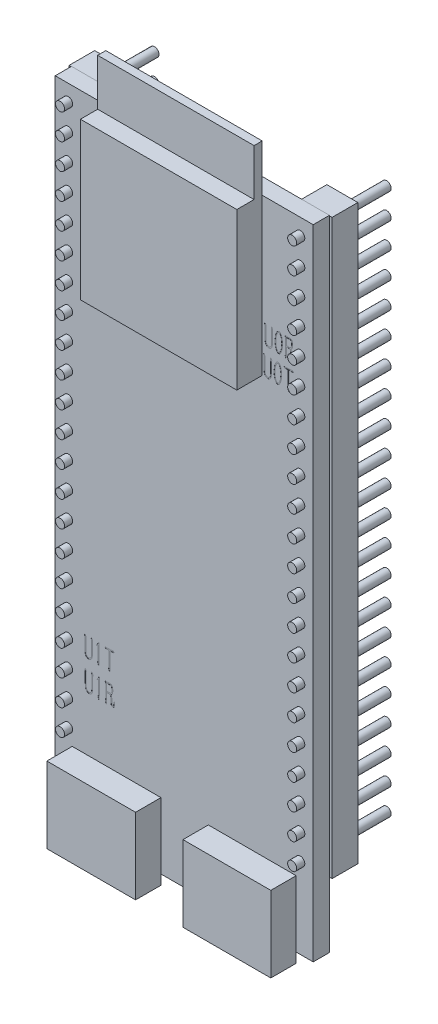
SolidWorks part; units mm, degrees
ref_plane "前视基准面" through (0, 0, 0) normal (0, 0, 1) x (1, 0, 0)
ref_plane "上视基准面" through (0, 0, 0) normal (0, 1, 0) x (1, 0, 0)
ref_plane "右视基准面" through (0, 0, 0) normal (1, 0, 0) x (0, 0, -1)
sketch "Model" plane through (0, 0, 0) normal (0, 0, 1) x (1, 0, 0)
  line L0 (0.5, 0) -> (24.9, 0)
  line L1 (25.4, 0.5) -> (25.4, 62.365)
  line L2 (24.9, 62.865) -> (0.5, 62.865)
  line L3 (0, 62.365) -> (0, 0.5)
  line L4 (0.5, 0) -> (24.9, 0)
  line L5 (25.4, 0.5) -> (25.4, 62.365)
  line L6 (24.9, 62.865) -> (0.5, 62.865)
  line L7 (0, 62.365) -> (0, 0.5)
  line L8 (12.0015, 26.3525) -> (12.6365, 26.3525)
  line L9 (12.6365, 26.3525) -> (12.6365, 25.7175)
  line L10 (12.6365, 25.7175) -> (12.0015, 25.7175)
  line L11 (12.0015, 25.7175) -> (12.0015, 26.3525)
  line L12 (7.6835, 45.9105) -> (9.2075, 45.9105)
  line L13 (9.2075, 45.9105) -> (9.2075, 44.8945)
  line L14 (9.2075, 44.8945) -> (7.6835, 44.8945)
  line L15 (7.6835, 44.8945) -> (7.6835, 45.9105)
  line L16 (-0.381, 0.127) -> (-0.3803, 0.127)
  line L17 (0, 62.865) -> (0.0007, 62.865)
  line L18 (-9.271, 0.127) -> (-9.271, 29.7815)
  line L19 (-9.271, 0.127) -> (-9.906, 2.667)
  line L20 (-9.906, 2.667) -> (-8.636, 2.667)
  line L21 (-8.636, 2.667) -> (-9.271, 0.127)
  line L22 (-9.271, 62.865) -> (-9.271, 33.2105)
  line L23 (-9.271, 62.865) -> (-8.636, 60.325)
  line L24 (-8.636, 60.325) -> (-9.906, 60.325)
  line L25 (-9.906, 60.325) -> (-9.271, 62.865)
  line L26 (-1.651, 0.127) -> (-10.541, 0.127)
  line L27 (-1.27, 62.865) -> (-10.541, 62.865)
  line L28 (-0.2495, -13.7253) -> (12.5857, -13.7253)
  line L29 (-0.2495, -14.4873) -> (12.5857, -14.4873)
  line L30 (1.124, -15.2493) -> (1.124, -12.9633)
  line L31 (8.3947, -14.4873) -> (8.3947, -13.7253)
  line L32 (6.2357, -15.2493) -> (6.2357, -14.4873)
  line L33 (12.5857, -12.9633) -> (-0.2413, -12.9633)
  line L34 (-0.2649, -10.9313) -> (12.5857, -10.9313)
  line L35 (12.5857, -10.9313) -> (12.5857, -15.2493)
  line L36 (12.5857, -15.2493) -> (-0.2649, -15.2493)
  line L37 (-0.2649, -15.2493) -> (-0.2649, -10.9313)
  line L38 (12.5857, -11.9473) -> (-0.2649, -11.9473)
  line L39 (6.7945, 59.7535) -> (7.9375, 59.7535)
  line L40 (7.9375, 59.7535) -> (7.9375, 59.1185)
  line L41 (7.9375, 59.1185) -> (6.7945, 59.1185)
  line L42 (6.7945, 59.1185) -> (6.7945, 59.7535)
  line L43 (0, 62.865) -> (0.0007, 62.865)
  line L44 (1.27, 62.865) -> (1.2707, 62.865)
  line L45 (0, 69.85) -> (-3.81, 69.85)
  line L46 (0, 69.85) -> (-2.54, 69.215)
  line L47 (-2.54, 69.215) -> (-2.54, 70.485)
  line L48 (-2.54, 70.485) -> (0, 69.85)
  line L49 (1.27, 69.85) -> (5.08, 69.85)
  line L50 (1.27, 69.85) -> (3.81, 70.485)
  line L51 (3.81, 70.485) -> (3.81, 69.215)
  line L52 (3.81, 69.215) -> (1.27, 69.85)
  line L53 (0, 64.135) -> (0, 71.12)
  line L54 (1.27, 64.135) -> (1.27, 71.12)
  line L55 (24.13, 62.865) -> (24.1307, 62.865)
  line L56 (25.4, 62.865) -> (25.4007, 62.865)
  line L57 (24.13, 69.85) -> (20.32, 69.85)
  line L58 (24.13, 69.85) -> (21.59, 69.215)
  line L59 (21.59, 69.215) -> (21.59, 70.485)
  line L60 (21.59, 70.485) -> (24.13, 69.85)
  line L61 (25.4, 69.85) -> (29.21, 69.85)
  line L62 (25.4, 69.85) -> (27.94, 70.485)
  line L63 (27.94, 70.485) -> (27.94, 69.215)
  line L64 (27.94, 69.215) -> (25.4, 69.85)
  line L65 (24.13, 64.135) -> (24.13, 71.12)
  line L66 (25.4, 64.135) -> (25.4, 71.12)
  line L67 (24.13, 58.801) -> (24.1307, 58.801)
  line L68 (24.13, 61.341) -> (24.1307, 61.341)
  line L69 (32.766, 58.801) -> (32.766, 54.991)
  line L70 (32.766, 58.801) -> (33.401, 56.261)
  line L71 (33.401, 56.261) -> (32.131, 56.261)
  line L72 (32.131, 56.261) -> (32.766, 58.801)
  line L73 (32.766, 61.341) -> (32.766, 65.151)
  line L74 (32.766, 61.341) -> (32.131, 63.881)
  line L75 (32.131, 63.881) -> (33.401, 63.881)
  line L76 (33.401, 63.881) -> (32.766, 61.341)
  line L77 (25.4, 58.801) -> (34.036, 58.801)
  line L78 (25.4, 61.341) -> (34.036, 61.341)
  line L79 (8.4455, 9.8425) -> (9.5885, 9.8425)
  line L80 (9.5885, 9.8425) -> (9.5885, 8.5725)
  line L81 (9.5885, 8.5725) -> (8.4455, 8.5725)
  line L82 (8.4455, 8.5725) -> (8.4455, 9.8425)
  line L83 (3.3655, 10.0965) -> (4.0005, 10.0965)
  line L84 (4.0005, 10.0965) -> (4.0005, 8.9535)
  line L85 (4.0005, 8.9535) -> (3.3655, 8.9535)
  line L86 (3.3655, 8.9535) -> (3.3655, 10.0965)
  line L87 (0, 0) -> (0.0007, 0)
  line L88 (25.4, 0) -> (25.4007, 0)
  line L89 (0, -7.747) -> (7.2621, -7.747)
  line L90 (0, -7.747) -> (2.54, -7.112)
  line L91 (2.54, -7.112) -> (2.54, -8.382)
  line L92 (2.54, -8.382) -> (0, -7.747)
  line L93 (25.4, -7.747) -> (18.1379, -7.747)
  line L94 (25.4, -7.747) -> (22.86, -8.382)
  line L95 (22.86, -8.382) -> (22.86, -7.112)
  line L96 (22.86, -7.112) -> (25.4, -7.747)
  line L97 (0, -1.27) -> (0, -9.017)
  line L98 (25.4, -1.27) -> (25.4, -9.017)
  line L99 (25.4, 0) -> (25.4007, 0)
  line L100 (25.4, 8.001) -> (25.4007, 8.001)
  line L101 (34.163, 0) -> (34.163, -3.81)
  line L102 (34.163, 0) -> (34.798, -2.54)
  line L103 (34.798, -2.54) -> (33.528, -2.54)
  line L104 (33.528, -2.54) -> (34.163, 0)
  line L105 (34.163, 8.001) -> (34.163, 11.811)
  line L106 (34.163, 8.001) -> (33.528, 10.541)
  line L107 (33.528, 10.541) -> (34.798, 10.541)
  line L108 (34.798, 10.541) -> (34.163, 8.001)
  line L109 (26.67, 0) -> (35.433, 0)
  line L110 (26.67, 8.001) -> (35.433, 8.001)
  line L111 (-0.381, 0.127) -> (-0.3803, 0.127)
  line L112 (0, 62.865) -> (0.0007, 62.865)
  line L113 (-9.271, 0.127) -> (-9.271, 29.7815)
  line L114 (-9.271, 0.127) -> (-9.906, 2.667)
  line L115 (-9.906, 2.667) -> (-8.636, 2.667)
  line L116 (-8.636, 2.667) -> (-9.271, 0.127)
  line L117 (-9.271, 62.865) -> (-9.271, 33.2105)
  line L118 (-9.271, 62.865) -> (-8.636, 60.325)
  line L119 (-8.636, 60.325) -> (-9.906, 60.325)
  line L120 (-9.906, 60.325) -> (-9.271, 62.865)
  line L121 (-1.651, 0.127) -> (-10.541, 0.127)
  line L122 (-1.27, 62.865) -> (-10.541, 62.865)
  line L123 (0, 62.865) -> (0.0007, 62.865)
  line L124 (1.27, 62.865) -> (1.2707, 62.865)
  line L125 (0, 69.85) -> (-3.81, 69.85)
  line L126 (0, 69.85) -> (-2.54, 69.215)
  line L127 (-2.54, 69.215) -> (-2.54, 70.485)
  line L128 (-2.54, 70.485) -> (0, 69.85)
  line L129 (1.27, 69.85) -> (5.08, 69.85)
  line L130 (1.27, 69.85) -> (3.81, 70.485)
  line L131 (3.81, 70.485) -> (3.81, 69.215)
  line L132 (3.81, 69.215) -> (1.27, 69.85)
  line L133 (0, 64.135) -> (0, 71.12)
  line L134 (1.27, 64.135) -> (1.27, 71.12)
  line L135 (24.13, 62.865) -> (24.1307, 62.865)
  line L136 (25.4, 62.865) -> (25.4007, 62.865)
  line L137 (24.13, 69.85) -> (20.32, 69.85)
  line L138 (24.13, 69.85) -> (21.59, 69.215)
  line L139 (21.59, 69.215) -> (21.59, 70.485)
  line L140 (21.59, 70.485) -> (24.13, 69.85)
  line L141 (25.4, 69.85) -> (29.21, 69.85)
  line L142 (25.4, 69.85) -> (27.94, 70.485)
  line L143 (27.94, 70.485) -> (27.94, 69.215)
  line L144 (27.94, 69.215) -> (25.4, 69.85)
  line L145 (24.13, 64.135) -> (24.13, 71.12)
  line L146 (25.4, 64.135) -> (25.4, 71.12)
  line L147 (24.13, 58.801) -> (24.1307, 58.801)
  line L148 (24.13, 61.341) -> (24.1307, 61.341)
  line L149 (32.766, 58.801) -> (32.766, 54.991)
  line L150 (32.766, 58.801) -> (33.401, 56.261)
  line L151 (33.401, 56.261) -> (32.131, 56.261)
  line L152 (32.131, 56.261) -> (32.766, 58.801)
  line L153 (32.766, 61.341) -> (32.766, 65.151)
  line L154 (32.766, 61.341) -> (32.131, 63.881)
  line L155 (32.131, 63.881) -> (33.401, 63.881)
  line L156 (33.401, 63.881) -> (32.766, 61.341)
  line L157 (25.4, 58.801) -> (34.036, 58.801)
  line L158 (25.4, 61.341) -> (34.036, 61.341)
  line L159 (0, 0) -> (0.0007, 0)
  line L160 (25.4, 0) -> (25.4007, 0)
  line L161 (0, -7.747) -> (7.2621, -7.747)
  line L162 (0, -7.747) -> (2.54, -7.112)
  line L163 (2.54, -7.112) -> (2.54, -8.382)
  line L164 (2.54, -8.382) -> (0, -7.747)
  line L165 (25.4, -7.747) -> (18.1379, -7.747)
  line L166 (25.4, -7.747) -> (22.86, -8.382)
  line L167 (22.86, -8.382) -> (22.86, -7.112)
  line L168 (22.86, -7.112) -> (25.4, -7.747)
  line L169 (0, -1.27) -> (0, -9.017)
  line L170 (25.4, -1.27) -> (25.4, -9.017)
  line L171 (25.4, 0) -> (25.4007, 0)
  line L172 (25.4, 8.001) -> (25.4007, 8.001)
  line L173 (34.163, 0) -> (34.163, -3.81)
  line L174 (34.163, 0) -> (34.798, -2.54)
  line L175 (34.798, -2.54) -> (33.528, -2.54)
  line L176 (33.528, -2.54) -> (34.163, 0)
  line L177 (34.163, 8.001) -> (34.163, 11.811)
  line L178 (34.163, 8.001) -> (33.528, 10.541)
  line L179 (33.528, 10.541) -> (34.798, 10.541)
  line L180 (34.798, 10.541) -> (34.163, 8.001)
  line L181 (26.67, 0) -> (35.433, 0)
  line L182 (26.67, 8.001) -> (35.433, 8.001)
  line L183 (5.7658, 44.069) -> (5.7658, 43.2054)
  line L184 (5.7658, 43.2054) -> (5.9436, 43.0276)
  line L185 (5.9436, 43.0276) -> (6.985, 43.0276)
  line L186 (6.985, 43.0276) -> (7.1882, 43.2308)
  line L187 (7.1882, 43.2308) -> (7.1882, 44.069)
  line L188 (5.7658, 44.831) -> (5.7658, 45.6946)
  line L189 (5.7658, 45.6946) -> (5.9436, 45.8724)
  line L190 (5.9436, 45.8724) -> (6.985, 45.8724)
  line L191 (6.985, 45.8724) -> (7.1882, 45.6692)
  line L192 (7.1882, 45.6692) -> (7.1882, 44.831)
  line L193 (6.9342, 43.2181) -> (6.0198, 43.2181)
  line L194 (6.0198, 43.2181) -> (6.0198, 45.6819)
  line L195 (6.0198, 45.6819) -> (6.9342, 45.6819)
  line L196 (6.9342, 45.6819) -> (6.9342, 43.2181)
  line L197 (7.62, 41.4528) -> (8.4836, 41.4528)
  line L198 (8.4836, 41.4528) -> (8.6614, 41.6306)
  line L199 (8.6614, 41.6306) -> (8.6614, 42.672)
  line L200 (8.6614, 42.672) -> (8.4582, 42.8752)
  line L201 (8.4582, 42.8752) -> (7.62, 42.8752)
  line L202 (6.858, 41.4528) -> (5.9944, 41.4528)
  line L203 (5.9944, 41.4528) -> (5.8166, 41.6306)
  line L204 (5.8166, 41.6306) -> (5.8166, 42.672)
  line L205 (5.8166, 42.672) -> (6.0198, 42.8752)
  line L206 (6.0198, 42.8752) -> (6.858, 42.8752)
  line L207 (8.4709, 42.6212) -> (8.4709, 41.7068)
  line L208 (8.4709, 41.7068) -> (6.0071, 41.7068)
  line L209 (6.0071, 41.7068) -> (6.0071, 42.6212)
  line L210 (6.0071, 42.6212) -> (8.4709, 42.6212)
  line L211 (7.62, 25.1968) -> (8.4836, 25.1968)
  line L212 (8.4836, 25.1968) -> (8.6614, 25.3746)
  line L213 (8.6614, 25.3746) -> (8.6614, 26.416)
  line L214 (8.6614, 26.416) -> (8.4582, 26.6192)
  line L215 (8.4582, 26.6192) -> (7.62, 26.6192)
  line L216 (6.858, 25.1968) -> (5.9944, 25.1968)
  line L217 (5.9944, 25.1968) -> (5.8166, 25.3746)
  line L218 (5.8166, 25.3746) -> (5.8166, 26.416)
  line L219 (5.8166, 26.416) -> (6.0198, 26.6192)
  line L220 (6.0198, 26.6192) -> (6.858, 26.6192)
  line L221 (8.4709, 26.3652) -> (8.4709, 25.4508)
  line L222 (8.4709, 25.4508) -> (6.0071, 25.4508)
  line L223 (6.0071, 25.4508) -> (6.0071, 26.3652)
  line L224 (6.0071, 26.3652) -> (8.4709, 26.3652)
  line L225 (8.636, 23.749) -> (8.636, 23.1902)
  line L226 (8.636, 23.1902) -> (8.5347, 23.0886)
  line L227 (8.5347, 23.0886) -> (7.9789, 23.0886)
  line L228 (7.9789, 23.0886) -> (7.874, 23.1935)
  line L229 (7.874, 23.1935) -> (7.874, 23.749)
  line L230 (8.636, 24.257) -> (8.636, 24.8158)
  line L231 (8.636, 24.8158) -> (8.5344, 24.9174)
  line L232 (8.5344, 24.9174) -> (7.9756, 24.9174)
  line L233 (7.9756, 24.9174) -> (7.874, 24.8158)
  line L234 (7.874, 24.8158) -> (7.874, 24.257)
  line L235 (8.001, 24.765) -> (8.509, 24.765)
  line L236 (8.509, 24.765) -> (8.509, 23.241)
  line L237 (8.509, 23.241) -> (8.001, 23.241)
  line L238 (8.001, 23.241) -> (8.001, 24.765)
  line L239 (6.477, 12.881) -> (7.0358, 12.881)
  line L240 (7.0358, 12.881) -> (7.1374, 12.7797)
  line L241 (7.1374, 12.7797) -> (7.1374, 12.2239)
  line L242 (7.1374, 12.2239) -> (7.0325, 12.119)
  line L243 (7.0325, 12.119) -> (6.477, 12.119)
  line L244 (5.969, 12.881) -> (5.4102, 12.881)
  line L245 (5.4102, 12.881) -> (5.3086, 12.7794)
  line L246 (5.3086, 12.7794) -> (5.3086, 12.2206)
  line L247 (5.3086, 12.2206) -> (5.4102, 12.119)
  line L248 (5.4102, 12.119) -> (5.969, 12.119)
  line L249 (5.461, 12.246) -> (5.461, 12.754)
  line L250 (5.461, 12.754) -> (6.985, 12.754)
  line L251 (6.985, 12.754) -> (6.985, 12.246)
  line L252 (6.985, 12.246) -> (5.461, 12.246)
  line L253 (19.304, 12.881) -> (19.8628, 12.881)
  line L254 (19.8628, 12.881) -> (19.9644, 12.7797)
  line L255 (19.9644, 12.7797) -> (19.9644, 12.2239)
  line L256 (19.9644, 12.2239) -> (19.8595, 12.119)
  line L257 (19.8595, 12.119) -> (19.304, 12.119)
  line L258 (18.796, 12.881) -> (18.2372, 12.881)
  line L259 (18.2372, 12.881) -> (18.1356, 12.7794)
  line L260 (18.1356, 12.7794) -> (18.1356, 12.2206)
  line L261 (18.1356, 12.2206) -> (18.2372, 12.119)
  line L262 (18.2372, 12.119) -> (18.796, 12.119)
  line L263 (18.288, 12.246) -> (18.288, 12.754)
  line L264 (18.288, 12.754) -> (19.812, 12.754)
  line L265 (19.812, 12.754) -> (19.812, 12.246)
  line L266 (19.812, 12.246) -> (18.288, 12.246)
  line L267 (7.366, 40.132) -> (7.366, 39.5732)
  line L268 (7.366, 39.5732) -> (7.2647, 39.4716)
  line L269 (7.2647, 39.4716) -> (6.7089, 39.4716)
  line L270 (6.7089, 39.4716) -> (6.604, 39.5765)
  line L271 (6.604, 39.5765) -> (6.604, 40.132)
  line L272 (7.366, 40.64) -> (7.366, 41.1988)
  line L273 (7.366, 41.1988) -> (7.2644, 41.3004)
  line L274 (7.2644, 41.3004) -> (6.7056, 41.3004)
  line L275 (6.7056, 41.3004) -> (6.604, 41.1988)
  line L276 (6.604, 41.1988) -> (6.604, 40.64)
  line L277 (6.731, 41.148) -> (7.239, 41.148)
  line L278 (7.239, 41.148) -> (7.239, 39.624)
  line L279 (7.239, 39.624) -> (6.731, 39.624)
  line L280 (6.731, 39.624) -> (6.731, 41.148)
  line L281 (12.319, 14.8112) -> (11.4554, 14.8112)
  line L282 (11.4554, 14.8112) -> (11.2776, 14.6334)
  line L283 (11.2776, 14.6334) -> (11.2776, 13.592)
  line L284 (11.2776, 13.592) -> (11.4808, 13.3888)
  line L285 (11.4808, 13.3888) -> (12.319, 13.3888)
  line L286 (13.081, 14.8112) -> (13.9446, 14.8112)
  line L287 (13.9446, 14.8112) -> (14.1224, 14.6334)
  line L288 (14.1224, 14.6334) -> (14.1224, 13.592)
  line L289 (14.1224, 13.592) -> (13.9192, 13.3888)
  line L290 (13.9192, 13.3888) -> (13.081, 13.3888)
  line L291 (11.4681, 13.6428) -> (11.4681, 14.5572)
  line L292 (11.4681, 14.5572) -> (13.9319, 14.5572)
  line L293 (13.9319, 14.5572) -> (13.9319, 13.6428)
  line L294 (13.9319, 13.6428) -> (11.4681, 13.6428)
  line L295 (12.7, 45.593) -> (13.2588, 45.593)
  line L296 (13.2588, 45.593) -> (13.3604, 45.4917)
  line L297 (13.3604, 45.4917) -> (13.3604, 44.9359)
  line L298 (13.3604, 44.9359) -> (13.2555, 44.831)
  line L299 (13.2555, 44.831) -> (12.7, 44.831)
  line L300 (12.192, 45.593) -> (11.6332, 45.593)
  line L301 (11.6332, 45.593) -> (11.5316, 45.4914)
  line L302 (11.5316, 45.4914) -> (11.5316, 44.9326)
  line L303 (11.5316, 44.9326) -> (11.6332, 44.831)
  line L304 (11.6332, 44.831) -> (12.192, 44.831)
  line L305 (11.684, 44.958) -> (11.684, 45.466)
  line L306 (11.684, 45.466) -> (13.208, 45.466)
  line L307 (13.208, 45.466) -> (13.208, 44.958)
  line L308 (13.208, 44.958) -> (11.684, 44.958)
  line L309 (7.62, 37.8968) -> (8.4836, 37.8968)
  line L310 (8.4836, 37.8968) -> (8.6614, 38.0746)
  line L311 (8.6614, 38.0746) -> (8.6614, 39.116)
  line L312 (8.6614, 39.116) -> (8.4582, 39.3192)
  line L313 (8.4582, 39.3192) -> (7.62, 39.3192)
  line L314 (6.858, 37.8968) -> (5.9944, 37.8968)
  line L315 (5.9944, 37.8968) -> (5.8166, 38.0746)
  line L316 (5.8166, 38.0746) -> (5.8166, 39.116)
  line L317 (5.8166, 39.116) -> (6.0198, 39.3192)
  line L318 (6.0198, 39.3192) -> (6.858, 39.3192)
  line L319 (8.4709, 39.0652) -> (8.4709, 38.1508)
  line L320 (8.4709, 38.1508) -> (6.0071, 38.1508)
  line L321 (6.0071, 38.1508) -> (6.0071, 39.0652)
  line L322 (6.0071, 39.0652) -> (8.4709, 39.0652)
  line L323 (7.874, 40.64) -> (7.874, 41.1988)
  line L324 (7.874, 41.1988) -> (7.9754, 41.3004)
  line L325 (7.9754, 41.3004) -> (8.5311, 41.3004)
  line L326 (8.5311, 41.3004) -> (8.636, 41.1955)
  line L327 (8.636, 41.1955) -> (8.636, 40.64)
  line L328 (7.874, 40.132) -> (7.874, 39.5732)
  line L329 (7.874, 39.5732) -> (7.9756, 39.4716)
  line L330 (7.9756, 39.4716) -> (8.5344, 39.4716)
  line L331 (8.5344, 39.4716) -> (8.636, 39.5732)
  line L332 (8.636, 39.5732) -> (8.636, 40.132)
  line L333 (8.509, 39.624) -> (8.001, 39.624)
  line L334 (8.001, 39.624) -> (8.001, 41.148)
  line L335 (8.001, 41.148) -> (8.509, 41.148)
  line L336 (8.509, 41.148) -> (8.509, 39.624)
  line L337 (6.477, 40.132) -> (6.477, 39.5732)
  line L338 (6.477, 39.5732) -> (6.3757, 39.4716)
  line L339 (6.3757, 39.4716) -> (5.8199, 39.4716)
  line L340 (5.8199, 39.4716) -> (5.715, 39.5765)
  line L341 (5.715, 39.5765) -> (5.715, 40.132)
  line L342 (6.477, 40.64) -> (6.477, 41.1988)
  line L343 (6.477, 41.1988) -> (6.3754, 41.3004)
  line L344 (6.3754, 41.3004) -> (5.8166, 41.3004)
  line L345 (5.8166, 41.3004) -> (5.715, 41.1988)
  line L346 (5.715, 41.1988) -> (5.715, 40.64)
  line L347 (5.842, 41.148) -> (6.35, 41.148)
  line L348 (6.35, 41.148) -> (6.35, 39.624)
  line L349 (6.35, 39.624) -> (5.842, 39.624)
  line L350 (5.842, 39.624) -> (5.842, 41.148)
  line L351 (11.164, 8.9) -> (9.664, 8.9)
  line L352 (9.664, 8.9) -> (9.664, 10.1)
  line L353 (9.664, 10.1) -> (11.164, 10.1)
  line L354 (11.164, 10.1) -> (11.164, 8.9)
  line L355 (10.939, 8.9) -> (10.939, 10.1)
  line L356 (11.164, 8.9) -> (9.664, 8.9)
  line L357 (9.664, 8.9) -> (9.664, 10.1)
  line L358 (9.664, 10.1) -> (11.164, 10.1)
  line L359 (11.164, 10.1) -> (11.164, 8.9)
  line L360 (4.172, 9.85) -> (4.972, 9.85)
  line L361 (4.972, 9.85) -> (4.972, 9.15)
  line L362 (4.972, 9.15) -> (4.172, 9.15)
  line L363 (4.172, 9.15) -> (4.172, 9.85)
  line L364 (4.972, 9.3) -> (4.172, 9.3)
  line L365 (4.172, 9.85) -> (4.972, 9.85)
  line L366 (4.972, 9.85) -> (4.972, 9.15)
  line L367 (4.972, 9.15) -> (4.172, 9.15)
  line L368 (4.172, 9.15) -> (4.172, 9.85)
  line L369 (5.569, 9.875) -> (6.369, 9.875)
  line L370 (6.369, 9.875) -> (6.369, 9.175)
  line L371 (6.369, 9.175) -> (5.569, 9.175)
  line L372 (5.569, 9.175) -> (5.569, 9.875)
  line L373 (6.369, 9.325) -> (5.569, 9.325)
  line L374 (5.569, 9.875) -> (6.369, 9.875)
  line L375 (6.369, 9.875) -> (6.369, 9.175)
  line L376 (6.369, 9.175) -> (5.569, 9.175)
  line L377 (5.569, 9.175) -> (5.569, 9.875)
  line L378 (6.585, 9.875) -> (7.385, 9.875)
  line L379 (7.385, 9.875) -> (7.385, 9.175)
  line L380 (7.385, 9.175) -> (6.585, 9.175)
  line L381 (6.585, 9.175) -> (6.585, 9.875)
  line L382 (7.385, 9.325) -> (6.585, 9.325)
  line L383 (6.585, 9.875) -> (7.385, 9.875)
  line L384 (7.385, 9.875) -> (7.385, 9.175)
  line L385 (7.385, 9.175) -> (6.585, 9.175)
  line L386 (6.585, 9.175) -> (6.585, 9.875)
  line L387 (19.7612, 41.1734) -> (19.7612, 38.3286)
  line L388 (19.7612, 38.3286) -> (18.3388, 38.3286)
  line L389 (18.3388, 38.3286) -> (18.3388, 41.1734)
  line L390 (18.3388, 41.1734) -> (19.7612, 41.1734)
  line L391 (19.5072, 39.9542) -> (18.5928, 39.9542)
  line L392 (18.5928, 39.9542) -> (19.05, 39.497)
  line L393 (19.05, 39.497) -> (19.5072, 39.9542)
  line L394 (19.7612, 41.1734) -> (19.7612, 38.3286)
  line L395 (19.7612, 38.3286) -> (18.3388, 38.3286)
  line L396 (18.3388, 38.3286) -> (18.3388, 41.1734)
  line L397 (18.3388, 41.1734) -> (19.7612, 41.1734)
  line L398 (19.5072, 39.9542) -> (18.5928, 39.9542)
  line L399 (18.5928, 39.9542) -> (19.05, 39.497)
  line L400 (19.05, 39.497) -> (19.5072, 39.9542)
  line L401 (9.243, 34.897) -> (9.243, 31.397)
  line L402 (5.993, 31.397) -> (5.743, 31.647)
  line L403 (5.743, 31.647) -> (5.743, 34.897)
  line L404 (8.993, 34.897) -> (9.243, 34.897)
  line L405 (9.243, 31.397) -> (8.993, 31.397)
  line L406 (7.743, 31.397) -> (7.243, 31.397)
  line L407 (7.743, 34.897) -> (7.243, 34.897)
  line L408 (5.743, 34.897) -> (5.993, 34.897)
  line L409 (6.093, 35.547) -> (8.893, 35.547)
  line L410 (8.893, 35.547) -> (8.893, 30.747)
  line L411 (8.893, 30.747) -> (6.093, 30.747)
  line L412 (6.093, 30.747) -> (6.093, 35.547)
  line L413 (1.946, -0.7657) -> (1.946, -0.8657)
  line L414 (1.996, 1.4343) -> (1.996, 2.3343)
  line L415 (2.196, -0.8349) -> (2.196, -0.8657)
  line L416 (2.2372, -0.8349) -> (2.2372, -0.8657)
  line L417 (2.246, 4.7343) -> (2.246, -0.1687)
  line L418 (2.496, -0.3349) -> (2.496, -0.2657)
  line L419 (2.5192, -0.2657) -> (2.5192, -0.3349)
  line L420 (2.596, 4.7343) -> (2.596, -0.2657)
  line L421 (2.6131, -0.3349) -> (2.6131, -0.2657)
  line L422 (2.696, -0.2657) -> (2.696, -0.8657)
  line L423 (9.3789, -0.3349) -> (9.6081, -0.6283)
  line L424 (9.496, -0.3349) -> (9.796, -0.8349)
  line L425 (9.7959, -0.3488) -> (10.046, -0.7657)
  line L426 (9.4728, -0.3349) -> (9.6081, -0.6283)
  line L427 (9.296, -0.2657) -> (9.296, -0.8657)
  line L428 (9.3789, -0.3349) -> (9.3789, -0.2657)
  line L429 (9.396, -0.2657) -> (9.396, 4.7343)
  line L430 (9.4728, -0.3349) -> (9.4728, -0.2657)
  line L431 (9.496, -0.3349) -> (9.496, -0.2657)
  line L432 (9.746, -0.1687) -> (9.746, 4.7343)
  line L433 (9.7549, -0.8349) -> (9.7549, -0.8657)
  line L434 (9.796, -0.8349) -> (9.796, -0.8657)
  line L435 (9.996, 2.3343) -> (9.996, 1.4343)
  line L436 (10.046, -0.7657) -> (10.046, -0.8657)
  line L437 (2.5192, -0.3349) -> (2.3839, -0.6283)
  line L438 (2.1961, -0.3488) -> (1.946, -0.7657)
  line L439 (2.496, -0.3349) -> (2.196, -0.8349)
  line L440 (2.6131, -0.3349) -> (2.3839, -0.6283)
  line L441 (9.296, -0.8657) -> (2.696, -0.8657)
  line L442 (1.946, -0.8657) -> (2.2372, -0.8657)
  line L443 (9.7549, -0.8657) -> (10.046, -0.8657)
  line L444 (9.796, -0.8349) -> (9.7549, -0.8349)
  line L445 (2.2372, -0.8349) -> (2.196, -0.8349)
  line L446 (2.696, -0.7657) -> (9.296, -0.7657)
  line L447 (9.296, -0.3488) -> (2.696, -0.3488)
  line L448 (9.496, -0.3349) -> (9.3789, -0.3349)
  line L449 (2.6131, -0.3349) -> (2.496, -0.3349)
  line L450 (2.696, -0.2657) -> (2.2323, -0.2657)
  line L451 (9.296, -0.2657) -> (9.7597, -0.2657)
  line L452 (9.746, -0.1687) -> (2.246, -0.1687)
  line L453 (9.996, 1.4343) -> (9.746, 1.4343)
  line L454 (2.246, 1.4343) -> (1.996, 1.4343)
  line L455 (1.996, 2.3343) -> (2.246, 2.3343)
  line L456 (9.746, 2.3343) -> (9.996, 2.3343)
  line L457 (2.246, 4.7343) -> (9.746, 4.7343)
  line L458 (10.325, 1.017) -> (1.675, 1.017)
  line L459 (1.675, 1.017) -> (1.675, 6.517)
  line L460 (1.675, 6.517) -> (10.325, 6.517)
  line L461 (10.325, 6.517) -> (10.325, 1.017)
  line L462 (19.58, 31.247) -> (19.58, 35.047)
  line L463 (19.58, 35.047) -> (15.98, 35.047)
  line L464 (15.98, 35.047) -> (15.98, 31.247)
  line L465 (15.98, 31.247) -> (19.58, 31.247)
  line L466 (19.23, 32.822) -> (19.23, 33.472)
  line L467 (19.23, 33.472) -> (16.33, 33.472)
  line L468 (16.33, 33.472) -> (16.33, 32.822)
  line L469 (16.33, 32.822) -> (19.23, 32.822)
  line L470 (15.98, 31.247) -> (15.98, 35.047)
  line L471 (15.98, 35.047) -> (19.58, 35.047)
  line L472 (19.58, 35.047) -> (19.58, 31.247)
  line L473 (19.58, 31.247) -> (15.98, 31.247)
  line L474 (16.3652, 31.2547) -> (15.9842, 31.6357)
  line L475 (19.58, 31.247) -> (19.58, 35.047)
  line L476 (19.58, 35.047) -> (15.98, 35.047)
  line L477 (15.98, 35.047) -> (15.98, 31.247)
  line L478 (15.98, 31.247) -> (19.58, 31.247)
  line L479 (19.23, 32.822) -> (19.23, 33.472)
  line L480 (19.23, 33.472) -> (16.33, 33.472)
  line L481 (16.33, 33.472) -> (16.33, 32.822)
  line L482 (16.33, 32.822) -> (19.23, 32.822)
  line L483 (15.98, 31.247) -> (15.98, 35.047)
  line L484 (15.98, 35.047) -> (19.58, 35.047)
  line L485 (19.58, 35.047) -> (19.58, 31.247)
  line L486 (19.58, 31.247) -> (15.98, 31.247)
  line L487 (14.373, 31.247) -> (14.373, 35.047)
  line L488 (14.373, 35.047) -> (10.773, 35.047)
  line L489 (10.773, 35.047) -> (10.773, 31.247)
  line L490 (10.773, 31.247) -> (14.373, 31.247)
  line L491 (14.023, 32.822) -> (14.023, 33.472)
  line L492 (14.023, 33.472) -> (11.123, 33.472)
  line L493 (11.123, 33.472) -> (11.123, 32.822)
  line L494 (11.123, 32.822) -> (14.023, 32.822)
  line L495 (10.773, 31.247) -> (10.773, 35.047)
  line L496 (10.773, 35.047) -> (14.373, 35.047)
  line L497 (14.373, 35.047) -> (14.373, 31.247)
  line L498 (14.373, 31.247) -> (10.773, 31.247)
  line L499 (11.1582, 31.2547) -> (10.7772, 31.6357)
  line L500 (14.373, 31.247) -> (14.373, 35.047)
  line L501 (14.373, 35.047) -> (10.773, 35.047)
  line L502 (10.773, 35.047) -> (10.773, 31.247)
  line L503 (10.773, 31.247) -> (14.373, 31.247)
  line L504 (14.023, 32.822) -> (14.023, 33.472)
  line L505 (14.023, 33.472) -> (11.123, 33.472)
  line L506 (11.123, 33.472) -> (11.123, 32.822)
  line L507 (11.123, 32.822) -> (14.023, 32.822)
  line L508 (10.773, 31.247) -> (10.773, 35.047)
  line L509 (10.773, 35.047) -> (14.373, 35.047)
  line L510 (14.373, 35.047) -> (14.373, 31.247)
  line L511 (14.373, 31.247) -> (10.773, 31.247)
  line L512 (16.637, 30.226) -> (17.2974, 30.226)
  line L513 (17.2974, 30.226) -> (17.2974, 29.464)
  line L514 (17.2974, 29.464) -> (16.637, 29.464)
  line L515 (16.129, 30.226) -> (15.4686, 30.226)
  line L516 (15.4686, 30.226) -> (15.4686, 29.464)
  line L517 (15.4686, 29.464) -> (16.129, 29.464)
  line L518 (15.621, 29.591) -> (15.621, 30.099)
  line L519 (15.621, 30.099) -> (17.145, 30.099)
  line L520 (17.145, 30.099) -> (17.145, 29.591)
  line L521 (17.145, 29.591) -> (15.621, 29.591)
  line L522 (19.431, 42.926) -> (19.431, 42.2656)
  line L523 (19.431, 42.2656) -> (18.669, 42.2656)
  line L524 (18.669, 42.2656) -> (18.669, 42.926)
  line L525 (19.431, 43.434) -> (19.431, 44.0944)
  line L526 (19.431, 44.0944) -> (18.669, 44.0944)
  line L527 (18.669, 44.0944) -> (18.669, 43.434)
  line L528 (18.796, 43.942) -> (19.304, 43.942)
  line L529 (19.304, 43.942) -> (19.304, 42.418)
  line L530 (19.304, 42.418) -> (18.796, 42.418)
  line L531 (18.796, 42.418) -> (18.796, 43.942)
  line L532 (18.415, 29.464) -> (17.7546, 29.464)
  line L533 (17.7546, 29.464) -> (17.7546, 30.226)
  line L534 (17.7546, 30.226) -> (18.415, 30.226)
  line L535 (18.923, 29.464) -> (19.5834, 29.464)
  line L536 (19.5834, 29.464) -> (19.5834, 30.226)
  line L537 (19.5834, 30.226) -> (18.923, 30.226)
  line L538 (19.431, 30.099) -> (19.431, 29.591)
  line L539 (19.431, 29.591) -> (17.907, 29.591)
  line L540 (17.907, 29.591) -> (17.907, 30.099)
  line L541 (17.907, 30.099) -> (19.431, 30.099)
  line L542 (11.43, 29.464) -> (10.7696, 29.464)
  line L543 (10.7696, 29.464) -> (10.7696, 30.226)
  line L544 (10.7696, 30.226) -> (11.43, 30.226)
  line L545 (11.938, 29.464) -> (12.5984, 29.464)
  line L546 (12.5984, 29.464) -> (12.5984, 30.226)
  line L547 (12.5984, 30.226) -> (11.938, 30.226)
  line L548 (12.446, 30.099) -> (12.446, 29.591)
  line L549 (12.446, 29.591) -> (10.922, 29.591)
  line L550 (10.922, 29.591) -> (10.922, 30.099)
  line L551 (10.922, 30.099) -> (12.446, 30.099)
  line L552 (6.477, 20.955) -> (5.8166, 20.955)
  line L553 (5.8166, 20.955) -> (5.8166, 21.717)
  line L554 (5.8166, 21.717) -> (6.477, 21.717)
  line L555 (6.985, 20.955) -> (7.6454, 20.955)
  line L556 (7.6454, 20.955) -> (7.6454, 21.717)
  line L557 (7.6454, 21.717) -> (6.985, 21.717)
  line L558 (7.493, 21.59) -> (7.493, 21.082)
  line L559 (7.493, 21.082) -> (5.969, 21.082)
  line L560 (5.969, 21.082) -> (5.969, 21.59)
  line L561 (5.969, 21.59) -> (7.493, 21.59)
  line L562 (6.477, 21.844) -> (5.8166, 21.844)
  line L563 (5.8166, 21.844) -> (5.8166, 22.606)
  line L564 (5.8166, 22.606) -> (6.477, 22.606)
  line L565 (6.985, 21.844) -> (7.6454, 21.844)
  line L566 (7.6454, 21.844) -> (7.6454, 22.606)
  line L567 (7.6454, 22.606) -> (6.985, 22.606)
  line L568 (7.493, 22.479) -> (7.493, 21.971)
  line L569 (7.493, 21.971) -> (5.969, 21.971)
  line L570 (5.969, 21.971) -> (5.969, 22.479)
  line L571 (5.969, 22.479) -> (7.493, 22.479)
  line L572 (9.144, 30.226) -> (9.8044, 30.226)
  line L573 (9.8044, 30.226) -> (9.8044, 29.464)
  line L574 (9.8044, 29.464) -> (9.144, 29.464)
  line L575 (8.636, 30.226) -> (7.9756, 30.226)
  line L576 (7.9756, 30.226) -> (7.9756, 29.464)
  line L577 (7.9756, 29.464) -> (8.636, 29.464)
  line L578 (8.128, 29.591) -> (8.128, 30.099)
  line L579 (8.128, 30.099) -> (9.652, 30.099)
  line L580 (9.652, 30.099) -> (9.652, 29.591)
  line L581 (9.652, 29.591) -> (8.128, 29.591)
  line L582 (6.477, 24.13) -> (5.8166, 24.13)
  line L583 (5.8166, 24.13) -> (5.8166, 24.892)
  line L584 (5.8166, 24.892) -> (6.477, 24.892)
  line L585 (6.985, 24.13) -> (7.6454, 24.13)
  line L586 (7.6454, 24.13) -> (7.6454, 24.892)
  line L587 (7.6454, 24.892) -> (6.985, 24.892)
  line L588 (7.493, 24.765) -> (7.493, 24.257)
  line L589 (7.493, 24.257) -> (5.969, 24.257)
  line L590 (5.969, 24.257) -> (5.969, 24.765)
  line L591 (5.969, 24.765) -> (7.493, 24.765)
  line L592 (6.985, 23.876) -> (7.6454, 23.876)
  line L593 (7.6454, 23.876) -> (7.6454, 23.114)
  line L594 (7.6454, 23.114) -> (6.985, 23.114)
  line L595 (6.477, 23.876) -> (5.8166, 23.876)
  line L596 (5.8166, 23.876) -> (5.8166, 23.114)
  line L597 (5.8166, 23.114) -> (6.477, 23.114)
  line L598 (5.969, 23.241) -> (5.969, 23.749)
  line L599 (5.969, 23.749) -> (7.493, 23.749)
  line L600 (7.493, 23.749) -> (7.493, 23.241)
  line L601 (7.493, 23.241) -> (5.969, 23.241)
  line L602 (10.16, 44.831) -> (9.4996, 44.831)
  line L603 (9.4996, 44.831) -> (9.4996, 45.593)
  line L604 (9.4996, 45.593) -> (10.16, 45.593)
  line L605 (10.668, 44.831) -> (11.3284, 44.831)
  line L606 (11.3284, 44.831) -> (11.3284, 45.593)
  line L607 (11.3284, 45.593) -> (10.668, 45.593)
  line L608 (11.176, 45.466) -> (11.176, 44.958)
  line L609 (11.176, 44.958) -> (9.652, 44.958)
  line L610 (9.652, 44.958) -> (9.652, 45.466)
  line L611 (9.652, 45.466) -> (11.176, 45.466)
  line L612 (6.477, 29.464) -> (5.8166, 29.464)
  line L613 (5.8166, 29.464) -> (5.8166, 30.226)
  line L614 (5.8166, 30.226) -> (6.477, 30.226)
  line L615 (6.985, 29.464) -> (7.6454, 29.464)
  line L616 (7.6454, 29.464) -> (7.6454, 30.226)
  line L617 (7.6454, 30.226) -> (6.985, 30.226)
  line L618 (7.493, 30.099) -> (7.493, 29.591)
  line L619 (7.493, 29.591) -> (5.969, 29.591)
  line L620 (5.969, 29.591) -> (5.969, 30.099)
  line L621 (5.969, 30.099) -> (7.493, 30.099)
  line L622 (18.923, 24.892) -> (19.5834, 24.892)
  line L623 (19.5834, 24.892) -> (19.5834, 24.13)
  line L624 (19.5834, 24.13) -> (18.923, 24.13)
  line L625 (18.415, 24.892) -> (17.7546, 24.892)
  line L626 (17.7546, 24.892) -> (17.7546, 24.13)
  line L627 (17.7546, 24.13) -> (18.415, 24.13)
  line L628 (17.907, 24.257) -> (17.907, 24.765)
  line L629 (17.907, 24.765) -> (19.431, 24.765)
  line L630 (19.431, 24.765) -> (19.431, 24.257)
  line L631 (19.431, 24.257) -> (17.907, 24.257)
  line L632 (13.716, 29.464) -> (13.0556, 29.464)
  line L633 (13.0556, 29.464) -> (13.0556, 30.226)
  line L634 (13.0556, 30.226) -> (13.716, 30.226)
  line L635 (14.224, 29.464) -> (14.8844, 29.464)
  line L636 (14.8844, 29.464) -> (14.8844, 30.226)
  line L637 (14.8844, 30.226) -> (14.224, 30.226)
  line L638 (14.732, 30.099) -> (14.732, 29.591)
  line L639 (14.732, 29.591) -> (13.208, 29.591)
  line L640 (13.208, 29.591) -> (13.208, 30.099)
  line L641 (13.208, 30.099) -> (14.732, 30.099)
  line L642 (18.923, 23.622) -> (19.5834, 23.622)
  line L643 (19.5834, 23.622) -> (19.5834, 22.86)
  line L644 (19.5834, 22.86) -> (18.923, 22.86)
  line L645 (18.415, 23.622) -> (17.7546, 23.622)
  line L646 (17.7546, 23.622) -> (17.7546, 22.86)
  line L647 (17.7546, 22.86) -> (18.415, 22.86)
  line L648 (17.907, 22.987) -> (17.907, 23.495)
  line L649 (17.907, 23.495) -> (19.431, 23.495)
  line L650 (19.431, 23.495) -> (19.431, 22.987)
  line L651 (19.431, 22.987) -> (17.907, 22.987)
  line L652 (5.4, 13.375) -> (9.6, 13.375)
  line L653 (9.6, 14.3) -> (9.6, 15.7)
  line L654 (9.6, 16.625) -> (5.4, 16.625)
  line L655 (5.4, 15.7) -> (5.4, 14.3)
  line L656 (9.6, 13.375) -> (9.6, 13.55)
  line L657 (5.4, 13.375) -> (5.4, 13.55)
  line L658 (9.6, 16.45) -> (9.6, 16.625)
  line L659 (5.4, 16.45) -> (5.4, 16.625)
  line L660 (8.05, 15) -> (6.95, 15)
  line L661 (7.5, 14.45) -> (7.5, 15.55)
  line L662 (7.9, 13.9) -> (7.1, 13.9)
  line L663 (7.1, 16.1) -> (7.9, 16.1)
  line L664 (7.9, 13.9) -> (7.1, 13.9)
  line L665 (7.1, 16.1) -> (7.9, 16.1)
  line L666 (15.78, 13.375) -> (19.98, 13.375)
  line L667 (19.98, 14.3) -> (19.98, 15.7)
  line L668 (19.98, 16.625) -> (15.78, 16.625)
  line L669 (15.78, 15.7) -> (15.78, 14.3)
  line L670 (19.98, 13.375) -> (19.98, 13.55)
  line L671 (15.78, 13.375) -> (15.78, 13.55)
  line L672 (19.98, 16.45) -> (19.98, 16.625)
  line L673 (15.78, 16.45) -> (15.78, 16.625)
  line L674 (18.43, 15) -> (17.33, 15)
  line L675 (17.88, 14.45) -> (17.88, 15.55)
  line L676 (18.28, 13.9) -> (17.48, 13.9)
  line L677 (17.48, 16.1) -> (18.28, 16.1)
  line L678 (18.28, 13.9) -> (17.48, 13.9)
  line L679 (17.48, 16.1) -> (18.28, 16.1)
  line L680 (17.837, 43.2547) -> (15.566, 43.2547)
  line L681 (15.566, 43.2547) -> (15.566, 44.498)
  line L682 (15.566, 44.498) -> (9.087, 44.498)
  line L683 (9.087, 44.498) -> (9.087, 37.798)
  line L684 (9.087, 37.798) -> (15.4497, 37.798)
  line L685 (15.4497, 37.798) -> (15.4497, 39.0413)
  line L686 (15.4497, 39.0413) -> (17.837, 39.0413)
  line L687 (17.837, 39.0413) -> (17.837, 43.2547)
  line L688 (17.837, 43.2547) -> (15.566, 43.2547)
  line L689 (15.566, 43.2547) -> (15.566, 44.498)
  line L690 (15.566, 44.498) -> (9.087, 44.498)
  line L691 (9.087, 44.498) -> (9.087, 37.798)
  line L692 (9.087, 37.798) -> (15.4497, 37.798)
  line L693 (15.4497, 37.798) -> (15.4497, 39.0413)
  line L694 (15.4497, 39.0413) -> (17.837, 39.0413)
  line L695 (17.837, 39.0413) -> (17.837, 43.2547)
  line L696 (15.389, 21.122) -> (16.089, 21.122)
  line L697 (16.089, 21.122) -> (16.089, 21.822)
  line L698 (11.789, 26.122) -> (11.089, 26.122)
  line L699 (11.089, 26.122) -> (11.089, 25.422)
  line L700 (11.789, 21.122) -> (11.089, 21.122)
  line L701 (11.089, 21.122) -> (11.089, 21.822)
  line L702 (16.089, 25.372) -> (16.089, 25.872)
  line L703 (16.089, 25.872) -> (15.839, 26.122)
  line L704 (15.839, 26.122) -> (15.339, 26.122)
  line L705 (15.464, 21.997) -> (15.464, 25.247)
  line L706 (15.464, 25.247) -> (15.214, 25.247)
  line L707 (15.214, 25.247) -> (15.214, 21.997)
  line L708 (15.214, 21.997) -> (15.464, 21.997)
  line L709 (15.214, 25.497) -> (11.964, 25.497)
  line L710 (11.964, 25.497) -> (11.964, 25.247)
  line L711 (11.964, 25.247) -> (15.214, 25.247)
  line L712 (15.214, 25.247) -> (15.214, 25.497)
  line L713 (15.214, 21.997) -> (15.214, 21.747)
  line L714 (15.214, 21.747) -> (11.964, 21.747)
  line L715 (11.964, 21.747) -> (11.964, 21.997)
  line L716 (11.964, 21.997) -> (15.214, 21.997)
  line L717 (11.714, 25.247) -> (11.964, 25.247)
  line L718 (11.964, 25.247) -> (11.964, 21.997)
  line L719 (11.964, 21.997) -> (11.714, 21.997)
  line L720 (11.714, 21.997) -> (11.714, 25.247)
  line L721 (4.9784, 48.598) -> (4.9784, 47.498)
  line L722 (4.9784, 47.498) -> (6.0784, 47.498)
  line L723 (4.9784, 47.498) -> (20.3784, 47.498)
  line L724 (20.3784, 47.498) -> (20.3784, 48.598)
  line L725 (4.9784, 62.398) -> (4.9784, 67.498)
  line L726 (4.9784, 67.498) -> (20.3784, 67.498)
  line L727 (20.3784, 67.498) -> (20.3784, 62.398)
  line L728 (4.9784, 67.498) -> (20.3784, 67.498)
  line L729 (20.3784, 67.498) -> (20.3784, 62.998)
  line L730 (20.3784, 62.998) -> (4.9784, 62.998)
  line L731 (4.9784, 62.998) -> (4.9784, 67.498)
  line L732 (4.9784, 47.498) -> (4.9784, 62.898)
  line L733 (4.9784, 62.898) -> (6.0784, 62.898)
  line L734 (20.3784, 47.498) -> (20.3784, 62.898)
  line L735 (20.3784, 62.898) -> (4.9784, 62.898)
  line L736 (6.3792, 61.4007) -> (6.3792, 49.0055)
  line L737 (6.3792, 49.0055) -> (4.972, 49.0055)
  line L738 (4.972, 49.0055) -> (4.972, 61.4007)
  line L739 (4.972, 61.4007) -> (6.3792, 61.4007)
  line L740 (20.3898, 61.4032) -> (18.9776, 61.4032)
  line L741 (18.9776, 61.4032) -> (18.9776, 48.9928)
  line L742 (18.9776, 48.9928) -> (20.3898, 48.9928)
  line L743 (20.3898, 48.9928) -> (20.3898, 61.4032)
  line L744 (6.9761, 47.512) -> (6.9761, 48.8988)
  line L745 (6.9761, 48.8988) -> (18.3883, 48.8988)
  line L746 (18.3883, 48.8988) -> (18.3883, 47.512)
  line L747 (18.3883, 47.512) -> (6.9761, 47.512)
  line L748 (6.477, 62.9996) -> (18.8798, 62.9996)
  line L749 (18.8798, 62.9996) -> (18.8798, 61.4959)
  line L750 (18.8798, 61.4959) -> (6.477, 61.4959)
  line L751 (6.477, 61.4959) -> (6.477, 62.9996)
  line L752 (10.4284, 56.848) -> (11.0284, 57.448)
  line L753 (11.0284, 57.448) -> (11.6284, 57.448)
  line L754 (11.6284, 57.448) -> (11.6284, 56.248)
  line L755 (11.6284, 56.248) -> (10.4284, 56.248)
  line L756 (10.4284, 56.248) -> (10.4284, 56.848)
  line L757 (12.0784, 57.448) -> (13.2784, 57.448)
  line L758 (13.2784, 57.448) -> (13.2784, 56.248)
  line L759 (13.2784, 56.248) -> (12.0784, 56.248)
  line L760 (12.0784, 56.248) -> (12.0784, 57.448)
  line L761 (13.7284, 57.448) -> (14.9284, 57.448)
  line L762 (14.9284, 57.448) -> (14.9284, 56.248)
  line L763 (14.9284, 56.248) -> (13.7284, 56.248)
  line L764 (13.7284, 56.248) -> (13.7284, 57.448)
  line L765 (13.7284, 55.798) -> (14.9284, 55.798)
  line L766 (14.9284, 55.798) -> (14.9284, 54.598)
  line L767 (14.9284, 54.598) -> (13.7284, 54.598)
  line L768 (13.7284, 54.598) -> (13.7284, 55.798)
  line L769 (13.7284, 54.148) -> (14.9284, 54.148)
  line L770 (14.9284, 54.148) -> (14.9284, 52.948)
  line L771 (14.9284, 52.948) -> (13.7284, 52.948)
  line L772 (13.7284, 52.948) -> (13.7284, 54.148)
  line L773 (12.0784, 54.148) -> (13.2784, 54.148)
  line L774 (13.2784, 54.148) -> (13.2784, 52.948)
  line L775 (13.2784, 52.948) -> (12.0784, 52.948)
  line L776 (12.0784, 52.948) -> (12.0784, 54.148)
  line L777 (10.4284, 54.148) -> (11.6284, 54.148)
  line L778 (11.6284, 54.148) -> (11.6284, 52.948)
  line L779 (11.6284, 52.948) -> (10.4284, 52.948)
  line L780 (10.4284, 52.948) -> (10.4284, 54.148)
  line L781 (10.4284, 55.798) -> (11.6284, 55.798)
  line L782 (11.6284, 55.798) -> (11.6284, 54.598)
  line L783 (11.6284, 54.598) -> (10.4284, 54.598)
  line L784 (10.4284, 54.598) -> (10.4284, 55.798)
  line L785 (-0.254, 62.8139) -> (-0.254, 6.426)
  line L786 (-0.254, 6.426) -> (2.794, 6.426)
  line L787 (2.794, 6.426) -> (2.794, 62.8139)
  line L788 (2.794, 62.8139) -> (-0.254, 62.8139)
  line L789 (22.606, 62.8139) -> (22.606, 6.426)
  line L790 (22.606, 6.426) -> (25.654, 6.426)
  line L791 (25.654, 6.426) -> (25.654, 62.8139)
  line L792 (25.654, 62.8139) -> (22.606, 62.8139)
  line L793 (7.4168, 44.069) -> (7.4168, 43.0276)
  line L794 (7.4168, 43.0276) -> (8.8392, 43.0276)
  line L795 (8.8392, 43.0276) -> (8.8392, 44.069)
  line L796 (7.4168, 44.831) -> (7.4168, 45.8724)
  line L797 (7.4168, 45.8724) -> (8.8392, 45.8724)
  line L798 (8.8392, 45.8724) -> (8.8392, 44.831)
  line L799 (8.5852, 43.2181) -> (7.6708, 43.2181)
  line L800 (7.6708, 43.2181) -> (7.6708, 45.6819)
  line L801 (7.6708, 45.6819) -> (8.5852, 45.6819)
  line L802 (8.5852, 45.6819) -> (8.5852, 43.2181)
  line L803 (12.319, 16.5862) -> (11.4554, 16.5862)
  line L804 (11.4554, 16.5862) -> (11.2776, 16.4084)
  line L805 (11.2776, 16.4084) -> (11.2776, 15.367)
  line L806 (11.2776, 15.367) -> (11.4808, 15.1638)
  line L807 (11.4808, 15.1638) -> (12.319, 15.1638)
  line L808 (13.081, 16.5862) -> (13.9446, 16.5862)
  line L809 (13.9446, 16.5862) -> (14.1224, 16.4084)
  line L810 (14.1224, 16.4084) -> (14.1224, 15.367)
  line L811 (14.1224, 15.367) -> (13.9192, 15.1638)
  line L812 (13.9192, 15.1638) -> (13.081, 15.1638)
  line L813 (11.4681, 15.4178) -> (11.4681, 16.3322)
  line L814 (11.4681, 16.3322) -> (13.9319, 16.3322)
  line L815 (13.9319, 16.3322) -> (13.9319, 15.4178)
  line L816 (13.9319, 15.4178) -> (11.4681, 15.4178)
  line L817 (14.109, 10.1) -> (15.609, 10.1)
  line L818 (15.609, 10.1) -> (15.609, 8.9)
  line L819 (15.609, 8.9) -> (14.109, 8.9)
  line L820 (14.109, 8.9) -> (14.109, 10.1)
  line L821 (14.334, 10.1) -> (14.334, 8.9)
  line L822 (14.109, 10.1) -> (15.609, 10.1)
  line L823 (15.609, 10.1) -> (15.609, 8.9)
  line L824 (15.609, 8.9) -> (14.109, 8.9)
  line L825 (14.109, 8.9) -> (14.109, 10.1)
  line L826 (19.666, 9.875) -> (20.466, 9.875)
  line L827 (20.466, 9.875) -> (20.466, 9.175)
  line L828 (20.466, 9.175) -> (19.666, 9.175)
  line L829 (19.666, 9.175) -> (19.666, 9.875)
  line L830 (20.466, 9.325) -> (19.666, 9.325)
  line L831 (19.666, 9.875) -> (20.466, 9.875)
  line L832 (20.466, 9.875) -> (20.466, 9.175)
  line L833 (20.466, 9.175) -> (19.666, 9.175)
  line L834 (19.666, 9.175) -> (19.666, 9.875)
  line L835 (17.126, 9.85) -> (17.926, 9.85)
  line L836 (17.926, 9.85) -> (17.926, 9.15)
  line L837 (17.926, 9.15) -> (17.126, 9.15)
  line L838 (17.126, 9.15) -> (17.126, 9.85)
  line L839 (17.926, 9.3) -> (17.126, 9.3)
  line L840 (17.126, 9.85) -> (17.926, 9.85)
  line L841 (17.926, 9.85) -> (17.926, 9.15)
  line L842 (17.926, 9.15) -> (17.126, 9.15)
  line L843 (17.126, 9.15) -> (17.126, 9.85)
  line L844 (18.65, 9.875) -> (19.45, 9.875)
  line L845 (19.45, 9.875) -> (19.45, 9.175)
  line L846 (19.45, 9.175) -> (18.65, 9.175)
  line L847 (18.65, 9.175) -> (18.65, 9.875)
  line L848 (19.45, 9.325) -> (18.65, 9.325)
  line L849 (18.65, 9.875) -> (19.45, 9.875)
  line L850 (19.45, 9.875) -> (19.45, 9.175)
  line L851 (19.45, 9.175) -> (18.65, 9.175)
  line L852 (18.65, 9.175) -> (18.65, 9.875)
  line L853 (15.346, -0.7657) -> (15.346, -0.8657)
  line L854 (15.396, 1.4343) -> (15.396, 2.3343)
  line L855 (15.596, -0.8349) -> (15.596, -0.8657)
  line L856 (15.6372, -0.8349) -> (15.6372, -0.8657)
  line L857 (15.646, 4.7343) -> (15.646, -0.1687)
  line L858 (15.896, -0.3349) -> (15.896, -0.2657)
  line L859 (15.9192, -0.2657) -> (15.9192, -0.3349)
  line L860 (15.996, 4.7343) -> (15.996, -0.2657)
  line L861 (16.0131, -0.3349) -> (16.0131, -0.2657)
  line L862 (16.096, -0.2657) -> (16.096, -0.8657)
  line L863 (22.7789, -0.3349) -> (23.0081, -0.6283)
  line L864 (22.896, -0.3349) -> (23.196, -0.8349)
  line L865 (23.1959, -0.3488) -> (23.446, -0.7657)
  line L866 (22.8728, -0.3349) -> (23.0081, -0.6283)
  line L867 (22.696, -0.2657) -> (22.696, -0.8657)
  line L868 (22.7789, -0.3349) -> (22.7789, -0.2657)
  line L869 (22.796, -0.2657) -> (22.796, 4.7343)
  line L870 (22.8728, -0.3349) -> (22.8728, -0.2657)
  line L871 (22.896, -0.3349) -> (22.896, -0.2657)
  line L872 (23.146, -0.1687) -> (23.146, 4.7343)
  line L873 (23.1548, -0.8349) -> (23.1548, -0.8657)
  line L874 (23.196, -0.8349) -> (23.196, -0.8657)
  line L875 (23.396, 2.3343) -> (23.396, 1.4343)
  line L876 (23.446, -0.7657) -> (23.446, -0.8657)
  line L877 (15.9192, -0.3349) -> (15.7839, -0.6283)
  line L878 (15.5961, -0.3488) -> (15.346, -0.7657)
  line L879 (15.896, -0.3349) -> (15.596, -0.8349)
  line L880 (16.0131, -0.3349) -> (15.7839, -0.6283)
  line L881 (22.696, -0.8657) -> (16.096, -0.8657)
  line L882 (15.346, -0.8657) -> (15.6372, -0.8657)
  line L883 (23.1548, -0.8657) -> (23.446, -0.8657)
  line L884 (23.196, -0.8349) -> (23.1548, -0.8349)
  line L885 (15.6372, -0.8349) -> (15.596, -0.8349)
  line L886 (16.096, -0.7657) -> (22.696, -0.7657)
  line L887 (22.696, -0.3488) -> (16.096, -0.3488)
  line L888 (22.896, -0.3349) -> (22.7789, -0.3349)
  line L889 (16.0131, -0.3349) -> (15.896, -0.3349)
  line L890 (16.096, -0.2657) -> (15.6323, -0.2657)
  line L891 (22.696, -0.2657) -> (23.1597, -0.2657)
  line L892 (23.146, -0.1687) -> (15.646, -0.1687)
  line L893 (23.396, 1.4343) -> (23.146, 1.4343)
  line L894 (15.646, 1.4343) -> (15.396, 1.4343)
  line L895 (15.396, 2.3343) -> (15.646, 2.3343)
  line L896 (23.146, 2.3343) -> (23.396, 2.3343)
  line L897 (15.646, 4.7343) -> (23.146, 4.7343)
  line L898 (23.725, 1.017) -> (15.075, 1.017)
  line L899 (15.075, 1.017) -> (15.075, 6.517)
  line L900 (15.075, 6.517) -> (23.725, 6.517)
  line L901 (23.725, 6.517) -> (23.725, 1.017)
  line L902 (6.9342, 44.0309) -> (6.0198, 44.0309)
  line L903 (6.0198, 44.0309) -> (6.0198, 43.2181)
  line L904 (6.0198, 43.2181) -> (6.9342, 43.2181)
  line L905 (6.9342, 43.2181) -> (6.9342, 44.0309)
  line L906 (6.9342, 45.6819) -> (6.0198, 45.6819)
  line L907 (6.0198, 45.6819) -> (6.0198, 44.8691)
  line L908 (6.0198, 44.8691) -> (6.9342, 44.8691)
  line L909 (6.9342, 44.8691) -> (6.9342, 45.6819)
  line L910 (7.6581, 42.6212) -> (7.6581, 41.7068)
  line L911 (7.6581, 41.7068) -> (8.4709, 41.7068)
  line L912 (8.4709, 41.7068) -> (8.4709, 42.6212)
  line L913 (8.4709, 42.6212) -> (7.6581, 42.6212)
  line L914 (6.0071, 42.6212) -> (6.0071, 41.7068)
  line L915 (6.0071, 41.7068) -> (6.8199, 41.7068)
  line L916 (6.8199, 41.7068) -> (6.8199, 42.6212)
  line L917 (6.8199, 42.6212) -> (6.0071, 42.6212)
  line L918 (7.6581, 26.3652) -> (7.6581, 25.4508)
  line L919 (7.6581, 25.4508) -> (8.4709, 25.4508)
  line L920 (8.4709, 25.4508) -> (8.4709, 26.3652)
  line L921 (8.4709, 26.3652) -> (7.6581, 26.3652)
  line L922 (6.0071, 26.3652) -> (6.0071, 25.4508)
  line L923 (6.0071, 25.4508) -> (6.8199, 25.4508)
  line L924 (6.8199, 25.4508) -> (6.8199, 26.3652)
  line L925 (6.8199, 26.3652) -> (6.0071, 26.3652)
  line L926 (8.001, 24.765) -> (8.001, 24.257)
  line L927 (8.001, 24.257) -> (8.509, 24.257)
  line L928 (8.509, 24.257) -> (8.509, 24.765)
  line L929 (8.509, 24.765) -> (8.001, 24.765)
  line L930 (8.001, 23.749) -> (8.001, 23.241)
  line L931 (8.001, 23.241) -> (8.509, 23.241)
  line L932 (8.509, 23.241) -> (8.509, 23.749)
  line L933 (8.509, 23.749) -> (8.001, 23.749)
  line L934 (5.461, 12.246) -> (5.969, 12.246)
  line L935 (5.969, 12.246) -> (5.969, 12.754)
  line L936 (5.969, 12.754) -> (5.461, 12.754)
  line L937 (5.461, 12.754) -> (5.461, 12.246)
  line L938 (6.477, 12.246) -> (6.985, 12.246)
  line L939 (6.985, 12.246) -> (6.985, 12.754)
  line L940 (6.985, 12.754) -> (6.477, 12.754)
  line L941 (6.477, 12.754) -> (6.477, 12.246)
  line L942 (18.288, 12.246) -> (18.796, 12.246)
  line L943 (18.796, 12.246) -> (18.796, 12.754)
  line L944 (18.796, 12.754) -> (18.288, 12.754)
  line L945 (18.288, 12.754) -> (18.288, 12.246)
  line L946 (19.304, 12.246) -> (19.812, 12.246)
  line L947 (19.812, 12.246) -> (19.812, 12.754)
  line L948 (19.812, 12.754) -> (19.304, 12.754)
  line L949 (19.304, 12.754) -> (19.304, 12.246)
  line L950 (6.731, 41.148) -> (6.731, 40.64)
  line L951 (6.731, 40.64) -> (7.239, 40.64)
  line L952 (7.239, 40.64) -> (7.239, 41.148)
  line L953 (7.239, 41.148) -> (6.731, 41.148)
  line L954 (6.731, 40.132) -> (6.731, 39.624)
  line L955 (6.731, 39.624) -> (7.239, 39.624)
  line L956 (7.239, 39.624) -> (7.239, 40.132)
  line L957 (7.239, 40.132) -> (6.731, 40.132)
  line L958 (12.2809, 13.6428) -> (12.2809, 14.5572)
  line L959 (12.2809, 14.5572) -> (11.4681, 14.5572)
  line L960 (11.4681, 14.5572) -> (11.4681, 13.6428)
  line L961 (11.4681, 13.6428) -> (12.2809, 13.6428)
  line L962 (13.9319, 13.6428) -> (13.9319, 14.5572)
  line L963 (13.9319, 14.5572) -> (13.1191, 14.5572)
  line L964 (13.1191, 14.5572) -> (13.1191, 13.6428)
  line L965 (13.1191, 13.6428) -> (13.9319, 13.6428)
  line L966 (11.684, 44.958) -> (12.192, 44.958)
  line L967 (12.192, 44.958) -> (12.192, 45.466)
  line L968 (12.192, 45.466) -> (11.684, 45.466)
  line L969 (11.684, 45.466) -> (11.684, 44.958)
  line L970 (12.7, 44.958) -> (13.208, 44.958)
  line L971 (13.208, 44.958) -> (13.208, 45.466)
  line L972 (13.208, 45.466) -> (12.7, 45.466)
  line L973 (12.7, 45.466) -> (12.7, 44.958)
  line L974 (7.6581, 39.0652) -> (7.6581, 38.1508)
  line L975 (7.6581, 38.1508) -> (8.4709, 38.1508)
  line L976 (8.4709, 38.1508) -> (8.4709, 39.0652)
  line L977 (8.4709, 39.0652) -> (7.6581, 39.0652)
  line L978 (6.0071, 39.0652) -> (6.0071, 38.1508)
  line L979 (6.0071, 38.1508) -> (6.8199, 38.1508)
  line L980 (6.8199, 38.1508) -> (6.8199, 39.0652)
  line L981 (6.8199, 39.0652) -> (6.0071, 39.0652)
  line L982 (8.509, 39.624) -> (8.509, 40.132)
  line L983 (8.509, 40.132) -> (8.001, 40.132)
  line L984 (8.001, 40.132) -> (8.001, 39.624)
  line L985 (8.001, 39.624) -> (8.509, 39.624)
  line L986 (8.509, 40.64) -> (8.509, 41.148)
  line L987 (8.509, 41.148) -> (8.001, 41.148)
  line L988 (8.001, 41.148) -> (8.001, 40.64)
  line L989 (8.001, 40.64) -> (8.509, 40.64)
  line L990 (5.842, 41.148) -> (5.842, 40.64)
  line L991 (5.842, 40.64) -> (6.35, 40.64)
  line L992 (6.35, 40.64) -> (6.35, 41.148)
  line L993 (6.35, 41.148) -> (5.842, 41.148)
  line L994 (5.842, 40.132) -> (5.842, 39.624)
  line L995 (5.842, 39.624) -> (6.35, 39.624)
  line L996 (6.35, 39.624) -> (6.35, 40.132)
  line L997 (6.35, 40.132) -> (5.842, 40.132)
  line L998 (9.514, 9.8) -> (8.514, 9.8)
  line L999 (8.514, 9.8) -> (8.514, 9.2)
  line L1000 (8.514, 9.2) -> (9.514, 9.2)
  line L1001 (9.514, 9.2) -> (9.514, 9.8)
  line L1002 (12.314, 9.8) -> (11.314, 9.8)
  line L1003 (11.314, 9.8) -> (11.314, 9.2)
  line L1004 (11.314, 9.2) -> (12.314, 9.2)
  line L1005 (12.314, 9.2) -> (12.314, 9.8)
  line L1006 (4.372, 10.4) -> (4.372, 9.92)
  line L1007 (4.372, 9.92) -> (4.772, 9.92)
  line L1008 (4.772, 9.92) -> (4.772, 10.4)
  line L1009 (4.772, 10.4) -> (4.372, 10.4)
  line L1010 (4.372, 9.08) -> (4.372, 8.6)
  line L1011 (4.372, 8.6) -> (4.772, 8.6)
  line L1012 (4.772, 8.6) -> (4.772, 9.08)
  line L1013 (4.772, 9.08) -> (4.372, 9.08)
  line L1014 (5.769, 10.425) -> (5.769, 9.945)
  line L1015 (5.769, 9.945) -> (6.169, 9.945)
  line L1016 (6.169, 9.945) -> (6.169, 10.425)
  line L1017 (6.169, 10.425) -> (5.769, 10.425)
  line L1018 (5.769, 9.105) -> (5.769, 8.625)
  line L1019 (5.769, 8.625) -> (6.169, 8.625)
  line L1020 (6.169, 8.625) -> (6.169, 9.105)
  line L1021 (6.169, 9.105) -> (5.769, 9.105)
  line L1022 (6.785, 10.425) -> (6.785, 9.945)
  line L1023 (6.785, 9.945) -> (7.185, 9.945)
  line L1024 (7.185, 9.945) -> (7.185, 10.425)
  line L1025 (7.185, 10.425) -> (6.785, 10.425)
  line L1026 (6.785, 9.105) -> (6.785, 8.625)
  line L1027 (6.785, 8.625) -> (7.185, 8.625)
  line L1028 (7.185, 8.625) -> (7.185, 9.105)
  line L1029 (7.185, 9.105) -> (6.785, 9.105)
  line L1030 (18.5928, 40.1701) -> (19.5072, 40.1701)
  line L1031 (19.5072, 40.1701) -> (19.5072, 40.9829)
  line L1032 (19.5072, 40.9829) -> (18.5928, 40.9829)
  line L1033 (18.5928, 40.9829) -> (18.5928, 40.1701)
  line L1034 (18.5928, 38.5191) -> (19.5072, 38.5191)
  line L1035 (19.5072, 38.5191) -> (19.5072, 39.3319)
  line L1036 (19.5072, 39.3319) -> (18.5928, 39.3319)
  line L1037 (18.5928, 39.3319) -> (18.5928, 38.5191)
  line L1038 (6.093, 32.247) -> (6.093, 30.747)
  line L1039 (6.093, 30.747) -> (7.093, 30.747)
  line L1040 (7.093, 30.747) -> (7.093, 32.247)
  line L1041 (7.093, 32.247) -> (6.093, 32.247)
  line L1042 (7.893, 32.247) -> (7.893, 30.747)
  line L1043 (7.893, 30.747) -> (8.893, 30.747)
  line L1044 (8.893, 30.747) -> (8.893, 32.247)
  line L1045 (8.893, 32.247) -> (7.893, 32.247)
  line L1046 (7.893, 35.547) -> (7.893, 34.047)
  line L1047 (7.893, 34.047) -> (8.893, 34.047)
  line L1048 (8.893, 34.047) -> (8.893, 35.547)
  line L1049 (8.893, 35.547) -> (7.893, 35.547)
  line L1050 (6.093, 35.547) -> (6.093, 34.047)
  line L1051 (6.093, 34.047) -> (7.093, 34.047)
  line L1052 (7.093, 34.047) -> (7.093, 35.547)
  line L1053 (7.093, 35.547) -> (6.093, 35.547)
  line L1054 (4.9, 4.617) -> (4.9, 5.817)
  line L1055 (4.9, 5.817) -> (4.3, 5.817)
  line L1056 (4.3, 5.817) -> (4.3, 4.617)
  line L1057 (4.3, 4.617) -> (4.9, 4.617)
  line L1058 (5.525, 4.317) -> (5.525, 6.117)
  line L1059 (5.525, 6.117) -> (5.175, 6.117)
  line L1060 (5.175, 6.117) -> (5.175, 4.317)
  line L1061 (5.175, 4.317) -> (5.525, 4.317)
  line L1062 (6.175, 4.317) -> (6.175, 6.117)
  line L1063 (6.175, 6.117) -> (5.825, 6.117)
  line L1064 (5.825, 6.117) -> (5.825, 4.317)
  line L1065 (5.825, 4.317) -> (6.175, 4.317)
  line L1066 (6.825, 4.317) -> (6.825, 6.117)
  line L1067 (6.825, 6.117) -> (6.475, 6.117)
  line L1068 (6.475, 6.117) -> (6.475, 4.317)
  line L1069 (6.475, 4.317) -> (6.825, 4.317)
  line L1070 (7.7, 4.617) -> (7.7, 5.817)
  line L1071 (7.7, 5.817) -> (7.1, 5.817)
  line L1072 (7.1, 5.817) -> (7.1, 4.617)
  line L1073 (7.1, 4.617) -> (7.7, 4.617)
  line L1074 (2.925, 5.217) -> (2.925, 6.017)
  line L1075 (2.925, 6.017) -> (1.925, 6.017)
  line L1076 (1.925, 6.017) -> (1.925, 5.217)
  line L1077 (1.925, 5.217) -> (2.925, 5.217)
  line L1078 (10.075, 5.217) -> (10.075, 6.017)
  line L1079 (10.075, 6.017) -> (9.075, 6.017)
  line L1080 (9.075, 6.017) -> (9.075, 5.217)
  line L1081 (9.075, 5.217) -> (10.075, 5.217)
  line L1082 (2.925, 1.517) -> (2.925, 2.317)
  line L1083 (2.925, 2.317) -> (1.925, 2.317)
  line L1084 (1.925, 2.317) -> (1.925, 1.517)
  line L1085 (1.925, 1.517) -> (2.925, 1.517)
  line L1086 (10.075, 1.517) -> (10.075, 2.317)
  line L1087 (10.075, 2.317) -> (9.075, 2.317)
  line L1088 (9.075, 2.317) -> (9.075, 1.517)
  line L1089 (9.075, 1.517) -> (10.075, 1.517)
  line L1090 (17.155, 31.4969) -> (17.155, 32.4969)
  line L1091 (17.155, 32.4969) -> (16.505, 32.4969)
  line L1092 (16.505, 32.4969) -> (16.505, 31.4969)
  line L1093 (16.505, 31.4969) -> (17.155, 31.4969)
  line L1094 (19.055, 31.4969) -> (19.055, 32.4969)
  line L1095 (19.055, 32.4969) -> (18.405, 32.4969)
  line L1096 (18.405, 32.4969) -> (18.405, 31.4969)
  line L1097 (18.405, 31.4969) -> (19.055, 31.4969)
  line L1098 (18.105, 33.7971) -> (18.105, 34.7971)
  line L1099 (18.105, 34.7971) -> (17.455, 34.7971)
  line L1100 (17.455, 34.7971) -> (17.455, 33.7971)
  line L1101 (17.455, 33.7971) -> (18.105, 33.7971)
  line L1102 (11.948, 31.4969) -> (11.948, 32.4969)
  line L1103 (11.948, 32.4969) -> (11.298, 32.4969)
  line L1104 (11.298, 32.4969) -> (11.298, 31.4969)
  line L1105 (11.298, 31.4969) -> (11.948, 31.4969)
  line L1106 (13.848, 31.4969) -> (13.848, 32.4969)
  line L1107 (13.848, 32.4969) -> (13.198, 32.4969)
  line L1108 (13.198, 32.4969) -> (13.198, 31.4969)
  line L1109 (13.198, 31.4969) -> (13.848, 31.4969)
  line L1110 (12.898, 33.7971) -> (12.898, 34.7971)
  line L1111 (12.898, 34.7971) -> (12.248, 34.7971)
  line L1112 (12.248, 34.7971) -> (12.248, 33.7971)
  line L1113 (12.248, 33.7971) -> (12.898, 33.7971)
  line L1114 (15.621, 29.591) -> (16.129, 29.591)
  line L1115 (16.129, 29.591) -> (16.129, 30.099)
  line L1116 (16.129, 30.099) -> (15.621, 30.099)
  line L1117 (15.621, 30.099) -> (15.621, 29.591)
  line L1118 (16.637, 29.591) -> (17.145, 29.591)
  line L1119 (17.145, 29.591) -> (17.145, 30.099)
  line L1120 (17.145, 30.099) -> (16.637, 30.099)
  line L1121 (16.637, 30.099) -> (16.637, 29.591)
  line L1122 (18.796, 43.942) -> (18.796, 43.434)
  line L1123 (18.796, 43.434) -> (19.304, 43.434)
  line L1124 (19.304, 43.434) -> (19.304, 43.942)
  line L1125 (19.304, 43.942) -> (18.796, 43.942)
  line L1126 (18.796, 42.926) -> (18.796, 42.418)
  line L1127 (18.796, 42.418) -> (19.304, 42.418)
  line L1128 (19.304, 42.418) -> (19.304, 42.926)
  line L1129 (19.304, 42.926) -> (18.796, 42.926)
  line L1130 (19.431, 30.099) -> (18.923, 30.099)
  line L1131 (18.923, 30.099) -> (18.923, 29.591)
  line L1132 (18.923, 29.591) -> (19.431, 29.591)
  line L1133 (19.431, 29.591) -> (19.431, 30.099)
  line L1134 (18.415, 30.099) -> (17.907, 30.099)
  line L1135 (17.907, 30.099) -> (17.907, 29.591)
  line L1136 (17.907, 29.591) -> (18.415, 29.591)
  line L1137 (18.415, 29.591) -> (18.415, 30.099)
  line L1138 (12.446, 30.099) -> (11.938, 30.099)
  line L1139 (11.938, 30.099) -> (11.938, 29.591)
  line L1140 (11.938, 29.591) -> (12.446, 29.591)
  line L1141 (12.446, 29.591) -> (12.446, 30.099)
  line L1142 (11.43, 30.099) -> (10.922, 30.099)
  line L1143 (10.922, 30.099) -> (10.922, 29.591)
  line L1144 (10.922, 29.591) -> (11.43, 29.591)
  line L1145 (11.43, 29.591) -> (11.43, 30.099)
  line L1146 (7.493, 21.59) -> (6.985, 21.59)
  line L1147 (6.985, 21.59) -> (6.985, 21.082)
  line L1148 (6.985, 21.082) -> (7.493, 21.082)
  line L1149 (7.493, 21.082) -> (7.493, 21.59)
  line L1150 (6.477, 21.59) -> (5.969, 21.59)
  line L1151 (5.969, 21.59) -> (5.969, 21.082)
  line L1152 (5.969, 21.082) -> (6.477, 21.082)
  line L1153 (6.477, 21.082) -> (6.477, 21.59)
  line L1154 (7.493, 22.479) -> (6.985, 22.479)
  line L1155 (6.985, 22.479) -> (6.985, 21.971)
  line L1156 (6.985, 21.971) -> (7.493, 21.971)
  line L1157 (7.493, 21.971) -> (7.493, 22.479)
  line L1158 (6.477, 22.479) -> (5.969, 22.479)
  line L1159 (5.969, 22.479) -> (5.969, 21.971)
  line L1160 (5.969, 21.971) -> (6.477, 21.971)
  line L1161 (6.477, 21.971) -> (6.477, 22.479)
  line L1162 (8.128, 29.591) -> (8.636, 29.591)
  line L1163 (8.636, 29.591) -> (8.636, 30.099)
  line L1164 (8.636, 30.099) -> (8.128, 30.099)
  line L1165 (8.128, 30.099) -> (8.128, 29.591)
  line L1166 (9.144, 29.591) -> (9.652, 29.591)
  line L1167 (9.652, 29.591) -> (9.652, 30.099)
  line L1168 (9.652, 30.099) -> (9.144, 30.099)
  line L1169 (9.144, 30.099) -> (9.144, 29.591)
  line L1170 (7.493, 24.765) -> (6.985, 24.765)
  line L1171 (6.985, 24.765) -> (6.985, 24.257)
  line L1172 (6.985, 24.257) -> (7.493, 24.257)
  line L1173 (7.493, 24.257) -> (7.493, 24.765)
  line L1174 (6.477, 24.765) -> (5.969, 24.765)
  line L1175 (5.969, 24.765) -> (5.969, 24.257)
  line L1176 (5.969, 24.257) -> (6.477, 24.257)
  line L1177 (6.477, 24.257) -> (6.477, 24.765)
  line L1178 (5.969, 23.241) -> (6.477, 23.241)
  line L1179 (6.477, 23.241) -> (6.477, 23.749)
  line L1180 (6.477, 23.749) -> (5.969, 23.749)
  line L1181 (5.969, 23.749) -> (5.969, 23.241)
  line L1182 (6.985, 23.241) -> (7.493, 23.241)
  line L1183 (7.493, 23.241) -> (7.493, 23.749)
  line L1184 (7.493, 23.749) -> (6.985, 23.749)
  line L1185 (6.985, 23.749) -> (6.985, 23.241)
  line L1186 (11.176, 45.466) -> (10.668, 45.466)
  line L1187 (10.668, 45.466) -> (10.668, 44.958)
  line L1188 (10.668, 44.958) -> (11.176, 44.958)
  line L1189 (11.176, 44.958) -> (11.176, 45.466)
  line L1190 (10.16, 45.466) -> (9.652, 45.466)
  line L1191 (9.652, 45.466) -> (9.652, 44.958)
  line L1192 (9.652, 44.958) -> (10.16, 44.958)
  line L1193 (10.16, 44.958) -> (10.16, 45.466)
  line L1194 (7.493, 30.099) -> (6.985, 30.099)
  line L1195 (6.985, 30.099) -> (6.985, 29.591)
  line L1196 (6.985, 29.591) -> (7.493, 29.591)
  line L1197 (7.493, 29.591) -> (7.493, 30.099)
  line L1198 (6.477, 30.099) -> (5.969, 30.099)
  line L1199 (5.969, 30.099) -> (5.969, 29.591)
  line L1200 (5.969, 29.591) -> (6.477, 29.591)
  line L1201 (6.477, 29.591) -> (6.477, 30.099)
  line L1202 (17.907, 24.257) -> (18.415, 24.257)
  line L1203 (18.415, 24.257) -> (18.415, 24.765)
  line L1204 (18.415, 24.765) -> (17.907, 24.765)
  line L1205 (17.907, 24.765) -> (17.907, 24.257)
  line L1206 (18.923, 24.257) -> (19.431, 24.257)
  line L1207 (19.431, 24.257) -> (19.431, 24.765)
  line L1208 (19.431, 24.765) -> (18.923, 24.765)
  line L1209 (18.923, 24.765) -> (18.923, 24.257)
  line L1210 (14.732, 30.099) -> (14.224, 30.099)
  line L1211 (14.224, 30.099) -> (14.224, 29.591)
  line L1212 (14.224, 29.591) -> (14.732, 29.591)
  line L1213 (14.732, 29.591) -> (14.732, 30.099)
  line L1214 (13.716, 30.099) -> (13.208, 30.099)
  line L1215 (13.208, 30.099) -> (13.208, 29.591)
  line L1216 (13.208, 29.591) -> (13.716, 29.591)
  line L1217 (13.716, 29.591) -> (13.716, 30.099)
  line L1218 (17.907, 22.987) -> (18.415, 22.987)
  line L1219 (18.415, 22.987) -> (18.415, 23.495)
  line L1220 (18.415, 23.495) -> (17.907, 23.495)
  line L1221 (17.907, 23.495) -> (17.907, 22.987)
  line L1222 (18.923, 22.987) -> (19.431, 22.987)
  line L1223 (19.431, 22.987) -> (19.431, 23.495)
  line L1224 (19.431, 23.495) -> (18.923, 23.495)
  line L1225 (18.923, 23.495) -> (18.923, 22.987)
  line L1226 (10.1, 14.25) -> (9.05, 14.25)
  line L1227 (9.05, 14.25) -> (9.05, 13.6)
  line L1228 (9.05, 13.6) -> (10.1, 13.6)
  line L1229 (10.1, 13.6) -> (10.1, 14.25)
  line L1230 (10.1, 16.4) -> (9.05, 16.4)
  line L1231 (9.05, 16.4) -> (9.05, 15.75)
  line L1232 (9.05, 15.75) -> (10.1, 15.75)
  line L1233 (10.1, 15.75) -> (10.1, 16.4)
  line L1234 (5.95, 16.4) -> (4.9, 16.4)
  line L1235 (4.9, 16.4) -> (4.9, 15.75)
  line L1236 (4.9, 15.75) -> (5.95, 15.75)
  line L1237 (5.95, 15.75) -> (5.95, 16.4)
  line L1238 (5.95, 14.25) -> (4.9, 14.25)
  line L1239 (4.9, 14.25) -> (4.9, 13.6)
  line L1240 (4.9, 13.6) -> (5.95, 13.6)
  line L1241 (5.95, 13.6) -> (5.95, 14.25)
  line L1242 (20.48, 14.25) -> (19.43, 14.25)
  line L1243 (19.43, 14.25) -> (19.43, 13.6)
  line L1244 (19.43, 13.6) -> (20.48, 13.6)
  line L1245 (20.48, 13.6) -> (20.48, 14.25)
  line L1246 (20.48, 16.4) -> (19.43, 16.4)
  line L1247 (19.43, 16.4) -> (19.43, 15.75)
  line L1248 (19.43, 15.75) -> (20.48, 15.75)
  line L1249 (20.48, 15.75) -> (20.48, 16.4)
  line L1250 (16.33, 16.4) -> (15.28, 16.4)
  line L1251 (15.28, 16.4) -> (15.28, 15.75)
  line L1252 (15.28, 15.75) -> (16.33, 15.75)
  line L1253 (16.33, 15.75) -> (16.33, 16.4)
  line L1254 (16.33, 14.25) -> (15.28, 14.25)
  line L1255 (15.28, 14.25) -> (15.28, 13.6)
  line L1256 (15.28, 13.6) -> (16.33, 13.6)
  line L1257 (16.33, 13.6) -> (16.33, 14.25)
  line L1258 (9.287, 42.698) -> (11.287, 42.698)
  line L1259 (11.287, 42.698) -> (11.287, 44.198)
  line L1260 (11.287, 44.198) -> (9.287, 44.198)
  line L1261 (9.287, 44.198) -> (9.287, 42.698)
  line L1262 (9.287, 40.398) -> (11.287, 40.398)
  line L1263 (11.287, 40.398) -> (11.287, 41.898)
  line L1264 (11.287, 41.898) -> (9.287, 41.898)
  line L1265 (9.287, 41.898) -> (9.287, 40.398)
  line L1266 (9.287, 38.098) -> (11.287, 38.098)
  line L1267 (11.287, 38.098) -> (11.287, 39.598)
  line L1268 (11.287, 39.598) -> (9.287, 39.598)
  line L1269 (9.287, 39.598) -> (9.287, 38.098)
  line L1270 (15.587, 43.048) -> (15.587, 39.248)
  line L1271 (15.587, 39.248) -> (17.587, 39.248)
  line L1272 (17.587, 39.248) -> (17.587, 43.048)
  line L1273 (17.587, 43.048) -> (15.587, 43.048)
  line L1274 (14.964, 26.472) -> (14.964, 25.572)
  line L1275 (14.964, 25.572) -> (15.214, 25.572)
  line L1276 (15.214, 25.572) -> (15.214, 26.472)
  line L1277 (15.214, 26.472) -> (14.964, 26.472)
  line L1278 (14.464, 26.472) -> (14.464, 25.572)
  line L1279 (14.464, 25.572) -> (14.714, 25.572)
  line L1280 (14.714, 25.572) -> (14.714, 26.472)
  line L1281 (14.714, 26.472) -> (14.464, 26.472)
  line L1282 (13.964, 26.472) -> (13.964, 25.572)
  line L1283 (13.964, 25.572) -> (14.214, 25.572)
  line L1284 (14.214, 25.572) -> (14.214, 26.472)
  line L1285 (14.214, 26.472) -> (13.964, 26.472)
  line L1286 (13.464, 26.472) -> (13.464, 25.572)
  line L1287 (13.464, 25.572) -> (13.714, 25.572)
  line L1288 (13.714, 25.572) -> (13.714, 26.472)
  line L1289 (13.714, 26.472) -> (13.464, 26.472)
  line L1290 (12.964, 26.472) -> (12.964, 25.572)
  line L1291 (12.964, 25.572) -> (13.214, 25.572)
  line L1292 (13.214, 25.572) -> (13.214, 26.472)
  line L1293 (13.214, 26.472) -> (12.964, 26.472)
  line L1294 (12.464, 26.472) -> (12.464, 25.572)
  line L1295 (12.464, 25.572) -> (12.714, 25.572)
  line L1296 (12.714, 25.572) -> (12.714, 26.472)
  line L1297 (12.714, 26.472) -> (12.464, 26.472)
  line L1298 (11.964, 26.472) -> (11.964, 25.572)
  line L1299 (11.964, 25.572) -> (12.214, 25.572)
  line L1300 (12.214, 25.572) -> (12.214, 26.472)
  line L1301 (12.214, 26.472) -> (11.964, 26.472)
  line L1302 (10.739, 24.997) -> (11.639, 24.997)
  line L1303 (11.639, 24.997) -> (11.639, 25.247)
  line L1304 (11.639, 25.247) -> (10.739, 25.247)
  line L1305 (10.739, 25.247) -> (10.739, 24.997)
  line L1306 (10.739, 24.497) -> (11.639, 24.497)
  line L1307 (11.639, 24.497) -> (11.639, 24.747)
  line L1308 (11.639, 24.747) -> (10.739, 24.747)
  line L1309 (10.739, 24.747) -> (10.739, 24.497)
  line L1310 (10.739, 23.997) -> (11.639, 23.997)
  line L1311 (11.639, 23.997) -> (11.639, 24.247)
  line L1312 (11.639, 24.247) -> (10.739, 24.247)
  line L1313 (10.739, 24.247) -> (10.739, 23.997)
  line L1314 (10.739, 23.497) -> (11.639, 23.497)
  line L1315 (11.639, 23.497) -> (11.639, 23.747)
  line L1316 (11.639, 23.747) -> (10.739, 23.747)
  line L1317 (10.739, 23.747) -> (10.739, 23.497)
  line L1318 (10.739, 22.997) -> (11.639, 22.997)
  line L1319 (11.639, 22.997) -> (11.639, 23.247)
  line L1320 (11.639, 23.247) -> (10.739, 23.247)
  line L1321 (10.739, 23.247) -> (10.739, 22.997)
  line L1322 (10.739, 22.497) -> (11.639, 22.497)
  line L1323 (11.639, 22.497) -> (11.639, 22.747)
  line L1324 (11.639, 22.747) -> (10.739, 22.747)
  line L1325 (10.739, 22.747) -> (10.739, 22.497)
  line L1326 (10.739, 21.997) -> (11.639, 21.997)
  line L1327 (11.639, 21.997) -> (11.639, 22.247)
  line L1328 (11.639, 22.247) -> (10.739, 22.247)
  line L1329 (10.739, 22.247) -> (10.739, 21.997)
  line L1330 (11.964, 21.672) -> (11.964, 20.772)
  line L1331 (11.964, 20.772) -> (12.214, 20.772)
  line L1332 (12.214, 20.772) -> (12.214, 21.672)
  line L1333 (12.214, 21.672) -> (11.964, 21.672)
  line L1334 (12.464, 21.672) -> (12.464, 20.772)
  line L1335 (12.464, 20.772) -> (12.714, 20.772)
  line L1336 (12.714, 20.772) -> (12.714, 21.672)
  line L1337 (12.714, 21.672) -> (12.464, 21.672)
  line L1338 (12.964, 21.672) -> (12.964, 20.772)
  line L1339 (12.964, 20.772) -> (13.214, 20.772)
  line L1340 (13.214, 20.772) -> (13.214, 21.672)
  line L1341 (13.214, 21.672) -> (12.964, 21.672)
  line L1342 (13.464, 21.672) -> (13.464, 20.772)
  line L1343 (13.464, 20.772) -> (13.714, 20.772)
  line L1344 (13.714, 20.772) -> (13.714, 21.672)
  line L1345 (13.714, 21.672) -> (13.464, 21.672)
  line L1346 (13.964, 21.672) -> (13.964, 20.772)
  line L1347 (13.964, 20.772) -> (14.214, 20.772)
  line L1348 (14.214, 20.772) -> (14.214, 21.672)
  line L1349 (14.214, 21.672) -> (13.964, 21.672)
  line L1350 (14.464, 21.672) -> (14.464, 20.772)
  line L1351 (14.464, 20.772) -> (14.714, 20.772)
  line L1352 (14.714, 20.772) -> (14.714, 21.672)
  line L1353 (14.714, 21.672) -> (14.464, 21.672)
  line L1354 (14.964, 21.672) -> (14.964, 20.772)
  line L1355 (14.964, 20.772) -> (15.214, 20.772)
  line L1356 (15.214, 20.772) -> (15.214, 21.672)
  line L1357 (15.214, 21.672) -> (14.964, 21.672)
  line L1358 (15.539, 21.997) -> (16.439, 21.997)
  line L1359 (16.439, 21.997) -> (16.439, 22.247)
  line L1360 (16.439, 22.247) -> (15.539, 22.247)
  line L1361 (15.539, 22.247) -> (15.539, 21.997)
  line L1362 (15.539, 22.497) -> (16.439, 22.497)
  line L1363 (16.439, 22.497) -> (16.439, 22.747)
  line L1364 (16.439, 22.747) -> (15.539, 22.747)
  line L1365 (15.539, 22.747) -> (15.539, 22.497)
  line L1366 (15.539, 22.997) -> (16.439, 22.997)
  line L1367 (16.439, 22.997) -> (16.439, 23.247)
  line L1368 (16.439, 23.247) -> (15.539, 23.247)
  line L1369 (15.539, 23.247) -> (15.539, 22.997)
  line L1370 (15.539, 23.497) -> (16.439, 23.497)
  line L1371 (16.439, 23.497) -> (16.439, 23.747)
  line L1372 (16.439, 23.747) -> (15.539, 23.747)
  line L1373 (15.539, 23.747) -> (15.539, 23.497)
  line L1374 (15.539, 23.997) -> (16.439, 23.997)
  line L1375 (16.439, 23.997) -> (16.439, 24.247)
  line L1376 (16.439, 24.247) -> (15.539, 24.247)
  line L1377 (15.539, 24.247) -> (15.539, 23.997)
  line L1378 (15.539, 24.497) -> (16.439, 24.497)
  line L1379 (16.439, 24.497) -> (16.439, 24.747)
  line L1380 (16.439, 24.747) -> (15.539, 24.747)
  line L1381 (15.539, 24.747) -> (15.539, 24.497)
  line L1382 (15.539, 24.997) -> (16.439, 24.997)
  line L1383 (16.439, 24.997) -> (16.439, 25.247)
  line L1384 (16.439, 25.247) -> (15.539, 25.247)
  line L1385 (15.539, 25.247) -> (15.539, 24.997)
  line L1386 (11.964, 25.247) -> (11.964, 21.997)
  line L1387 (11.964, 21.997) -> (15.214, 21.997)
  line L1388 (15.214, 21.997) -> (15.214, 25.247)
  line L1389 (15.214, 25.247) -> (11.964, 25.247)
  line L1390 (5.2284, 60.898) -> (6.1284, 60.898)
  line L1391 (6.1284, 60.898) -> (6.1284, 61.398)
  line L1392 (6.1284, 61.398) -> (5.2284, 61.398)
  line L1393 (5.2284, 61.398) -> (5.2284, 60.898)
  line L1394 (5.2784, 60.948) -> (6.0784, 60.948)
  line L1395 (6.0784, 60.948) -> (6.0784, 61.348)
  line L1396 (6.0784, 61.348) -> (5.2784, 61.348)
  line L1397 (5.2784, 61.348) -> (5.2784, 60.948)
  line L1398 (5.2784, 60.948) -> (6.0784, 60.948)
  line L1399 (6.0784, 60.948) -> (6.0784, 61.348)
  line L1400 (6.0784, 61.348) -> (5.2784, 61.348)
  line L1401 (5.2784, 61.348) -> (5.2784, 60.948)
  line L1402 (5.2284, 60.048) -> (6.1284, 60.048)
  line L1403 (6.1284, 60.048) -> (6.1284, 60.548)
  line L1404 (6.1284, 60.548) -> (5.2284, 60.548)
  line L1405 (5.2284, 60.548) -> (5.2284, 60.048)
  line L1406 (5.2784, 60.098) -> (6.0784, 60.098)
  line L1407 (6.0784, 60.098) -> (6.0784, 60.498)
  line L1408 (6.0784, 60.498) -> (5.2784, 60.498)
  line L1409 (5.2784, 60.498) -> (5.2784, 60.098)
  line L1410 (5.2784, 60.098) -> (6.0784, 60.098)
  line L1411 (6.0784, 60.098) -> (6.0784, 60.498)
  line L1412 (6.0784, 60.498) -> (5.2784, 60.498)
  line L1413 (5.2784, 60.498) -> (5.2784, 60.098)
  line L1414 (5.2284, 59.198) -> (6.1284, 59.198)
  line L1415 (6.1284, 59.198) -> (6.1284, 59.698)
  line L1416 (6.1284, 59.698) -> (5.2284, 59.698)
  line L1417 (5.2284, 59.698) -> (5.2284, 59.198)
  line L1418 (5.2784, 59.248) -> (6.0784, 59.248)
  line L1419 (6.0784, 59.248) -> (6.0784, 59.648)
  line L1420 (6.0784, 59.648) -> (5.2784, 59.648)
  line L1421 (5.2784, 59.648) -> (5.2784, 59.248)
  line L1422 (5.2784, 59.248) -> (6.0784, 59.248)
  line L1423 (6.0784, 59.248) -> (6.0784, 59.648)
  line L1424 (6.0784, 59.648) -> (5.2784, 59.648)
  line L1425 (5.2784, 59.648) -> (5.2784, 59.248)
  line L1426 (5.2284, 58.348) -> (6.1284, 58.348)
  line L1427 (6.1284, 58.348) -> (6.1284, 58.848)
  line L1428 (6.1284, 58.848) -> (5.2284, 58.848)
  line L1429 (5.2284, 58.848) -> (5.2284, 58.348)
  line L1430 (5.2784, 58.398) -> (6.0784, 58.398)
  line L1431 (6.0784, 58.398) -> (6.0784, 58.798)
  line L1432 (6.0784, 58.798) -> (5.2784, 58.798)
  line L1433 (5.2784, 58.798) -> (5.2784, 58.398)
  line L1434 (5.2784, 58.398) -> (6.0784, 58.398)
  line L1435 (6.0784, 58.398) -> (6.0784, 58.798)
  line L1436 (6.0784, 58.798) -> (5.2784, 58.798)
  line L1437 (5.2784, 58.798) -> (5.2784, 58.398)
  line L1438 (5.2284, 57.498) -> (6.1284, 57.498)
  line L1439 (6.1284, 57.498) -> (6.1284, 57.998)
  line L1440 (6.1284, 57.998) -> (5.2284, 57.998)
  line L1441 (5.2284, 57.998) -> (5.2284, 57.498)
  line L1442 (5.2784, 57.548) -> (6.0784, 57.548)
  line L1443 (6.0784, 57.548) -> (6.0784, 57.948)
  line L1444 (6.0784, 57.948) -> (5.2784, 57.948)
  line L1445 (5.2784, 57.948) -> (5.2784, 57.548)
  line L1446 (5.2784, 57.548) -> (6.0784, 57.548)
  line L1447 (6.0784, 57.548) -> (6.0784, 57.948)
  line L1448 (6.0784, 57.948) -> (5.2784, 57.948)
  line L1449 (5.2784, 57.948) -> (5.2784, 57.548)
  line L1450 (5.2284, 56.648) -> (6.1284, 56.648)
  line L1451 (6.1284, 56.648) -> (6.1284, 57.148)
  line L1452 (6.1284, 57.148) -> (5.2284, 57.148)
  line L1453 (5.2284, 57.148) -> (5.2284, 56.648)
  line L1454 (5.2784, 56.698) -> (6.0784, 56.698)
  line L1455 (6.0784, 56.698) -> (6.0784, 57.098)
  line L1456 (6.0784, 57.098) -> (5.2784, 57.098)
  line L1457 (5.2784, 57.098) -> (5.2784, 56.698)
  line L1458 (5.2784, 56.698) -> (6.0784, 56.698)
  line L1459 (6.0784, 56.698) -> (6.0784, 57.098)
  line L1460 (6.0784, 57.098) -> (5.2784, 57.098)
  line L1461 (5.2784, 57.098) -> (5.2784, 56.698)
  line L1462 (5.2284, 55.798) -> (6.1284, 55.798)
  line L1463 (6.1284, 55.798) -> (6.1284, 56.298)
  line L1464 (6.1284, 56.298) -> (5.2284, 56.298)
  line L1465 (5.2284, 56.298) -> (5.2284, 55.798)
  line L1466 (5.2784, 55.848) -> (6.0784, 55.848)
  line L1467 (6.0784, 55.848) -> (6.0784, 56.248)
  line L1468 (6.0784, 56.248) -> (5.2784, 56.248)
  line L1469 (5.2784, 56.248) -> (5.2784, 55.848)
  line L1470 (5.2784, 55.848) -> (6.0784, 55.848)
  line L1471 (6.0784, 55.848) -> (6.0784, 56.248)
  line L1472 (6.0784, 56.248) -> (5.2784, 56.248)
  line L1473 (5.2784, 56.248) -> (5.2784, 55.848)
  line L1474 (5.2284, 54.948) -> (6.1284, 54.948)
  line L1475 (6.1284, 54.948) -> (6.1284, 55.448)
  line L1476 (6.1284, 55.448) -> (5.2284, 55.448)
  line L1477 (5.2284, 55.448) -> (5.2284, 54.948)
  line L1478 (5.2784, 54.998) -> (6.0784, 54.998)
  line L1479 (6.0784, 54.998) -> (6.0784, 55.398)
  line L1480 (6.0784, 55.398) -> (5.2784, 55.398)
  line L1481 (5.2784, 55.398) -> (5.2784, 54.998)
  line L1482 (5.2784, 54.998) -> (6.0784, 54.998)
  line L1483 (6.0784, 54.998) -> (6.0784, 55.398)
  line L1484 (6.0784, 55.398) -> (5.2784, 55.398)
  line L1485 (5.2784, 55.398) -> (5.2784, 54.998)
  line L1486 (5.2284, 54.098) -> (6.1284, 54.098)
  line L1487 (6.1284, 54.098) -> (6.1284, 54.598)
  line L1488 (6.1284, 54.598) -> (5.2284, 54.598)
  line L1489 (5.2284, 54.598) -> (5.2284, 54.098)
  line L1490 (5.2784, 54.148) -> (6.0784, 54.148)
  line L1491 (6.0784, 54.148) -> (6.0784, 54.548)
  line L1492 (6.0784, 54.548) -> (5.2784, 54.548)
  line L1493 (5.2784, 54.548) -> (5.2784, 54.148)
  line L1494 (5.2784, 54.148) -> (6.0784, 54.148)
  line L1495 (6.0784, 54.148) -> (6.0784, 54.548)
  line L1496 (6.0784, 54.548) -> (5.2784, 54.548)
  line L1497 (5.2784, 54.548) -> (5.2784, 54.148)
  line L1498 (5.2284, 53.248) -> (6.1284, 53.248)
  line L1499 (6.1284, 53.248) -> (6.1284, 53.748)
  line L1500 (6.1284, 53.748) -> (5.2284, 53.748)
  line L1501 (5.2284, 53.748) -> (5.2284, 53.248)
  line L1502 (5.2784, 53.298) -> (6.0784, 53.298)
  line L1503 (6.0784, 53.298) -> (6.0784, 53.698)
  line L1504 (6.0784, 53.698) -> (5.2784, 53.698)
  line L1505 (5.2784, 53.698) -> (5.2784, 53.298)
  line L1506 (5.2784, 53.298) -> (6.0784, 53.298)
  line L1507 (6.0784, 53.298) -> (6.0784, 53.698)
  line L1508 (6.0784, 53.698) -> (5.2784, 53.698)
  line L1509 (5.2784, 53.698) -> (5.2784, 53.298)
  line L1510 (5.2284, 52.398) -> (6.1284, 52.398)
  line L1511 (6.1284, 52.398) -> (6.1284, 52.898)
  line L1512 (6.1284, 52.898) -> (5.2284, 52.898)
  line L1513 (5.2284, 52.898) -> (5.2284, 52.398)
  line L1514 (5.2784, 52.448) -> (6.0784, 52.448)
  line L1515 (6.0784, 52.448) -> (6.0784, 52.848)
  line L1516 (6.0784, 52.848) -> (5.2784, 52.848)
  line L1517 (5.2784, 52.848) -> (5.2784, 52.448)
  line L1518 (5.2784, 52.448) -> (6.0784, 52.448)
  line L1519 (6.0784, 52.448) -> (6.0784, 52.848)
  line L1520 (6.0784, 52.848) -> (5.2784, 52.848)
  line L1521 (5.2784, 52.848) -> (5.2784, 52.448)
  line L1522 (5.2284, 51.548) -> (6.1284, 51.548)
  line L1523 (6.1284, 51.548) -> (6.1284, 52.048)
  line L1524 (6.1284, 52.048) -> (5.2284, 52.048)
  line L1525 (5.2284, 52.048) -> (5.2284, 51.548)
  line L1526 (5.2784, 51.598) -> (6.0784, 51.598)
  line L1527 (6.0784, 51.598) -> (6.0784, 51.998)
  line L1528 (6.0784, 51.998) -> (5.2784, 51.998)
  line L1529 (5.2784, 51.998) -> (5.2784, 51.598)
  line L1530 (5.2784, 51.598) -> (6.0784, 51.598)
  line L1531 (6.0784, 51.598) -> (6.0784, 51.998)
  line L1532 (6.0784, 51.998) -> (5.2784, 51.998)
  line L1533 (5.2784, 51.998) -> (5.2784, 51.598)
  line L1534 (5.2284, 50.698) -> (6.1284, 50.698)
  line L1535 (6.1284, 50.698) -> (6.1284, 51.198)
  line L1536 (6.1284, 51.198) -> (5.2284, 51.198)
  line L1537 (5.2284, 51.198) -> (5.2284, 50.698)
  line L1538 (5.2784, 50.748) -> (6.0784, 50.748)
  line L1539 (6.0784, 50.748) -> (6.0784, 51.148)
  line L1540 (6.0784, 51.148) -> (5.2784, 51.148)
  line L1541 (5.2784, 51.148) -> (5.2784, 50.748)
  line L1542 (5.2784, 50.748) -> (6.0784, 50.748)
  line L1543 (6.0784, 50.748) -> (6.0784, 51.148)
  line L1544 (6.0784, 51.148) -> (5.2784, 51.148)
  line L1545 (5.2784, 51.148) -> (5.2784, 50.748)
  line L1546 (5.2284, 49.848) -> (6.1284, 49.848)
  line L1547 (6.1284, 49.848) -> (6.1284, 50.348)
  line L1548 (6.1284, 50.348) -> (5.2284, 50.348)
  line L1549 (5.2284, 50.348) -> (5.2284, 49.848)
  line L1550 (5.2784, 49.898) -> (6.0784, 49.898)
  line L1551 (6.0784, 49.898) -> (6.0784, 50.298)
  line L1552 (6.0784, 50.298) -> (5.2784, 50.298)
  line L1553 (5.2784, 50.298) -> (5.2784, 49.898)
  line L1554 (5.2784, 49.898) -> (6.0784, 49.898)
  line L1555 (6.0784, 49.898) -> (6.0784, 50.298)
  line L1556 (6.0784, 50.298) -> (5.2784, 50.298)
  line L1557 (5.2784, 50.298) -> (5.2784, 49.898)
  line L1558 (5.2284, 48.998) -> (6.1284, 48.998)
  line L1559 (6.1284, 48.998) -> (6.1284, 49.498)
  line L1560 (6.1284, 49.498) -> (5.2284, 49.498)
  line L1561 (5.2284, 49.498) -> (5.2284, 48.998)
  line L1562 (5.2784, 49.048) -> (6.0784, 49.048)
  line L1563 (6.0784, 49.048) -> (6.0784, 49.448)
  line L1564 (6.0784, 49.448) -> (5.2784, 49.448)
  line L1565 (5.2784, 49.448) -> (5.2784, 49.048)
  line L1566 (5.2784, 49.048) -> (6.0784, 49.048)
  line L1567 (6.0784, 49.048) -> (6.0784, 49.448)
  line L1568 (6.0784, 49.448) -> (5.2784, 49.448)
  line L1569 (5.2784, 49.448) -> (5.2784, 49.048)
  line L1570 (6.9784, 47.748) -> (6.9784, 48.648)
  line L1571 (6.9784, 48.648) -> (6.4784, 48.648)
  line L1572 (6.4784, 48.648) -> (6.4784, 47.748)
  line L1573 (6.4784, 47.748) -> (6.9784, 47.748)
  line L1574 (6.9284, 47.798) -> (6.9284, 48.598)
  line L1575 (6.9284, 48.598) -> (6.5284, 48.598)
  line L1576 (6.5284, 48.598) -> (6.5284, 47.798)
  line L1577 (6.5284, 47.798) -> (6.9284, 47.798)
  line L1578 (6.9284, 47.798) -> (6.9284, 48.598)
  line L1579 (6.9284, 48.598) -> (6.5284, 48.598)
  line L1580 (6.5284, 48.598) -> (6.5284, 47.798)
  line L1581 (6.5284, 47.798) -> (6.9284, 47.798)
  line L1582 (7.8284, 47.748) -> (7.8284, 48.648)
  line L1583 (7.8284, 48.648) -> (7.3284, 48.648)
  line L1584 (7.3284, 48.648) -> (7.3284, 47.748)
  line L1585 (7.3284, 47.748) -> (7.8284, 47.748)
  line L1586 (7.7784, 47.798) -> (7.7784, 48.598)
  line L1587 (7.7784, 48.598) -> (7.3784, 48.598)
  line L1588 (7.3784, 48.598) -> (7.3784, 47.798)
  line L1589 (7.3784, 47.798) -> (7.7784, 47.798)
  line L1590 (7.7784, 47.798) -> (7.7784, 48.598)
  line L1591 (7.7784, 48.598) -> (7.3784, 48.598)
  line L1592 (7.3784, 48.598) -> (7.3784, 47.798)
  line L1593 (7.3784, 47.798) -> (7.7784, 47.798)
  line L1594 (8.6784, 47.748) -> (8.6784, 48.648)
  line L1595 (8.6784, 48.648) -> (8.1784, 48.648)
  line L1596 (8.1784, 48.648) -> (8.1784, 47.748)
  line L1597 (8.1784, 47.748) -> (8.6784, 47.748)
  line L1598 (8.6284, 47.798) -> (8.6284, 48.598)
  line L1599 (8.6284, 48.598) -> (8.2284, 48.598)
  line L1600 (8.2284, 48.598) -> (8.2284, 47.798)
  line L1601 (8.2284, 47.798) -> (8.6284, 47.798)
  line L1602 (8.6284, 47.798) -> (8.6284, 48.598)
  line L1603 (8.6284, 48.598) -> (8.2284, 48.598)
  line L1604 (8.2284, 48.598) -> (8.2284, 47.798)
  line L1605 (8.2284, 47.798) -> (8.6284, 47.798)
  line L1606 (9.5284, 47.748) -> (9.5284, 48.648)
  line L1607 (9.5284, 48.648) -> (9.0284, 48.648)
  line L1608 (9.0284, 48.648) -> (9.0284, 47.748)
  line L1609 (9.0284, 47.748) -> (9.5284, 47.748)
  line L1610 (9.4784, 47.798) -> (9.4784, 48.598)
  line L1611 (9.4784, 48.598) -> (9.0784, 48.598)
  line L1612 (9.0784, 48.598) -> (9.0784, 47.798)
  line L1613 (9.0784, 47.798) -> (9.4784, 47.798)
  line L1614 (9.4784, 47.798) -> (9.4784, 48.598)
  line L1615 (9.4784, 48.598) -> (9.0784, 48.598)
  line L1616 (9.0784, 48.598) -> (9.0784, 47.798)
  line L1617 (9.0784, 47.798) -> (9.4784, 47.798)
  line L1618 (10.3784, 47.748) -> (10.3784, 48.648)
  line L1619 (10.3784, 48.648) -> (9.8784, 48.648)
  line L1620 (9.8784, 48.648) -> (9.8784, 47.748)
  line L1621 (9.8784, 47.748) -> (10.3784, 47.748)
  line L1622 (10.3284, 47.798) -> (10.3284, 48.598)
  line L1623 (10.3284, 48.598) -> (9.9284, 48.598)
  line L1624 (9.9284, 48.598) -> (9.9284, 47.798)
  line L1625 (9.9284, 47.798) -> (10.3284, 47.798)
  line L1626 (10.3284, 47.798) -> (10.3284, 48.598)
  line L1627 (10.3284, 48.598) -> (9.9284, 48.598)
  line L1628 (9.9284, 48.598) -> (9.9284, 47.798)
  line L1629 (9.9284, 47.798) -> (10.3284, 47.798)
  line L1630 (11.2284, 47.748) -> (11.2284, 48.648)
  line L1631 (11.2284, 48.648) -> (10.7284, 48.648)
  line L1632 (10.7284, 48.648) -> (10.7284, 47.748)
  line L1633 (10.7284, 47.748) -> (11.2284, 47.748)
  line L1634 (11.1784, 47.798) -> (11.1784, 48.598)
  line L1635 (11.1784, 48.598) -> (10.7784, 48.598)
  line L1636 (10.7784, 48.598) -> (10.7784, 47.798)
  line L1637 (10.7784, 47.798) -> (11.1784, 47.798)
  line L1638 (11.1784, 47.798) -> (11.1784, 48.598)
  line L1639 (11.1784, 48.598) -> (10.7784, 48.598)
  line L1640 (10.7784, 48.598) -> (10.7784, 47.798)
  line L1641 (10.7784, 47.798) -> (11.1784, 47.798)
  line L1642 (12.0784, 47.748) -> (12.0784, 48.648)
  line L1643 (12.0784, 48.648) -> (11.5784, 48.648)
  line L1644 (11.5784, 48.648) -> (11.5784, 47.748)
  line L1645 (11.5784, 47.748) -> (12.0784, 47.748)
  line L1646 (12.0284, 47.798) -> (12.0284, 48.598)
  line L1647 (12.0284, 48.598) -> (11.6284, 48.598)
  line L1648 (11.6284, 48.598) -> (11.6284, 47.798)
  line L1649 (11.6284, 47.798) -> (12.0284, 47.798)
  line L1650 (12.0284, 47.798) -> (12.0284, 48.598)
  line L1651 (12.0284, 48.598) -> (11.6284, 48.598)
  line L1652 (11.6284, 48.598) -> (11.6284, 47.798)
  line L1653 (11.6284, 47.798) -> (12.0284, 47.798)
  line L1654 (12.9284, 47.748) -> (12.9284, 48.648)
  line L1655 (12.9284, 48.648) -> (12.4284, 48.648)
  line L1656 (12.4284, 48.648) -> (12.4284, 47.748)
  line L1657 (12.4284, 47.748) -> (12.9284, 47.748)
  line L1658 (12.8784, 47.798) -> (12.8784, 48.598)
  line L1659 (12.8784, 48.598) -> (12.4784, 48.598)
  line L1660 (12.4784, 48.598) -> (12.4784, 47.798)
  line L1661 (12.4784, 47.798) -> (12.8784, 47.798)
  line L1662 (12.8784, 47.798) -> (12.8784, 48.598)
  line L1663 (12.8784, 48.598) -> (12.4784, 48.598)
  line L1664 (12.4784, 48.598) -> (12.4784, 47.798)
  line L1665 (12.4784, 47.798) -> (12.8784, 47.798)
  line L1666 (13.7784, 47.748) -> (13.7784, 48.648)
  line L1667 (13.7784, 48.648) -> (13.2784, 48.648)
  line L1668 (13.2784, 48.648) -> (13.2784, 47.748)
  line L1669 (13.2784, 47.748) -> (13.7784, 47.748)
  line L1670 (13.7284, 47.798) -> (13.7284, 48.598)
  line L1671 (13.7284, 48.598) -> (13.3284, 48.598)
  line L1672 (13.3284, 48.598) -> (13.3284, 47.798)
  line L1673 (13.3284, 47.798) -> (13.7284, 47.798)
  line L1674 (13.7284, 47.798) -> (13.7284, 48.598)
  line L1675 (13.7284, 48.598) -> (13.3284, 48.598)
  line L1676 (13.3284, 48.598) -> (13.3284, 47.798)
  line L1677 (13.3284, 47.798) -> (13.7284, 47.798)
  line L1678 (14.6284, 47.748) -> (14.6284, 48.648)
  line L1679 (14.6284, 48.648) -> (14.1284, 48.648)
  line L1680 (14.1284, 48.648) -> (14.1284, 47.748)
  line L1681 (14.1284, 47.748) -> (14.6284, 47.748)
  line L1682 (14.5784, 47.798) -> (14.5784, 48.598)
  line L1683 (14.5784, 48.598) -> (14.1784, 48.598)
  line L1684 (14.1784, 48.598) -> (14.1784, 47.798)
  line L1685 (14.1784, 47.798) -> (14.5784, 47.798)
  line L1686 (14.5784, 47.798) -> (14.5784, 48.598)
  line L1687 (14.5784, 48.598) -> (14.1784, 48.598)
  line L1688 (14.1784, 48.598) -> (14.1784, 47.798)
  line L1689 (14.1784, 47.798) -> (14.5784, 47.798)
  line L1690 (15.4784, 47.748) -> (15.4784, 48.648)
  line L1691 (15.4784, 48.648) -> (14.9784, 48.648)
  line L1692 (14.9784, 48.648) -> (14.9784, 47.748)
  line L1693 (14.9784, 47.748) -> (15.4784, 47.748)
  line L1694 (15.4284, 47.798) -> (15.4284, 48.598)
  line L1695 (15.4284, 48.598) -> (15.0284, 48.598)
  line L1696 (15.0284, 48.598) -> (15.0284, 47.798)
  line L1697 (15.0284, 47.798) -> (15.4284, 47.798)
  line L1698 (15.4284, 47.798) -> (15.4284, 48.598)
  line L1699 (15.4284, 48.598) -> (15.0284, 48.598)
  line L1700 (15.0284, 48.598) -> (15.0284, 47.798)
  line L1701 (15.0284, 47.798) -> (15.4284, 47.798)
  line L1702 (16.3284, 47.748) -> (16.3284, 48.648)
  line L1703 (16.3284, 48.648) -> (15.8284, 48.648)
  line L1704 (15.8284, 48.648) -> (15.8284, 47.748)
  line L1705 (15.8284, 47.748) -> (16.3284, 47.748)
  line L1706 (16.2784, 47.798) -> (16.2784, 48.598)
  line L1707 (16.2784, 48.598) -> (15.8784, 48.598)
  line L1708 (15.8784, 48.598) -> (15.8784, 47.798)
  line L1709 (15.8784, 47.798) -> (16.2784, 47.798)
  line L1710 (16.2784, 47.798) -> (16.2784, 48.598)
  line L1711 (16.2784, 48.598) -> (15.8784, 48.598)
  line L1712 (15.8784, 48.598) -> (15.8784, 47.798)
  line L1713 (15.8784, 47.798) -> (16.2784, 47.798)
  line L1714 (17.1784, 47.748) -> (17.1784, 48.648)
  line L1715 (17.1784, 48.648) -> (16.6784, 48.648)
  line L1716 (16.6784, 48.648) -> (16.6784, 47.748)
  line L1717 (16.6784, 47.748) -> (17.1784, 47.748)
  line L1718 (17.1284, 47.798) -> (17.1284, 48.598)
  line L1719 (17.1284, 48.598) -> (16.7284, 48.598)
  line L1720 (16.7284, 48.598) -> (16.7284, 47.798)
  line L1721 (16.7284, 47.798) -> (17.1284, 47.798)
  line L1722 (17.1284, 47.798) -> (17.1284, 48.598)
  line L1723 (17.1284, 48.598) -> (16.7284, 48.598)
  line L1724 (16.7284, 48.598) -> (16.7284, 47.798)
  line L1725 (16.7284, 47.798) -> (17.1284, 47.798)
  line L1726 (18.0284, 47.748) -> (18.0284, 48.648)
  line L1727 (18.0284, 48.648) -> (17.5284, 48.648)
  line L1728 (17.5284, 48.648) -> (17.5284, 47.748)
  line L1729 (17.5284, 47.748) -> (18.0284, 47.748)
  line L1730 (17.9784, 47.798) -> (17.9784, 48.598)
  line L1731 (17.9784, 48.598) -> (17.5784, 48.598)
  line L1732 (17.5784, 48.598) -> (17.5784, 47.798)
  line L1733 (17.5784, 47.798) -> (17.9784, 47.798)
  line L1734 (17.9784, 47.798) -> (17.9784, 48.598)
  line L1735 (17.9784, 48.598) -> (17.5784, 48.598)
  line L1736 (17.5784, 48.598) -> (17.5784, 47.798)
  line L1737 (17.5784, 47.798) -> (17.9784, 47.798)
  line L1738 (18.8784, 47.748) -> (18.8784, 48.648)
  line L1739 (18.8784, 48.648) -> (18.3784, 48.648)
  line L1740 (18.3784, 48.648) -> (18.3784, 47.748)
  line L1741 (18.3784, 47.748) -> (18.8784, 47.748)
  line L1742 (18.8284, 47.798) -> (18.8284, 48.598)
  line L1743 (18.8284, 48.598) -> (18.4284, 48.598)
  line L1744 (18.4284, 48.598) -> (18.4284, 47.798)
  line L1745 (18.4284, 47.798) -> (18.8284, 47.798)
  line L1746 (18.8284, 47.798) -> (18.8284, 48.598)
  line L1747 (18.8284, 48.598) -> (18.4284, 48.598)
  line L1748 (18.4284, 48.598) -> (18.4284, 47.798)
  line L1749 (18.4284, 47.798) -> (18.8284, 47.798)
  line L1750 (19.2284, 48.998) -> (20.1284, 48.998)
  line L1751 (20.1284, 48.998) -> (20.1284, 49.498)
  line L1752 (20.1284, 49.498) -> (19.2284, 49.498)
  line L1753 (19.2284, 49.498) -> (19.2284, 48.998)
  line L1754 (19.2784, 49.048) -> (20.0784, 49.048)
  line L1755 (20.0784, 49.048) -> (20.0784, 49.448)
  line L1756 (20.0784, 49.448) -> (19.2784, 49.448)
  line L1757 (19.2784, 49.448) -> (19.2784, 49.048)
  line L1758 (19.2784, 49.048) -> (20.0784, 49.048)
  line L1759 (20.0784, 49.048) -> (20.0784, 49.448)
  line L1760 (20.0784, 49.448) -> (19.2784, 49.448)
  line L1761 (19.2784, 49.448) -> (19.2784, 49.048)
  line L1762 (19.2284, 49.848) -> (20.1284, 49.848)
  line L1763 (20.1284, 49.848) -> (20.1284, 50.348)
  line L1764 (20.1284, 50.348) -> (19.2284, 50.348)
  line L1765 (19.2284, 50.348) -> (19.2284, 49.848)
  line L1766 (19.2784, 49.898) -> (20.0784, 49.898)
  line L1767 (20.0784, 49.898) -> (20.0784, 50.298)
  line L1768 (20.0784, 50.298) -> (19.2784, 50.298)
  line L1769 (19.2784, 50.298) -> (19.2784, 49.898)
  line L1770 (19.2784, 49.898) -> (20.0784, 49.898)
  line L1771 (20.0784, 49.898) -> (20.0784, 50.298)
  line L1772 (20.0784, 50.298) -> (19.2784, 50.298)
  line L1773 (19.2784, 50.298) -> (19.2784, 49.898)
  line L1774 (19.2284, 50.698) -> (20.1284, 50.698)
  line L1775 (20.1284, 50.698) -> (20.1284, 51.198)
  line L1776 (20.1284, 51.198) -> (19.2284, 51.198)
  line L1777 (19.2284, 51.198) -> (19.2284, 50.698)
  line L1778 (19.2784, 50.748) -> (20.0784, 50.748)
  line L1779 (20.0784, 50.748) -> (20.0784, 51.148)
  line L1780 (20.0784, 51.148) -> (19.2784, 51.148)
  line L1781 (19.2784, 51.148) -> (19.2784, 50.748)
  line L1782 (19.2784, 50.748) -> (20.0784, 50.748)
  line L1783 (20.0784, 50.748) -> (20.0784, 51.148)
  line L1784 (20.0784, 51.148) -> (19.2784, 51.148)
  line L1785 (19.2784, 51.148) -> (19.2784, 50.748)
  line L1786 (19.2284, 51.548) -> (20.1284, 51.548)
  line L1787 (20.1284, 51.548) -> (20.1284, 52.048)
  line L1788 (20.1284, 52.048) -> (19.2284, 52.048)
  line L1789 (19.2284, 52.048) -> (19.2284, 51.548)
  line L1790 (19.2784, 51.598) -> (20.0784, 51.598)
  line L1791 (20.0784, 51.598) -> (20.0784, 51.998)
  line L1792 (20.0784, 51.998) -> (19.2784, 51.998)
  line L1793 (19.2784, 51.998) -> (19.2784, 51.598)
  line L1794 (19.2784, 51.598) -> (20.0784, 51.598)
  line L1795 (20.0784, 51.598) -> (20.0784, 51.998)
  line L1796 (20.0784, 51.998) -> (19.2784, 51.998)
  line L1797 (19.2784, 51.998) -> (19.2784, 51.598)
  line L1798 (19.2284, 52.398) -> (20.1284, 52.398)
  line L1799 (20.1284, 52.398) -> (20.1284, 52.898)
  line L1800 (20.1284, 52.898) -> (19.2284, 52.898)
  line L1801 (19.2284, 52.898) -> (19.2284, 52.398)
  line L1802 (19.2784, 52.448) -> (20.0784, 52.448)
  line L1803 (20.0784, 52.448) -> (20.0784, 52.848)
  line L1804 (20.0784, 52.848) -> (19.2784, 52.848)
  line L1805 (19.2784, 52.848) -> (19.2784, 52.448)
  line L1806 (19.2784, 52.448) -> (20.0784, 52.448)
  line L1807 (20.0784, 52.448) -> (20.0784, 52.848)
  line L1808 (20.0784, 52.848) -> (19.2784, 52.848)
  line L1809 (19.2784, 52.848) -> (19.2784, 52.448)
  line L1810 (19.2284, 53.248) -> (20.1284, 53.248)
  line L1811 (20.1284, 53.248) -> (20.1284, 53.748)
  line L1812 (20.1284, 53.748) -> (19.2284, 53.748)
  line L1813 (19.2284, 53.748) -> (19.2284, 53.248)
  line L1814 (19.2784, 53.298) -> (20.0784, 53.298)
  line L1815 (20.0784, 53.298) -> (20.0784, 53.698)
  line L1816 (20.0784, 53.698) -> (19.2784, 53.698)
  line L1817 (19.2784, 53.698) -> (19.2784, 53.298)
  line L1818 (19.2784, 53.298) -> (20.0784, 53.298)
  line L1819 (20.0784, 53.298) -> (20.0784, 53.698)
  line L1820 (20.0784, 53.698) -> (19.2784, 53.698)
  line L1821 (19.2784, 53.698) -> (19.2784, 53.298)
  line L1822 (19.2284, 54.098) -> (20.1284, 54.098)
  line L1823 (20.1284, 54.098) -> (20.1284, 54.598)
  line L1824 (20.1284, 54.598) -> (19.2284, 54.598)
  line L1825 (19.2284, 54.598) -> (19.2284, 54.098)
  line L1826 (19.2784, 54.148) -> (20.0784, 54.148)
  line L1827 (20.0784, 54.148) -> (20.0784, 54.548)
  line L1828 (20.0784, 54.548) -> (19.2784, 54.548)
  line L1829 (19.2784, 54.548) -> (19.2784, 54.148)
  line L1830 (19.2784, 54.148) -> (20.0784, 54.148)
  line L1831 (20.0784, 54.148) -> (20.0784, 54.548)
  line L1832 (20.0784, 54.548) -> (19.2784, 54.548)
  line L1833 (19.2784, 54.548) -> (19.2784, 54.148)
  line L1834 (19.2284, 54.948) -> (20.1284, 54.948)
  line L1835 (20.1284, 54.948) -> (20.1284, 55.448)
  line L1836 (20.1284, 55.448) -> (19.2284, 55.448)
  line L1837 (19.2284, 55.448) -> (19.2284, 54.948)
  line L1838 (19.2784, 54.998) -> (20.0784, 54.998)
  line L1839 (20.0784, 54.998) -> (20.0784, 55.398)
  line L1840 (20.0784, 55.398) -> (19.2784, 55.398)
  line L1841 (19.2784, 55.398) -> (19.2784, 54.998)
  line L1842 (19.2784, 54.998) -> (20.0784, 54.998)
  line L1843 (20.0784, 54.998) -> (20.0784, 55.398)
  line L1844 (20.0784, 55.398) -> (19.2784, 55.398)
  line L1845 (19.2784, 55.398) -> (19.2784, 54.998)
  line L1846 (19.2284, 55.798) -> (20.1284, 55.798)
  line L1847 (20.1284, 55.798) -> (20.1284, 56.298)
  line L1848 (20.1284, 56.298) -> (19.2284, 56.298)
  line L1849 (19.2284, 56.298) -> (19.2284, 55.798)
  line L1850 (19.2784, 55.848) -> (20.0784, 55.848)
  line L1851 (20.0784, 55.848) -> (20.0784, 56.248)
  line L1852 (20.0784, 56.248) -> (19.2784, 56.248)
  line L1853 (19.2784, 56.248) -> (19.2784, 55.848)
  line L1854 (19.2784, 55.848) -> (20.0784, 55.848)
  line L1855 (20.0784, 55.848) -> (20.0784, 56.248)
  line L1856 (20.0784, 56.248) -> (19.2784, 56.248)
  line L1857 (19.2784, 56.248) -> (19.2784, 55.848)
  line L1858 (19.2284, 56.648) -> (20.1284, 56.648)
  line L1859 (20.1284, 56.648) -> (20.1284, 57.148)
  line L1860 (20.1284, 57.148) -> (19.2284, 57.148)
  line L1861 (19.2284, 57.148) -> (19.2284, 56.648)
  line L1862 (19.2784, 56.698) -> (20.0784, 56.698)
  line L1863 (20.0784, 56.698) -> (20.0784, 57.098)
  line L1864 (20.0784, 57.098) -> (19.2784, 57.098)
  line L1865 (19.2784, 57.098) -> (19.2784, 56.698)
  line L1866 (19.2784, 56.698) -> (20.0784, 56.698)
  line L1867 (20.0784, 56.698) -> (20.0784, 57.098)
  line L1868 (20.0784, 57.098) -> (19.2784, 57.098)
  line L1869 (19.2784, 57.098) -> (19.2784, 56.698)
  line L1870 (19.2284, 57.498) -> (20.1284, 57.498)
  line L1871 (20.1284, 57.498) -> (20.1284, 57.998)
  line L1872 (20.1284, 57.998) -> (19.2284, 57.998)
  line L1873 (19.2284, 57.998) -> (19.2284, 57.498)
  line L1874 (19.2784, 57.548) -> (20.0784, 57.548)
  line L1875 (20.0784, 57.548) -> (20.0784, 57.948)
  line L1876 (20.0784, 57.948) -> (19.2784, 57.948)
  line L1877 (19.2784, 57.948) -> (19.2784, 57.548)
  line L1878 (19.2784, 57.548) -> (20.0784, 57.548)
  line L1879 (20.0784, 57.548) -> (20.0784, 57.948)
  line L1880 (20.0784, 57.948) -> (19.2784, 57.948)
  line L1881 (19.2784, 57.948) -> (19.2784, 57.548)
  line L1882 (19.2284, 58.348) -> (20.1284, 58.348)
  line L1883 (20.1284, 58.348) -> (20.1284, 58.848)
  line L1884 (20.1284, 58.848) -> (19.2284, 58.848)
  line L1885 (19.2284, 58.848) -> (19.2284, 58.348)
  line L1886 (19.2784, 58.398) -> (20.0784, 58.398)
  line L1887 (20.0784, 58.398) -> (20.0784, 58.798)
  line L1888 (20.0784, 58.798) -> (19.2784, 58.798)
  line L1889 (19.2784, 58.798) -> (19.2784, 58.398)
  line L1890 (19.2784, 58.398) -> (20.0784, 58.398)
  line L1891 (20.0784, 58.398) -> (20.0784, 58.798)
  line L1892 (20.0784, 58.798) -> (19.2784, 58.798)
  line L1893 (19.2784, 58.798) -> (19.2784, 58.398)
  line L1894 (19.2284, 59.198) -> (20.1284, 59.198)
  line L1895 (20.1284, 59.198) -> (20.1284, 59.698)
  line L1896 (20.1284, 59.698) -> (19.2284, 59.698)
  line L1897 (19.2284, 59.698) -> (19.2284, 59.198)
  line L1898 (19.2784, 59.248) -> (20.0784, 59.248)
  line L1899 (20.0784, 59.248) -> (20.0784, 59.648)
  line L1900 (20.0784, 59.648) -> (19.2784, 59.648)
  line L1901 (19.2784, 59.648) -> (19.2784, 59.248)
  line L1902 (19.2784, 59.248) -> (20.0784, 59.248)
  line L1903 (20.0784, 59.248) -> (20.0784, 59.648)
  line L1904 (20.0784, 59.648) -> (19.2784, 59.648)
  line L1905 (19.2784, 59.648) -> (19.2784, 59.248)
  line L1906 (19.2284, 60.048) -> (20.1284, 60.048)
  line L1907 (20.1284, 60.048) -> (20.1284, 60.548)
  line L1908 (20.1284, 60.548) -> (19.2284, 60.548)
  line L1909 (19.2284, 60.548) -> (19.2284, 60.048)
  line L1910 (19.2784, 60.098) -> (20.0784, 60.098)
  line L1911 (20.0784, 60.098) -> (20.0784, 60.498)
  line L1912 (20.0784, 60.498) -> (19.2784, 60.498)
  line L1913 (19.2784, 60.498) -> (19.2784, 60.098)
  line L1914 (19.2784, 60.098) -> (20.0784, 60.098)
  line L1915 (20.0784, 60.098) -> (20.0784, 60.498)
  line L1916 (20.0784, 60.498) -> (19.2784, 60.498)
  line L1917 (19.2784, 60.498) -> (19.2784, 60.098)
  line L1918 (19.2284, 60.898) -> (20.1284, 60.898)
  line L1919 (20.1284, 60.898) -> (20.1284, 61.398)
  line L1920 (20.1284, 61.398) -> (19.2284, 61.398)
  line L1921 (19.2284, 61.398) -> (19.2284, 60.898)
  line L1922 (19.2784, 60.948) -> (20.0784, 60.948)
  line L1923 (20.0784, 60.948) -> (20.0784, 61.348)
  line L1924 (20.0784, 61.348) -> (19.2784, 61.348)
  line L1925 (19.2784, 61.348) -> (19.2784, 60.948)
  line L1926 (19.2784, 60.948) -> (20.0784, 60.948)
  line L1927 (20.0784, 60.948) -> (20.0784, 61.348)
  line L1928 (20.0784, 61.348) -> (19.2784, 61.348)
  line L1929 (19.2784, 61.348) -> (19.2784, 60.948)
  line L1930 (18.8784, 61.748) -> (18.8784, 62.648)
  line L1931 (18.8784, 62.648) -> (18.3784, 62.648)
  line L1932 (18.3784, 62.648) -> (18.3784, 61.748)
  line L1933 (18.3784, 61.748) -> (18.8784, 61.748)
  line L1934 (18.8284, 61.798) -> (18.8284, 62.598)
  line L1935 (18.8284, 62.598) -> (18.4284, 62.598)
  line L1936 (18.4284, 62.598) -> (18.4284, 61.798)
  line L1937 (18.4284, 61.798) -> (18.8284, 61.798)
  line L1938 (18.8284, 61.798) -> (18.8284, 62.598)
  line L1939 (18.8284, 62.598) -> (18.4284, 62.598)
  line L1940 (18.4284, 62.598) -> (18.4284, 61.798)
  line L1941 (18.4284, 61.798) -> (18.8284, 61.798)
  line L1942 (18.0284, 61.748) -> (18.0284, 62.648)
  line L1943 (18.0284, 62.648) -> (17.5284, 62.648)
  line L1944 (17.5284, 62.648) -> (17.5284, 61.748)
  line L1945 (17.5284, 61.748) -> (18.0284, 61.748)
  line L1946 (17.9784, 61.798) -> (17.9784, 62.598)
  line L1947 (17.9784, 62.598) -> (17.5784, 62.598)
  line L1948 (17.5784, 62.598) -> (17.5784, 61.798)
  line L1949 (17.5784, 61.798) -> (17.9784, 61.798)
  line L1950 (17.9784, 61.798) -> (17.9784, 62.598)
  line L1951 (17.9784, 62.598) -> (17.5784, 62.598)
  line L1952 (17.5784, 62.598) -> (17.5784, 61.798)
  line L1953 (17.5784, 61.798) -> (17.9784, 61.798)
  line L1954 (17.1784, 61.748) -> (17.1784, 62.648)
  line L1955 (17.1784, 62.648) -> (16.6784, 62.648)
  line L1956 (16.6784, 62.648) -> (16.6784, 61.748)
  line L1957 (16.6784, 61.748) -> (17.1784, 61.748)
  line L1958 (17.1284, 61.798) -> (17.1284, 62.598)
  line L1959 (17.1284, 62.598) -> (16.7284, 62.598)
  line L1960 (16.7284, 62.598) -> (16.7284, 61.798)
  line L1961 (16.7284, 61.798) -> (17.1284, 61.798)
  line L1962 (17.1284, 61.798) -> (17.1284, 62.598)
  line L1963 (17.1284, 62.598) -> (16.7284, 62.598)
  line L1964 (16.7284, 62.598) -> (16.7284, 61.798)
  line L1965 (16.7284, 61.798) -> (17.1284, 61.798)
  line L1966 (16.3284, 61.748) -> (16.3284, 62.648)
  line L1967 (16.3284, 62.648) -> (15.8284, 62.648)
  line L1968 (15.8284, 62.648) -> (15.8284, 61.748)
  line L1969 (15.8284, 61.748) -> (16.3284, 61.748)
  line L1970 (16.2784, 61.798) -> (16.2784, 62.598)
  line L1971 (16.2784, 62.598) -> (15.8784, 62.598)
  line L1972 (15.8784, 62.598) -> (15.8784, 61.798)
  line L1973 (15.8784, 61.798) -> (16.2784, 61.798)
  line L1974 (16.2784, 61.798) -> (16.2784, 62.598)
  line L1975 (16.2784, 62.598) -> (15.8784, 62.598)
  line L1976 (15.8784, 62.598) -> (15.8784, 61.798)
  line L1977 (15.8784, 61.798) -> (16.2784, 61.798)
  line L1978 (15.4784, 61.748) -> (15.4784, 62.648)
  line L1979 (15.4784, 62.648) -> (14.9784, 62.648)
  line L1980 (14.9784, 62.648) -> (14.9784, 61.748)
  line L1981 (14.9784, 61.748) -> (15.4784, 61.748)
  line L1982 (15.4284, 61.798) -> (15.4284, 62.598)
  line L1983 (15.4284, 62.598) -> (15.0284, 62.598)
  line L1984 (15.0284, 62.598) -> (15.0284, 61.798)
  line L1985 (15.0284, 61.798) -> (15.4284, 61.798)
  line L1986 (15.4284, 61.798) -> (15.4284, 62.598)
  line L1987 (15.4284, 62.598) -> (15.0284, 62.598)
  line L1988 (15.0284, 62.598) -> (15.0284, 61.798)
  line L1989 (15.0284, 61.798) -> (15.4284, 61.798)
  line L1990 (14.6284, 61.748) -> (14.6284, 62.648)
  line L1991 (14.6284, 62.648) -> (14.1284, 62.648)
  line L1992 (14.1284, 62.648) -> (14.1284, 61.748)
  line L1993 (14.1284, 61.748) -> (14.6284, 61.748)
  line L1994 (14.5784, 61.798) -> (14.5784, 62.598)
  line L1995 (14.5784, 62.598) -> (14.1784, 62.598)
  line L1996 (14.1784, 62.598) -> (14.1784, 61.798)
  line L1997 (14.1784, 61.798) -> (14.5784, 61.798)
  line L1998 (14.5784, 61.798) -> (14.5784, 62.598)
  line L1999 (14.5784, 62.598) -> (14.1784, 62.598)
  line L2000 (14.1784, 62.598) -> (14.1784, 61.798)
  line L2001 (14.1784, 61.798) -> (14.5784, 61.798)
  line L2002 (13.7784, 61.748) -> (13.7784, 62.648)
  line L2003 (13.7784, 62.648) -> (13.2784, 62.648)
  line L2004 (13.2784, 62.648) -> (13.2784, 61.748)
  line L2005 (13.2784, 61.748) -> (13.7784, 61.748)
  line L2006 (13.7284, 61.798) -> (13.7284, 62.598)
  line L2007 (13.7284, 62.598) -> (13.3284, 62.598)
  line L2008 (13.3284, 62.598) -> (13.3284, 61.798)
  line L2009 (13.3284, 61.798) -> (13.7284, 61.798)
  line L2010 (13.7284, 61.798) -> (13.7284, 62.598)
  line L2011 (13.7284, 62.598) -> (13.3284, 62.598)
  line L2012 (13.3284, 62.598) -> (13.3284, 61.798)
  line L2013 (13.3284, 61.798) -> (13.7284, 61.798)
  line L2014 (12.9284, 61.748) -> (12.9284, 62.648)
  line L2015 (12.9284, 62.648) -> (12.4284, 62.648)
  line L2016 (12.4284, 62.648) -> (12.4284, 61.748)
  line L2017 (12.4284, 61.748) -> (12.9284, 61.748)
  line L2018 (12.8784, 61.798) -> (12.8784, 62.598)
  line L2019 (12.8784, 62.598) -> (12.4784, 62.598)
  line L2020 (12.4784, 62.598) -> (12.4784, 61.798)
  line L2021 (12.4784, 61.798) -> (12.8784, 61.798)
  line L2022 (12.8784, 61.798) -> (12.8784, 62.598)
  line L2023 (12.8784, 62.598) -> (12.4784, 62.598)
  line L2024 (12.4784, 62.598) -> (12.4784, 61.798)
  line L2025 (12.4784, 61.798) -> (12.8784, 61.798)
  line L2026 (12.0784, 61.748) -> (12.0784, 62.648)
  line L2027 (12.0784, 62.648) -> (11.5784, 62.648)
  line L2028 (11.5784, 62.648) -> (11.5784, 61.748)
  line L2029 (11.5784, 61.748) -> (12.0784, 61.748)
  line L2030 (12.0284, 61.798) -> (12.0284, 62.598)
  line L2031 (12.0284, 62.598) -> (11.6284, 62.598)
  line L2032 (11.6284, 62.598) -> (11.6284, 61.798)
  line L2033 (11.6284, 61.798) -> (12.0284, 61.798)
  line L2034 (12.0284, 61.798) -> (12.0284, 62.598)
  line L2035 (12.0284, 62.598) -> (11.6284, 62.598)
  line L2036 (11.6284, 62.598) -> (11.6284, 61.798)
  line L2037 (11.6284, 61.798) -> (12.0284, 61.798)
  line L2038 (11.2284, 61.748) -> (11.2284, 62.648)
  line L2039 (11.2284, 62.648) -> (10.7284, 62.648)
  line L2040 (10.7284, 62.648) -> (10.7284, 61.748)
  line L2041 (10.7284, 61.748) -> (11.2284, 61.748)
  line L2042 (11.1784, 61.798) -> (11.1784, 62.598)
  line L2043 (11.1784, 62.598) -> (10.7784, 62.598)
  line L2044 (10.7784, 62.598) -> (10.7784, 61.798)
  line L2045 (10.7784, 61.798) -> (11.1784, 61.798)
  line L2046 (11.1784, 61.798) -> (11.1784, 62.598)
  line L2047 (11.1784, 62.598) -> (10.7784, 62.598)
  line L2048 (10.7784, 62.598) -> (10.7784, 61.798)
  line L2049 (10.7784, 61.798) -> (11.1784, 61.798)
  line L2050 (10.3784, 61.748) -> (10.3784, 62.648)
  line L2051 (10.3784, 62.648) -> (9.8784, 62.648)
  line L2052 (9.8784, 62.648) -> (9.8784, 61.748)
  line L2053 (9.8784, 61.748) -> (10.3784, 61.748)
  line L2054 (10.3284, 61.798) -> (10.3284, 62.598)
  line L2055 (10.3284, 62.598) -> (9.9284, 62.598)
  line L2056 (9.9284, 62.598) -> (9.9284, 61.798)
  line L2057 (9.9284, 61.798) -> (10.3284, 61.798)
  line L2058 (10.3284, 61.798) -> (10.3284, 62.598)
  line L2059 (10.3284, 62.598) -> (9.9284, 62.598)
  line L2060 (9.9284, 62.598) -> (9.9284, 61.798)
  line L2061 (9.9284, 61.798) -> (10.3284, 61.798)
  line L2062 (9.5284, 61.748) -> (9.5284, 62.648)
  line L2063 (9.5284, 62.648) -> (9.0284, 62.648)
  line L2064 (9.0284, 62.648) -> (9.0284, 61.748)
  line L2065 (9.0284, 61.748) -> (9.5284, 61.748)
  line L2066 (9.4784, 61.798) -> (9.4784, 62.598)
  line L2067 (9.4784, 62.598) -> (9.0784, 62.598)
  line L2068 (9.0784, 62.598) -> (9.0784, 61.798)
  line L2069 (9.0784, 61.798) -> (9.4784, 61.798)
  line L2070 (9.4784, 61.798) -> (9.4784, 62.598)
  line L2071 (9.4784, 62.598) -> (9.0784, 62.598)
  line L2072 (9.0784, 62.598) -> (9.0784, 61.798)
  line L2073 (9.0784, 61.798) -> (9.4784, 61.798)
  line L2074 (8.6784, 61.748) -> (8.6784, 62.648)
  line L2075 (8.6784, 62.648) -> (8.1784, 62.648)
  line L2076 (8.1784, 62.648) -> (8.1784, 61.748)
  line L2077 (8.1784, 61.748) -> (8.6784, 61.748)
  line L2078 (8.6284, 61.798) -> (8.6284, 62.598)
  line L2079 (8.6284, 62.598) -> (8.2284, 62.598)
  line L2080 (8.2284, 62.598) -> (8.2284, 61.798)
  line L2081 (8.2284, 61.798) -> (8.6284, 61.798)
  line L2082 (8.6284, 61.798) -> (8.6284, 62.598)
  line L2083 (8.6284, 62.598) -> (8.2284, 62.598)
  line L2084 (8.2284, 62.598) -> (8.2284, 61.798)
  line L2085 (8.2284, 61.798) -> (8.6284, 61.798)
  line L2086 (7.8284, 61.748) -> (7.8284, 62.648)
  line L2087 (7.8284, 62.648) -> (7.3284, 62.648)
  line L2088 (7.3284, 62.648) -> (7.3284, 61.748)
  line L2089 (7.3284, 61.748) -> (7.8284, 61.748)
  line L2090 (7.7784, 61.798) -> (7.7784, 62.598)
  line L2091 (7.7784, 62.598) -> (7.3784, 62.598)
  line L2092 (7.3784, 62.598) -> (7.3784, 61.798)
  line L2093 (7.3784, 61.798) -> (7.7784, 61.798)
  line L2094 (7.7784, 61.798) -> (7.7784, 62.598)
  line L2095 (7.7784, 62.598) -> (7.3784, 62.598)
  line L2096 (7.3784, 62.598) -> (7.3784, 61.798)
  line L2097 (7.3784, 61.798) -> (7.7784, 61.798)
  line L2098 (6.9784, 61.748) -> (6.9784, 62.648)
  line L2099 (6.9784, 62.648) -> (6.4784, 62.648)
  line L2100 (6.4784, 62.648) -> (6.4784, 61.748)
  line L2101 (6.4784, 61.748) -> (6.9784, 61.748)
  line L2102 (6.9284, 61.798) -> (6.9284, 62.598)
  line L2103 (6.9284, 62.598) -> (6.5284, 62.598)
  line L2104 (6.5284, 62.598) -> (6.5284, 61.798)
  line L2105 (6.5284, 61.798) -> (6.9284, 61.798)
  line L2106 (6.9284, 61.798) -> (6.9284, 62.598)
  line L2107 (6.9284, 62.598) -> (6.5284, 62.598)
  line L2108 (6.5284, 62.598) -> (6.5284, 61.798)
  line L2109 (6.5284, 61.798) -> (6.9284, 61.798)
  line L2110 (12.0784, 54.598) -> (13.2784, 54.598)
  line L2111 (13.2784, 54.598) -> (13.2784, 55.798)
  line L2112 (13.2784, 55.798) -> (12.0784, 55.798)
  line L2113 (12.0784, 55.798) -> (12.0784, 54.598)
  line L2114 (5.2284, 61.748) -> (6.1284, 61.748)
  line L2115 (6.1284, 61.748) -> (6.1284, 62.648)
  line L2116 (6.1284, 62.648) -> (5.2284, 62.648)
  line L2117 (5.2284, 62.648) -> (5.2284, 61.748)
  line L2118 (5.2784, 61.798) -> (6.0784, 61.798)
  line L2119 (6.0784, 61.798) -> (6.0784, 62.598)
  line L2120 (6.0784, 62.598) -> (5.2784, 62.598)
  line L2121 (5.2784, 62.598) -> (5.2784, 61.798)
  line L2122 (5.2284, 47.748) -> (6.1284, 47.748)
  line L2123 (6.1284, 47.748) -> (6.1284, 48.648)
  line L2124 (6.1284, 48.648) -> (5.2284, 48.648)
  line L2125 (5.2284, 48.648) -> (5.2284, 47.748)
  line L2126 (5.2784, 47.798) -> (6.0784, 47.798)
  line L2127 (6.0784, 47.798) -> (6.0784, 48.598)
  line L2128 (6.0784, 48.598) -> (5.2784, 48.598)
  line L2129 (5.2784, 48.598) -> (5.2784, 47.798)
  line L2130 (19.2284, 47.748) -> (20.1284, 47.748)
  line L2131 (20.1284, 47.748) -> (20.1284, 48.648)
  line L2132 (20.1284, 48.648) -> (19.2284, 48.648)
  line L2133 (19.2284, 48.648) -> (19.2284, 47.748)
  line L2134 (19.2784, 47.798) -> (20.0784, 47.798)
  line L2135 (20.0784, 47.798) -> (20.0784, 48.598)
  line L2136 (20.0784, 48.598) -> (19.2784, 48.598)
  line L2137 (19.2784, 48.598) -> (19.2784, 47.798)
  line L2138 (19.2284, 61.748) -> (20.1284, 61.748)
  line L2139 (20.1284, 61.748) -> (20.1284, 62.648)
  line L2140 (20.1284, 62.648) -> (19.2284, 62.648)
  line L2141 (19.2284, 62.648) -> (19.2284, 61.748)
  line L2142 (19.2784, 61.798) -> (20.0784, 61.798)
  line L2143 (20.0784, 61.798) -> (20.0784, 62.598)
  line L2144 (20.0784, 62.598) -> (19.2784, 62.598)
  line L2145 (19.2784, 62.598) -> (19.2784, 61.798)
  line L2146 (2.159, 60.401) -> (2.159, 62.179)
  line L2147 (2.159, 62.179) -> (0.381, 62.179)
  line L2148 (0.381, 62.179) -> (0.381, 60.401)
  line L2149 (0.381, 60.401) -> (2.159, 60.401)
  line L2150 (25.019, 60.401) -> (25.019, 62.179)
  line L2151 (25.019, 62.179) -> (23.241, 62.179)
  line L2152 (23.241, 62.179) -> (23.241, 60.401)
  line L2153 (23.241, 60.401) -> (25.019, 60.401)
  line L2154 (8.5852, 44.0309) -> (7.6708, 44.0309)
  line L2155 (7.6708, 44.0309) -> (7.6708, 43.2181)
  line L2156 (7.6708, 43.2181) -> (8.5852, 43.2181)
  line L2157 (8.5852, 43.2181) -> (8.5852, 44.0309)
  line L2158 (8.5852, 45.6819) -> (7.6708, 45.6819)
  line L2159 (7.6708, 45.6819) -> (7.6708, 44.8691)
  line L2160 (7.6708, 44.8691) -> (8.5852, 44.8691)
  line L2161 (8.5852, 44.8691) -> (8.5852, 45.6819)
  line L2162 (12.2809, 15.4178) -> (12.2809, 16.3322)
  line L2163 (12.2809, 16.3322) -> (11.4681, 16.3322)
  line L2164 (11.4681, 16.3322) -> (11.4681, 15.4178)
  line L2165 (11.4681, 15.4178) -> (12.2809, 15.4178)
  line L2166 (13.9319, 15.4178) -> (13.9319, 16.3322)
  line L2167 (13.9319, 16.3322) -> (13.1191, 16.3322)
  line L2168 (13.1191, 16.3322) -> (13.1191, 15.4178)
  line L2169 (13.1191, 15.4178) -> (13.9319, 15.4178)
  line L2170 (15.759, 9.2) -> (16.759, 9.2)
  line L2171 (16.759, 9.2) -> (16.759, 9.8)
  line L2172 (16.759, 9.8) -> (15.759, 9.8)
  line L2173 (15.759, 9.8) -> (15.759, 9.2)
  line L2174 (12.959, 9.2) -> (13.959, 9.2)
  line L2175 (13.959, 9.2) -> (13.959, 9.8)
  line L2176 (13.959, 9.8) -> (12.959, 9.8)
  line L2177 (12.959, 9.8) -> (12.959, 9.2)
  line L2178 (19.866, 10.425) -> (19.866, 9.945)
  line L2179 (19.866, 9.945) -> (20.266, 9.945)
  line L2180 (20.266, 9.945) -> (20.266, 10.425)
  line L2181 (20.266, 10.425) -> (19.866, 10.425)
  line L2182 (19.866, 9.105) -> (19.866, 8.625)
  line L2183 (19.866, 8.625) -> (20.266, 8.625)
  line L2184 (20.266, 8.625) -> (20.266, 9.105)
  line L2185 (20.266, 9.105) -> (19.866, 9.105)
  line L2186 (17.326, 10.4) -> (17.326, 9.92)
  line L2187 (17.326, 9.92) -> (17.726, 9.92)
  line L2188 (17.726, 9.92) -> (17.726, 10.4)
  line L2189 (17.726, 10.4) -> (17.326, 10.4)
  line L2190 (17.326, 9.08) -> (17.326, 8.6)
  line L2191 (17.326, 8.6) -> (17.726, 8.6)
  line L2192 (17.726, 8.6) -> (17.726, 9.08)
  line L2193 (17.726, 9.08) -> (17.326, 9.08)
  line L2194 (18.85, 10.425) -> (18.85, 9.945)
  line L2195 (18.85, 9.945) -> (19.25, 9.945)
  line L2196 (19.25, 9.945) -> (19.25, 10.425)
  line L2197 (19.25, 10.425) -> (18.85, 10.425)
  line L2198 (18.85, 9.105) -> (18.85, 8.625)
  line L2199 (18.85, 8.625) -> (19.25, 8.625)
  line L2200 (19.25, 8.625) -> (19.25, 9.105)
  line L2201 (19.25, 9.105) -> (18.85, 9.105)
  line L2202 (18.3, 4.617) -> (18.3, 5.817)
  line L2203 (18.3, 5.817) -> (17.7, 5.817)
  line L2204 (17.7, 5.817) -> (17.7, 4.617)
  line L2205 (17.7, 4.617) -> (18.3, 4.617)
  line L2206 (18.925, 4.317) -> (18.925, 6.117)
  line L2207 (18.925, 6.117) -> (18.575, 6.117)
  line L2208 (18.575, 6.117) -> (18.575, 4.317)
  line L2209 (18.575, 4.317) -> (18.925, 4.317)
  line L2210 (19.575, 4.317) -> (19.575, 6.117)
  line L2211 (19.575, 6.117) -> (19.225, 6.117)
  line L2212 (19.225, 6.117) -> (19.225, 4.317)
  line L2213 (19.225, 4.317) -> (19.575, 4.317)
  line L2214 (20.225, 4.317) -> (20.225, 6.117)
  line L2215 (20.225, 6.117) -> (19.875, 6.117)
  line L2216 (19.875, 6.117) -> (19.875, 4.317)
  line L2217 (19.875, 4.317) -> (20.225, 4.317)
  line L2218 (21.1, 4.617) -> (21.1, 5.817)
  line L2219 (21.1, 5.817) -> (20.5, 5.817)
  line L2220 (20.5, 5.817) -> (20.5, 4.617)
  line L2221 (20.5, 4.617) -> (21.1, 4.617)
  line L2222 (16.325, 5.217) -> (16.325, 6.017)
  line L2223 (16.325, 6.017) -> (15.325, 6.017)
  line L2224 (15.325, 6.017) -> (15.325, 5.217)
  line L2225 (15.325, 5.217) -> (16.325, 5.217)
  line L2226 (23.475, 5.217) -> (23.475, 6.017)
  line L2227 (23.475, 6.017) -> (22.475, 6.017)
  line L2228 (22.475, 6.017) -> (22.475, 5.217)
  line L2229 (22.475, 5.217) -> (23.475, 5.217)
  line L2230 (16.325, 1.517) -> (16.325, 2.317)
  line L2231 (16.325, 2.317) -> (15.325, 2.317)
  line L2232 (15.325, 2.317) -> (15.325, 1.517)
  line L2233 (15.325, 1.517) -> (16.325, 1.517)
  line L2234 (23.475, 1.517) -> (23.475, 2.317)
  line L2235 (23.475, 2.317) -> (22.475, 2.317)
  line L2236 (22.475, 2.317) -> (22.475, 1.517)
  line L2237 (22.475, 1.517) -> (23.475, 1.517)
  line L2238 (3.683, 60.198) -> (3.683, 64.1044) construction
  line L2239 (3.683, 7.493) -> (3.683, 8.6723) construction
  line L2240 (3.683, 9.652) -> (3.683, 12.3791) construction
  line L2241 (3.683, 14.732) -> (3.683, 16.6852) construction
  line L2242 (3.683, 17.272) -> (3.683, 19.2252) construction
  line L2243 (3.683, 19.939) -> (3.683, 21.8922) construction
  line L2244 (3.683, 22.352) -> (3.683, 24.3052) construction
  line L2245 (3.683, 24.892) -> (3.683, 26.8452) construction
  line L2246 (3.683, 27.432) -> (3.683, 29.3852) construction
  line L2247 (3.683, 29.972) -> (3.683, 31.5198) construction
  line L2248 (3.683, 32.512) -> (3.683, 34.2441) construction
  line L2249 (3.683, 35.56) -> (3.683, 36.7393) construction
  line L2250 (3.683, 38.1) -> (3.683, 39.2793) construction
  line L2251 (3.683, 40.64) -> (3.683, 41.8193) construction
  line L2252 (3.683, 43.053) -> (3.683, 44.2323) construction
  line L2253 (3.683, 45.593) -> (3.683, 46.7723) construction
  line L2254 (3.683, 48.133) -> (3.683, 49.3123) construction
  line L2255 (3.683, 50.8) -> (3.683, 51.9793) construction
  line L2256 (3.683, 53.34) -> (3.683, 54.5193) construction
  line L2257 (3.683, 55.753) -> (3.683, 56.5269) construction
  line L2258 (3.683, 58.293) -> (3.683, 59.2512) construction
  line L2259 (22.606, 60.833) -> (22.606, 62.0123) construction
  line L2260 (22.606, 9.652) -> (22.606, 12.0106) construction
  line L2261 (22.606, 12.192) -> (22.606, 14.1452) construction
  line L2262 (22.606, 14.732) -> (22.606, 16.8695) construction
  line L2263 (22.606, 17.399) -> (22.606, 19.3522) construction
  line L2264 (22.606, 19.812) -> (22.606, 22.1706) construction
  line L2265 (22.606, 22.352) -> (22.606, 24.7106) construction
  line L2266 (22.606, 24.892) -> (22.606, 27.2506) construction
  line L2267 (22.606, 27.432) -> (22.606, 29.7906) construction
  line L2268 (22.606, 29.972) -> (22.606, 32.3306) construction
  line L2269 (22.606, 32.512) -> (22.606, 34.8706) construction
  line L2270 (22.606, 35.052) -> (22.606, 37.4106) construction
  line L2271 (22.606, 37.592) -> (22.606, 39.9506) construction
  line L2272 (22.606, 40.132) -> (22.606, 42.2695) construction
  line L2273 (22.606, 42.799) -> (22.606, 44.7522) construction
  line L2274 (22.606, 45.212) -> (22.606, 47.5706) construction
  line L2275 (22.606, 47.752) -> (22.606, 50.1106) construction
  line L2276 (22.606, 50.292) -> (22.606, 52.6506) construction
  line L2277 (22.606, 52.832) -> (22.606, 55.1906) construction
  line L2278 (22.606, 55.372) -> (22.606, 57.7306) construction
  line L2279 (22.606, 57.531) -> (22.606, 61.0689) construction
  line L2280 (3.683, 12.319) -> (3.683, 14.2722) construction
  line L2281 (22.606, 7.239) -> (22.606, 9.5976) construction
  line L2282 (6.223, 44.958) -> (6.223, 43.756) construction
  line L2283 (6.731, 41.91) -> (8.5226, 41.91) construction
  line L2284 (6.731, 25.654) -> (8.4092, 25.654) construction
  line L2285 (8.763, 24.892) -> (8.763, 22.9643) construction
  line L2286 (6.604, 40.767) -> (6.604, 39.3156) construction
  line L2287 (6.604, 38.354) -> (8.0554, 38.354) construction
  line L2288 (7.874, 40.767) -> (7.874, 39.3156) construction
  line L2289 (5.842, 40.767) -> (5.842, 39.3156) construction
  line L2290 (9.652, 10.287) -> (10.854, 10.287) construction
  line L2291 (4.191, 11.659) -> (4.191, 10.2076) construction
  line L2292 (5.715, 11.684) -> (5.715, 10.2326) construction
  line L2293 (6.7003, 11.6581) -> (6.7003, 10.2067) construction
  line L2294 (19.05, 37.5412) -> (19.05, 36.0898) construction
  line L2295 (7.112, 32.893) -> (8.5634, 32.893) construction
  line L2296 (5.365, 2.169) -> (6.8164, 2.169) construction
  line L2297 (16.383, 33.909) -> (17.585, 33.909) construction
  line L2298 (10.922, 33.909) -> (12.3734, 33.909) construction
  line L2299 (18.669, 43.815) -> (18.669, 42.1368) construction
  line L2300 (17.78, 28.575) -> (19.7077, 28.575) construction
  line L2301 (10.795, 28.575) -> (12.7227, 28.575) construction
  line L2302 (7.874, 21.082) -> (9.8017, 21.082) construction
  line L2303 (7.874, 21.971) -> (9.8017, 21.971) construction
  line L2304 (6.096, 24.13) -> (8.0237, 24.13) construction
  line L2305 (10.033, 44.831) -> (11.4844, 44.831) construction
  line L2306 (5.842, 28.575) -> (7.2934, 28.575) construction
  line L2307 (13.081, 28.575) -> (14.5324, 28.575) construction
  line L2308 (6.731, 14.589) -> (8.8855, 14.589) construction
  line L2309 (17.145, 14.716) -> (19.5489, 14.716) construction
  line L2310 (15.748, 37.846) -> (17.1994, 37.846) construction
  line L2311 (16.383, 20.828) -> (17.8344, 20.828) construction
  line L2312 (8.382, 43.815) -> (8.382, 45.9922) construction
  line L2313 (19.685, 11.836) -> (19.685, 10.0444) construction
  line L2314 (17.145, 11.811) -> (17.145, 10.3596) construction
  line L2315 (18.669, 11.836) -> (18.669, 10.3846) construction
  line L2316 (19.0246, 1.905) -> (20.476, 1.905) construction
  arc A0 (0, 0.5) -> (0.5, 0) centre (0.5, 0.5) ccw
  circle A1 centre (0, 0.5) radius 0.0318
  circle A2 centre (0.5, 0) radius 0.0317
  circle A3 centre (0.5, 0) radius 0.0317
  circle A4 centre (24.9, 0) radius 0.0318
  arc A5 (24.9, 0) -> (25.4, 0.5) centre (24.9, 0.5) ccw
  circle A6 centre (24.9, 0) radius 0.0318
  circle A7 centre (25.4, 0.5) radius 0.0317
  circle A8 centre (25.4, 0.5) radius 0.0317
  circle A9 centre (25.4, 62.365) radius 0.0318
  arc A10 (25.4, 62.365) -> (24.9, 62.865) centre (24.9, 62.365) ccw
  circle A11 centre (25.4, 62.365) radius 0.0318
  circle A12 centre (24.9, 62.865) radius 0.0317
  circle A13 centre (24.9, 62.865) radius 0.0317
  circle A14 centre (0.5, 62.865) radius 0.0317
  arc A15 (0.5, 62.865) -> (0, 62.365) centre (0.5, 62.365) ccw
  circle A16 centre (0.5, 62.865) radius 0.0317
  circle A17 centre (0, 62.365) radius 0.0318
  circle A18 centre (0, 62.365) radius 0.0318
  circle A19 centre (0, 0.5) radius 0.0318
  arc A20 (0, 0.5) -> (0.5, 0) centre (0.5, 0.5) ccw
  circle A21 centre (0, 0.5) radius 0.0318
  circle A22 centre (0.5, 0) radius 0.0317
  circle A23 centre (0.5, 0) radius 0.0317
  circle A24 centre (24.9, 0) radius 0.0318
  arc A25 (24.9, 0) -> (25.4, 0.5) centre (24.9, 0.5) ccw
  circle A26 centre (24.9, 0) radius 0.0318
  circle A27 centre (25.4, 0.5) radius 0.0317
  circle A28 centre (25.4, 0.5) radius 0.0317
  circle A29 centre (25.4, 62.365) radius 0.0318
  arc A30 (25.4, 62.365) -> (24.9, 62.865) centre (24.9, 62.365) ccw
  circle A31 centre (25.4, 62.365) radius 0.0318
  circle A32 centre (24.9, 62.865) radius 0.0317
  circle A33 centre (24.9, 62.865) radius 0.0317
  circle A34 centre (0.5, 62.865) radius 0.0317
  arc A35 (0.5, 62.865) -> (0, 62.365) centre (0.5, 62.365) ccw
  circle A36 centre (0.5, 62.865) radius 0.0317
  circle A37 centre (0, 62.365) radius 0.0318
  circle A38 centre (0, 62.365) radius 0.0318
  circle A39 centre (0, 0.5) radius 0.0318
  circle A40 centre (-0.381, 0.127) radius 0.0064
  circle A41 centre (-0.3803, 0.127) radius 0.0064
  circle A42 centre (0, 62.865) radius 0.0064
  circle A43 centre (0.0007, 62.865) radius 0.0064
  circle A44 centre (-9.271, 0.127) radius 0.0635
  circle A45 centre (-9.271, 29.7815) radius 0.0635
  circle A46 centre (-9.271, 0.127) radius 0.0635
  circle A47 centre (-9.906, 2.667) radius 0.0635
  circle A48 centre (-9.906, 2.667) radius 0.0635
  circle A49 centre (-8.636, 2.667) radius 0.0635
  circle A50 centre (-8.636, 2.667) radius 0.0635
  circle A51 centre (-9.271, 0.127) radius 0.0635
  circle A52 centre (-9.271, 62.865) radius 0.0635
  circle A53 centre (-9.271, 33.2105) radius 0.0635
  circle A54 centre (-9.271, 62.865) radius 0.0635
  circle A55 centre (-8.636, 60.325) radius 0.0635
  circle A56 centre (-8.636, 60.325) radius 0.0635
  circle A57 centre (-9.906, 60.325) radius 0.0635
  circle A58 centre (-9.906, 60.325) radius 0.0635
  circle A59 centre (-9.271, 62.865) radius 0.0635
  circle A60 centre (-1.651, 0.127) radius 0.0635
  circle A61 centre (-10.541, 0.127) radius 0.0635
  circle A62 centre (-1.27, 62.865) radius 0.0635
  circle A63 centre (-10.541, 62.865) radius 0.0635
  circle A64 centre (-0.2495, -13.7253) radius 0.0064
  circle A65 centre (12.5857, -13.7253) radius 0.0064
  circle A66 centre (-0.2495, -14.4873) radius 0.0064
  circle A67 centre (12.5857, -14.4873) radius 0.0064
  circle A68 centre (1.124, -15.2493) radius 0.0064
  circle A69 centre (1.124, -12.9633) radius 0.0064
  circle A70 centre (8.3947, -14.4873) radius 0.0064
  circle A71 centre (8.3947, -13.7253) radius 0.0064
  circle A72 centre (6.2357, -15.2493) radius 0.0063
  circle A73 centre (6.2357, -14.4873) radius 0.0063
  circle A74 centre (12.5857, -12.9633) radius 0.0064
  circle A75 centre (-0.2413, -12.9633) radius 0.0063
  circle A76 centre (-0.2649, -10.9313) radius 0.0064
  circle A77 centre (12.5857, -10.9313) radius 0.0064
  circle A78 centre (12.5857, -10.9313) radius 0.0064
  circle A79 centre (12.5857, -15.2493) radius 0.0064
  circle A80 centre (12.5857, -15.2493) radius 0.0064
  circle A81 centre (-0.2649, -15.2493) radius 0.0064
  circle A82 centre (-0.2649, -15.2493) radius 0.0064
  circle A83 centre (-0.2649, -10.9313) radius 0.0064
  circle A84 centre (12.5857, -11.9473) radius 0.0064
  circle A85 centre (-0.2649, -11.9473) radius 0.0064
  circle A86 centre (0, 62.865) radius 0.0064
  circle A87 centre (0.0007, 62.865) radius 0.0064
  circle A88 centre (1.27, 62.865) radius 0.0064
  circle A89 centre (1.2707, 62.865) radius 0.0064
  circle A90 centre (0, 69.85) radius 0.0635
  circle A91 centre (-3.81, 69.85) radius 0.0635
  circle A92 centre (0, 69.85) radius 0.0635
  circle A93 centre (-2.54, 69.215) radius 0.0635
  circle A94 centre (-2.54, 69.215) radius 0.0635
  circle A95 centre (-2.54, 70.485) radius 0.0635
  circle A96 centre (-2.54, 70.485) radius 0.0635
  circle A97 centre (0, 69.85) radius 0.0635
  circle A98 centre (1.27, 69.85) radius 0.0635
  circle A99 centre (5.08, 69.85) radius 0.0635
  circle A100 centre (1.27, 69.85) radius 0.0635
  circle A101 centre (3.81, 70.485) radius 0.0635
  circle A102 centre (3.81, 70.485) radius 0.0635
  circle A103 centre (3.81, 69.215) radius 0.0635
  circle A104 centre (3.81, 69.215) radius 0.0635
  circle A105 centre (1.27, 69.85) radius 0.0635
  circle A106 centre (0, 64.135) radius 0.0635
  circle A107 centre (0, 71.12) radius 0.0635
  circle A108 centre (1.27, 64.135) radius 0.0635
  circle A109 centre (1.27, 71.12) radius 0.0635
  circle A110 centre (24.13, 62.865) radius 0.0063
  circle A111 centre (24.1307, 62.865) radius 0.0063
  circle A112 centre (25.4, 62.865) radius 0.0063
  circle A113 centre (25.4007, 62.865) radius 0.0063
  circle A114 centre (24.13, 69.85) radius 0.0635
  circle A115 centre (20.32, 69.85) radius 0.0635
  circle A116 centre (24.13, 69.85) radius 0.0635
  circle A117 centre (21.59, 69.215) radius 0.0635
  circle A118 centre (21.59, 69.215) radius 0.0635
  circle A119 centre (21.59, 70.485) radius 0.0635
  circle A120 centre (21.59, 70.485) radius 0.0635
  circle A121 centre (24.13, 69.85) radius 0.0635
  circle A122 centre (25.4, 69.85) radius 0.0635
  circle A123 centre (29.21, 69.85) radius 0.0635
  circle A124 centre (25.4, 69.85) radius 0.0635
  circle A125 centre (27.94, 70.485) radius 0.0635
  circle A126 centre (27.94, 70.485) radius 0.0635
  circle A127 centre (27.94, 69.215) radius 0.0635
  circle A128 centre (27.94, 69.215) radius 0.0635
  circle A129 centre (25.4, 69.85) radius 0.0635
  circle A130 centre (24.13, 64.135) radius 0.0635
  circle A131 centre (24.13, 71.12) radius 0.0635
  circle A132 centre (25.4, 64.135) radius 0.0635
  circle A133 centre (25.4, 71.12) radius 0.0635
  circle A134 centre (24.13, 58.801) radius 0.0063
  circle A135 centre (24.1307, 58.801) radius 0.0063
  circle A136 centre (24.13, 61.341) radius 0.0063
  circle A137 centre (24.1307, 61.341) radius 0.0063
  circle A138 centre (32.766, 58.801) radius 0.0635
  circle A139 centre (32.766, 54.991) radius 0.0635
  circle A140 centre (32.766, 58.801) radius 0.0635
  circle A141 centre (33.401, 56.261) radius 0.0635
  circle A142 centre (33.401, 56.261) radius 0.0635
  circle A143 centre (32.131, 56.261) radius 0.0635
  circle A144 centre (32.131, 56.261) radius 0.0635
  circle A145 centre (32.766, 58.801) radius 0.0635
  circle A146 centre (32.766, 61.341) radius 0.0635
  circle A147 centre (32.766, 65.151) radius 0.0635
  circle A148 centre (32.766, 61.341) radius 0.0635
  circle A149 centre (32.131, 63.881) radius 0.0635
  circle A150 centre (32.131, 63.881) radius 0.0635
  circle A151 centre (33.401, 63.881) radius 0.0635
  circle A152 centre (33.401, 63.881) radius 0.0635
  circle A153 centre (32.766, 61.341) radius 0.0635
  circle A154 centre (25.4, 58.801) radius 0.0635
  circle A155 centre (34.036, 58.801) radius 0.0635
  circle A156 centre (25.4, 61.341) radius 0.0635
  circle A157 centre (34.036, 61.341) radius 0.0635
  circle A158 centre (0, 0) radius 0.0064
  circle A159 centre (0.0007, 0) radius 0.0064
  circle A160 centre (25.4, 0) radius 0.0063
  circle A161 centre (25.4007, 0) radius 0.0063
  circle A162 centre (0, -7.747) radius 0.0635
  circle A163 centre (7.2621, -7.747) radius 0.0635
  circle A164 centre (0, -7.747) radius 0.0635
  circle A165 centre (2.54, -7.112) radius 0.0635
  circle A166 centre (2.54, -7.112) radius 0.0635
  circle A167 centre (2.54, -8.382) radius 0.0635
  circle A168 centre (2.54, -8.382) radius 0.0635
  circle A169 centre (0, -7.747) radius 0.0635
  circle A170 centre (25.4, -7.747) radius 0.0635
  circle A171 centre (18.1379, -7.747) radius 0.0635
  circle A172 centre (25.4, -7.747) radius 0.0635
  circle A173 centre (22.86, -8.382) radius 0.0635
  circle A174 centre (22.86, -8.382) radius 0.0635
  circle A175 centre (22.86, -7.112) radius 0.0635
  circle A176 centre (22.86, -7.112) radius 0.0635
  circle A177 centre (25.4, -7.747) radius 0.0635
  circle A178 centre (0, -1.27) radius 0.0635
  circle A179 centre (0, -9.017) radius 0.0635
  circle A180 centre (25.4, -1.27) radius 0.0635
  circle A181 centre (25.4, -9.017) radius 0.0635
  circle A182 centre (25.4, 0) radius 0.0063
  circle A183 centre (25.4007, 0) radius 0.0063
  circle A184 centre (25.4, 8.001) radius 0.0063
  circle A185 centre (25.4007, 8.001) radius 0.0063
  circle A186 centre (34.163, 0) radius 0.0635
  circle A187 centre (34.163, -3.81) radius 0.0635
  circle A188 centre (34.163, 0) radius 0.0635
  circle A189 centre (34.798, -2.54) radius 0.0635
  circle A190 centre (34.798, -2.54) radius 0.0635
  circle A191 centre (33.528, -2.54) radius 0.0635
  circle A192 centre (33.528, -2.54) radius 0.0635
  circle A193 centre (34.163, 0) radius 0.0635
  circle A194 centre (34.163, 8.001) radius 0.0635
  circle A195 centre (34.163, 11.811) radius 0.0635
  circle A196 centre (34.163, 8.001) radius 0.0635
  circle A197 centre (33.528, 10.541) radius 0.0635
  circle A198 centre (33.528, 10.541) radius 0.0635
  circle A199 centre (34.798, 10.541) radius 0.0635
  circle A200 centre (34.798, 10.541) radius 0.0635
  circle A201 centre (34.163, 8.001) radius 0.0635
  circle A202 centre (26.67, 0) radius 0.0635
  circle A203 centre (35.433, 0) radius 0.0635
  circle A204 centre (26.67, 8.001) radius 0.0635
  circle A205 centre (35.433, 8.001) radius 0.0635
  circle A206 centre (-0.381, 0.127) radius 0.0064
  circle A207 centre (-0.3803, 0.127) radius 0.0064
  circle A208 centre (0, 62.865) radius 0.0064
  circle A209 centre (0.0007, 62.865) radius 0.0064
  circle A210 centre (-9.271, 0.127) radius 0.0635
  circle A211 centre (-9.271, 29.7815) radius 0.0635
  circle A212 centre (-9.271, 0.127) radius 0.0635
  circle A213 centre (-9.906, 2.667) radius 0.0635
  circle A214 centre (-9.906, 2.667) radius 0.0635
  circle A215 centre (-8.636, 2.667) radius 0.0635
  circle A216 centre (-8.636, 2.667) radius 0.0635
  circle A217 centre (-9.271, 0.127) radius 0.0635
  circle A218 centre (-9.271, 62.865) radius 0.0635
  circle A219 centre (-9.271, 33.2105) radius 0.0635
  circle A220 centre (-9.271, 62.865) radius 0.0635
  circle A221 centre (-8.636, 60.325) radius 0.0635
  circle A222 centre (-8.636, 60.325) radius 0.0635
  circle A223 centre (-9.906, 60.325) radius 0.0635
  circle A224 centre (-9.906, 60.325) radius 0.0635
  circle A225 centre (-9.271, 62.865) radius 0.0635
  circle A226 centre (-1.651, 0.127) radius 0.0635
  circle A227 centre (-10.541, 0.127) radius 0.0635
  circle A228 centre (-1.27, 62.865) radius 0.0635
  circle A229 centre (-10.541, 62.865) radius 0.0635
  circle A230 centre (0, 62.865) radius 0.0064
  circle A231 centre (0.0007, 62.865) radius 0.0064
  circle A232 centre (1.27, 62.865) radius 0.0064
  circle A233 centre (1.2707, 62.865) radius 0.0064
  circle A234 centre (0, 69.85) radius 0.0635
  circle A235 centre (-3.81, 69.85) radius 0.0635
  circle A236 centre (0, 69.85) radius 0.0635
  circle A237 centre (-2.54, 69.215) radius 0.0635
  circle A238 centre (-2.54, 69.215) radius 0.0635
  circle A239 centre (-2.54, 70.485) radius 0.0635
  circle A240 centre (-2.54, 70.485) radius 0.0635
  circle A241 centre (0, 69.85) radius 0.0635
  circle A242 centre (1.27, 69.85) radius 0.0635
  circle A243 centre (5.08, 69.85) radius 0.0635
  circle A244 centre (1.27, 69.85) radius 0.0635
  circle A245 centre (3.81, 70.485) radius 0.0635
  circle A246 centre (3.81, 70.485) radius 0.0635
  circle A247 centre (3.81, 69.215) radius 0.0635
  circle A248 centre (3.81, 69.215) radius 0.0635
  circle A249 centre (1.27, 69.85) radius 0.0635
  circle A250 centre (0, 64.135) radius 0.0635
  circle A251 centre (0, 71.12) radius 0.0635
  circle A252 centre (1.27, 64.135) radius 0.0635
  circle A253 centre (1.27, 71.12) radius 0.0635
  circle A254 centre (24.13, 62.865) radius 0.0063
  circle A255 centre (24.1307, 62.865) radius 0.0063
  circle A256 centre (25.4, 62.865) radius 0.0063
  circle A257 centre (25.4007, 62.865) radius 0.0063
  circle A258 centre (24.13, 69.85) radius 0.0635
  circle A259 centre (20.32, 69.85) radius 0.0635
  circle A260 centre (24.13, 69.85) radius 0.0635
  circle A261 centre (21.59, 69.215) radius 0.0635
  circle A262 centre (21.59, 69.215) radius 0.0635
  circle A263 centre (21.59, 70.485) radius 0.0635
  circle A264 centre (21.59, 70.485) radius 0.0635
  circle A265 centre (24.13, 69.85) radius 0.0635
  circle A266 centre (25.4, 69.85) radius 0.0635
  circle A267 centre (29.21, 69.85) radius 0.0635
  circle A268 centre (25.4, 69.85) radius 0.0635
  circle A269 centre (27.94, 70.485) radius 0.0635
  circle A270 centre (27.94, 70.485) radius 0.0635
  circle A271 centre (27.94, 69.215) radius 0.0635
  circle A272 centre (27.94, 69.215) radius 0.0635
  circle A273 centre (25.4, 69.85) radius 0.0635
  circle A274 centre (24.13, 64.135) radius 0.0635
  circle A275 centre (24.13, 71.12) radius 0.0635
  circle A276 centre (25.4, 64.135) radius 0.0635
  circle A277 centre (25.4, 71.12) radius 0.0635
  circle A278 centre (24.13, 58.801) radius 0.0063
  circle A279 centre (24.1307, 58.801) radius 0.0063
  circle A280 centre (24.13, 61.341) radius 0.0063
  circle A281 centre (24.1307, 61.341) radius 0.0063
  circle A282 centre (32.766, 58.801) radius 0.0635
  circle A283 centre (32.766, 54.991) radius 0.0635
  circle A284 centre (32.766, 58.801) radius 0.0635
  circle A285 centre (33.401, 56.261) radius 0.0635
  circle A286 centre (33.401, 56.261) radius 0.0635
  circle A287 centre (32.131, 56.261) radius 0.0635
  circle A288 centre (32.131, 56.261) radius 0.0635
  circle A289 centre (32.766, 58.801) radius 0.0635
  circle A290 centre (32.766, 61.341) radius 0.0635
  circle A291 centre (32.766, 65.151) radius 0.0635
  circle A292 centre (32.766, 61.341) radius 0.0635
  circle A293 centre (32.131, 63.881) radius 0.0635
  circle A294 centre (32.131, 63.881) radius 0.0635
  circle A295 centre (33.401, 63.881) radius 0.0635
  circle A296 centre (33.401, 63.881) radius 0.0635
  circle A297 centre (32.766, 61.341) radius 0.0635
  circle A298 centre (25.4, 58.801) radius 0.0635
  circle A299 centre (34.036, 58.801) radius 0.0635
  circle A300 centre (25.4, 61.341) radius 0.0635
  circle A301 centre (34.036, 61.341) radius 0.0635
  circle A302 centre (0, 0) radius 0.0064
  circle A303 centre (0.0007, 0) radius 0.0064
  circle A304 centre (25.4, 0) radius 0.0063
  circle A305 centre (25.4007, 0) radius 0.0063
  circle A306 centre (0, -7.747) radius 0.0635
  circle A307 centre (7.2621, -7.747) radius 0.0635
  circle A308 centre (0, -7.747) radius 0.0635
  circle A309 centre (2.54, -7.112) radius 0.0635
  circle A310 centre (2.54, -7.112) radius 0.0635
  circle A311 centre (2.54, -8.382) radius 0.0635
  circle A312 centre (2.54, -8.382) radius 0.0635
  circle A313 centre (0, -7.747) radius 0.0635
  circle A314 centre (25.4, -7.747) radius 0.0635
  circle A315 centre (18.1379, -7.747) radius 0.0635
  circle A316 centre (25.4, -7.747) radius 0.0635
  circle A317 centre (22.86, -8.382) radius 0.0635
  circle A318 centre (22.86, -8.382) radius 0.0635
  circle A319 centre (22.86, -7.112) radius 0.0635
  circle A320 centre (22.86, -7.112) radius 0.0635
  circle A321 centre (25.4, -7.747) radius 0.0635
  circle A322 centre (0, -1.27) radius 0.0635
  circle A323 centre (0, -9.017) radius 0.0635
  circle A324 centre (25.4, -1.27) radius 0.0635
  circle A325 centre (25.4, -9.017) radius 0.0635
  circle A326 centre (25.4, 0) radius 0.0063
  circle A327 centre (25.4007, 0) radius 0.0063
  circle A328 centre (25.4, 8.001) radius 0.0063
  circle A329 centre (25.4007, 8.001) radius 0.0063
  circle A330 centre (34.163, 0) radius 0.0635
  circle A331 centre (34.163, -3.81) radius 0.0635
  circle A332 centre (34.163, 0) radius 0.0635
  circle A333 centre (34.798, -2.54) radius 0.0635
  circle A334 centre (34.798, -2.54) radius 0.0635
  circle A335 centre (33.528, -2.54) radius 0.0635
  circle A336 centre (33.528, -2.54) radius 0.0635
  circle A337 centre (34.163, 0) radius 0.0635
  circle A338 centre (34.163, 8.001) radius 0.0635
  circle A339 centre (34.163, 11.811) radius 0.0635
  circle A340 centre (34.163, 8.001) radius 0.0635
  circle A341 centre (33.528, 10.541) radius 0.0635
  circle A342 centre (33.528, 10.541) radius 0.0635
  circle A343 centre (34.798, 10.541) radius 0.0635
  circle A344 centre (34.798, 10.541) radius 0.0635
  circle A345 centre (34.163, 8.001) radius 0.0635
  circle A346 centre (26.67, 0) radius 0.0635
  circle A347 centre (35.433, 0) radius 0.0635
  circle A348 centre (26.67, 8.001) radius 0.0635
  circle A349 centre (35.433, 8.001) radius 0.0635
  circle A350 centre (5.7658, 44.069) radius 0.0254
  circle A351 centre (5.7658, 43.2054) radius 0.0254
  circle A352 centre (5.7658, 43.2054) radius 0.0254
  circle A353 centre (5.9436, 43.0276) radius 0.0254
  circle A354 centre (5.9436, 43.0276) radius 0.0254
  circle A355 centre (6.985, 43.0276) radius 0.0254
  circle A356 centre (6.985, 43.0276) radius 0.0254
  circle A357 centre (7.1882, 43.2308) radius 0.0254
  circle A358 centre (7.1882, 43.2308) radius 0.0254
  circle A359 centre (7.1882, 44.069) radius 0.0254
  circle A360 centre (5.7658, 44.831) radius 0.0254
  circle A361 centre (5.7658, 45.6946) radius 0.0254
  circle A362 centre (5.7658, 45.6946) radius 0.0254
  circle A363 centre (5.9436, 45.8724) radius 0.0254
  circle A364 centre (5.9436, 45.8724) radius 0.0254
  circle A365 centre (6.985, 45.8724) radius 0.0254
  circle A366 centre (6.985, 45.8724) radius 0.0254
  circle A367 centre (7.1882, 45.6692) radius 0.0254
  circle A368 centre (7.1882, 45.6692) radius 0.0254
  circle A369 centre (7.1882, 44.831) radius 0.0254
  circle A370 centre (6.9342, 43.2181) radius 0.0063
  circle A371 centre (6.0198, 43.2181) radius 0.0064
  circle A372 centre (6.0198, 43.2181) radius 0.0064
  circle A373 centre (6.0198, 45.6819) radius 0.0064
  circle A374 centre (6.0198, 45.6819) radius 0.0064
  circle A375 centre (6.9342, 45.6819) radius 0.0063
  circle A376 centre (6.9342, 45.6819) radius 0.0063
  circle A377 centre (6.9342, 43.2181) radius 0.0063
  circle A378 centre (7.62, 41.4528) radius 0.0254
  circle A379 centre (8.4836, 41.4528) radius 0.0254
  circle A380 centre (8.4836, 41.4528) radius 0.0254
  circle A381 centre (8.6614, 41.6306) radius 0.0254
  circle A382 centre (8.6614, 41.6306) radius 0.0254
  circle A383 centre (8.6614, 42.672) radius 0.0254
  circle A384 centre (8.6614, 42.672) radius 0.0254
  circle A385 centre (8.4582, 42.8752) radius 0.0254
  circle A386 centre (8.4582, 42.8752) radius 0.0254
  circle A387 centre (7.62, 42.8752) radius 0.0254
  circle A388 centre (6.858, 41.4528) radius 0.0254
  circle A389 centre (5.9944, 41.4528) radius 0.0254
  circle A390 centre (5.9944, 41.4528) radius 0.0254
  circle A391 centre (5.8166, 41.6306) radius 0.0254
  circle A392 centre (5.8166, 41.6306) radius 0.0254
  circle A393 centre (5.8166, 42.672) radius 0.0254
  circle A394 centre (5.8166, 42.672) radius 0.0254
  circle A395 centre (6.0198, 42.8752) radius 0.0254
  circle A396 centre (6.0198, 42.8752) radius 0.0254
  circle A397 centre (6.858, 42.8752) radius 0.0254
  circle A398 centre (8.4709, 42.6212) radius 0.0064
  circle A399 centre (8.4709, 41.7068) radius 0.0064
  circle A400 centre (8.4709, 41.7068) radius 0.0064
  circle A401 centre (6.0071, 41.7068) radius 0.0063
  circle A402 centre (6.0071, 41.7068) radius 0.0063
  circle A403 centre (6.0071, 42.6212) radius 0.0063
  circle A404 centre (6.0071, 42.6212) radius 0.0063
  circle A405 centre (8.4709, 42.6212) radius 0.0064
  circle A406 centre (7.62, 25.1968) radius 0.0254
  circle A407 centre (8.4836, 25.1968) radius 0.0254
  circle A408 centre (8.4836, 25.1968) radius 0.0254
  circle A409 centre (8.6614, 25.3746) radius 0.0254
  circle A410 centre (8.6614, 25.3746) radius 0.0254
  circle A411 centre (8.6614, 26.416) radius 0.0254
  circle A412 centre (8.6614, 26.416) radius 0.0254
  circle A413 centre (8.4582, 26.6192) radius 0.0254
  circle A414 centre (8.4582, 26.6192) radius 0.0254
  circle A415 centre (7.62, 26.6192) radius 0.0254
  circle A416 centre (6.858, 25.1968) radius 0.0254
  circle A417 centre (5.9944, 25.1968) radius 0.0254
  circle A418 centre (5.9944, 25.1968) radius 0.0254
  circle A419 centre (5.8166, 25.3746) radius 0.0254
  circle A420 centre (5.8166, 25.3746) radius 0.0254
  circle A421 centre (5.8166, 26.416) radius 0.0254
  circle A422 centre (5.8166, 26.416) radius 0.0254
  circle A423 centre (6.0198, 26.6192) radius 0.0254
  circle A424 centre (6.0198, 26.6192) radius 0.0254
  circle A425 centre (6.858, 26.6192) radius 0.0254
  circle A426 centre (8.4709, 26.3652) radius 0.0064
  circle A427 centre (8.4709, 25.4508) radius 0.0064
  circle A428 centre (8.4709, 25.4508) radius 0.0064
  circle A429 centre (6.0071, 25.4508) radius 0.0063
  circle A430 centre (6.0071, 25.4508) radius 0.0063
  circle A431 centre (6.0071, 26.3652) radius 0.0063
  circle A432 centre (6.0071, 26.3652) radius 0.0063
  circle A433 centre (8.4709, 26.3652) radius 0.0064
  circle A434 centre (8.636, 23.749) radius 0.0254
  circle A435 centre (8.636, 23.1902) radius 0.0254
  circle A436 centre (8.636, 23.1902) radius 0.0254
  circle A437 centre (8.5347, 23.0886) radius 0.0254
  circle A438 centre (8.5347, 23.0886) radius 0.0254
  circle A439 centre (7.9789, 23.0886) radius 0.0254
  circle A440 centre (7.9789, 23.0886) radius 0.0254
  circle A441 centre (7.874, 23.1935) radius 0.0254
  circle A442 centre (7.874, 23.1935) radius 0.0254
  circle A443 centre (7.874, 23.749) radius 0.0254
  circle A444 centre (8.636, 24.257) radius 0.0254
  circle A445 centre (8.636, 24.8158) radius 0.0254
  circle A446 centre (8.636, 24.8158) radius 0.0254
  circle A447 centre (8.5344, 24.9174) radius 0.0254
  circle A448 centre (8.5344, 24.9174) radius 0.0254
  circle A449 centre (7.9756, 24.9174) radius 0.0254
  circle A450 centre (7.9756, 24.9174) radius 0.0254
  circle A451 centre (7.874, 24.8158) radius 0.0254
  circle A452 centre (7.874, 24.8158) radius 0.0254
  circle A453 centre (7.874, 24.257) radius 0.0254
  circle A454 centre (8.001, 24.765) radius 0.0064
  circle A455 centre (8.509, 24.765) radius 0.0064
  circle A456 centre (8.509, 24.765) radius 0.0064
  circle A457 centre (8.509, 23.241) radius 0.0064
  circle A458 centre (8.509, 23.241) radius 0.0064
  circle A459 centre (8.001, 23.241) radius 0.0064
  circle A460 centre (8.001, 23.241) radius 0.0064
  circle A461 centre (8.001, 24.765) radius 0.0064
  circle A462 centre (6.477, 12.881) radius 0.0254
  circle A463 centre (7.0358, 12.881) radius 0.0254
  circle A464 centre (7.0358, 12.881) radius 0.0254
  circle A465 centre (7.1374, 12.7797) radius 0.0254
  circle A466 centre (7.1374, 12.7797) radius 0.0254
  circle A467 centre (7.1374, 12.2239) radius 0.0254
  circle A468 centre (7.1374, 12.2239) radius 0.0254
  circle A469 centre (7.0325, 12.119) radius 0.0254
  circle A470 centre (7.0325, 12.119) radius 0.0254
  circle A471 centre (6.477, 12.119) radius 0.0254
  circle A472 centre (5.969, 12.881) radius 0.0254
  circle A473 centre (5.4102, 12.881) radius 0.0254
  circle A474 centre (5.4102, 12.881) radius 0.0254
  circle A475 centre (5.3086, 12.7794) radius 0.0254
  circle A476 centre (5.3086, 12.7794) radius 0.0254
  circle A477 centre (5.3086, 12.2206) radius 0.0254
  circle A478 centre (5.3086, 12.2206) radius 0.0254
  circle A479 centre (5.4102, 12.119) radius 0.0254
  circle A480 centre (5.4102, 12.119) radius 0.0254
  circle A481 centre (5.969, 12.119) radius 0.0254
  circle A482 centre (5.461, 12.246) radius 0.0064
  circle A483 centre (5.461, 12.754) radius 0.0064
  circle A484 centre (5.461, 12.754) radius 0.0064
  circle A485 centre (6.985, 12.754) radius 0.0063
  circle A486 centre (6.985, 12.754) radius 0.0063
  circle A487 centre (6.985, 12.246) radius 0.0063
  circle A488 centre (6.985, 12.246) radius 0.0063
  circle A489 centre (5.461, 12.246) radius 0.0064
  circle A490 centre (19.304, 12.881) radius 0.0254
  circle A491 centre (19.8628, 12.881) radius 0.0254
  circle A492 centre (19.8628, 12.881) radius 0.0254
  circle A493 centre (19.9644, 12.7797) radius 0.0254
  circle A494 centre (19.9644, 12.7797) radius 0.0254
  circle A495 centre (19.9644, 12.2239) radius 0.0254
  circle A496 centre (19.9644, 12.2239) radius 0.0254
  circle A497 centre (19.8595, 12.119) radius 0.0254
  circle A498 centre (19.8595, 12.119) radius 0.0254
  circle A499 centre (19.304, 12.119) radius 0.0254
  circle A500 centre (18.796, 12.881) radius 0.0254
  circle A501 centre (18.2372, 12.881) radius 0.0254
  circle A502 centre (18.2372, 12.881) radius 0.0254
  circle A503 centre (18.1356, 12.7794) radius 0.0254
  circle A504 centre (18.1356, 12.7794) radius 0.0254
  circle A505 centre (18.1356, 12.2206) radius 0.0254
  circle A506 centre (18.1356, 12.2206) radius 0.0254
  circle A507 centre (18.2372, 12.119) radius 0.0254
  circle A508 centre (18.2372, 12.119) radius 0.0254
  circle A509 centre (18.796, 12.119) radius 0.0254
  circle A510 centre (18.288, 12.246) radius 0.0063
  circle A511 centre (18.288, 12.754) radius 0.0063
  circle A512 centre (18.288, 12.754) radius 0.0063
  circle A513 centre (19.812, 12.754) radius 0.0063
  circle A514 centre (19.812, 12.754) radius 0.0063
  circle A515 centre (19.812, 12.246) radius 0.0063
  circle A516 centre (19.812, 12.246) radius 0.0063
  circle A517 centre (18.288, 12.246) radius 0.0063
  circle A518 centre (7.366, 40.132) radius 0.0254
  circle A519 centre (7.366, 39.5732) radius 0.0254
  circle A520 centre (7.366, 39.5732) radius 0.0254
  circle A521 centre (7.2647, 39.4716) radius 0.0254
  circle A522 centre (7.2647, 39.4716) radius 0.0254
  circle A523 centre (6.7089, 39.4716) radius 0.0254
  circle A524 centre (6.7089, 39.4716) radius 0.0254
  circle A525 centre (6.604, 39.5765) radius 0.0254
  circle A526 centre (6.604, 39.5765) radius 0.0254
  circle A527 centre (6.604, 40.132) radius 0.0254
  circle A528 centre (7.366, 40.64) radius 0.0254
  circle A529 centre (7.366, 41.1988) radius 0.0254
  circle A530 centre (7.366, 41.1988) radius 0.0254
  circle A531 centre (7.2644, 41.3004) radius 0.0254
  circle A532 centre (7.2644, 41.3004) radius 0.0254
  circle A533 centre (6.7056, 41.3004) radius 0.0254
  circle A534 centre (6.7056, 41.3004) radius 0.0254
  circle A535 centre (6.604, 41.1988) radius 0.0254
  circle A536 centre (6.604, 41.1988) radius 0.0254
  circle A537 centre (6.604, 40.64) radius 0.0254
  circle A538 centre (6.731, 41.148) radius 0.0064
  circle A539 centre (7.239, 41.148) radius 0.0064
  circle A540 centre (7.239, 41.148) radius 0.0064
  circle A541 centre (7.239, 39.624) radius 0.0064
  circle A542 centre (7.239, 39.624) radius 0.0064
  circle A543 centre (6.731, 39.624) radius 0.0064
  circle A544 centre (6.731, 39.624) radius 0.0064
  circle A545 centre (6.731, 41.148) radius 0.0064
  circle A546 centre (12.319, 14.8112) radius 0.0254
  circle A547 centre (11.4554, 14.8112) radius 0.0254
  circle A548 centre (11.4554, 14.8112) radius 0.0254
  circle A549 centre (11.2776, 14.6334) radius 0.0254
  circle A550 centre (11.2776, 14.6334) radius 0.0254
  circle A551 centre (11.2776, 13.592) radius 0.0254
  circle A552 centre (11.2776, 13.592) radius 0.0254
  circle A553 centre (11.4808, 13.3888) radius 0.0254
  circle A554 centre (11.4808, 13.3888) radius 0.0254
  circle A555 centre (12.319, 13.3888) radius 0.0254
  circle A556 centre (13.081, 14.8112) radius 0.0254
  circle A557 centre (13.9446, 14.8112) radius 0.0254
  circle A558 centre (13.9446, 14.8112) radius 0.0254
  circle A559 centre (14.1224, 14.6334) radius 0.0254
  circle A560 centre (14.1224, 14.6334) radius 0.0254
  circle A561 centre (14.1224, 13.592) radius 0.0254
  circle A562 centre (14.1224, 13.592) radius 0.0254
  circle A563 centre (13.9192, 13.3888) radius 0.0254
  circle A564 centre (13.9192, 13.3888) radius 0.0254
  circle A565 centre (13.081, 13.3888) radius 0.0254
  circle A566 centre (11.4681, 13.6428) radius 0.0063
  circle A567 centre (11.4681, 14.5572) radius 0.0063
  circle A568 centre (11.4681, 14.5572) radius 0.0063
  circle A569 centre (13.9319, 14.5572) radius 0.0064
  circle A570 centre (13.9319, 14.5572) radius 0.0064
  circle A571 centre (13.9319, 13.6428) radius 0.0064
  circle A572 centre (13.9319, 13.6428) radius 0.0064
  circle A573 centre (11.4681, 13.6428) radius 0.0063
  circle A574 centre (12.7, 45.593) radius 0.0254
  circle A575 centre (13.2588, 45.593) radius 0.0254
  circle A576 centre (13.2588, 45.593) radius 0.0254
  circle A577 centre (13.3604, 45.4917) radius 0.0254
  circle A578 centre (13.3604, 45.4917) radius 0.0254
  circle A579 centre (13.3604, 44.9359) radius 0.0254
  circle A580 centre (13.3604, 44.9359) radius 0.0254
  circle A581 centre (13.2555, 44.831) radius 0.0254
  circle A582 centre (13.2555, 44.831) radius 0.0254
  circle A583 centre (12.7, 44.831) radius 0.0254
  circle A584 centre (12.192, 45.593) radius 0.0254
  circle A585 centre (11.6332, 45.593) radius 0.0254
  circle A586 centre (11.6332, 45.593) radius 0.0254
  circle A587 centre (11.5316, 45.4914) radius 0.0254
  circle A588 centre (11.5316, 45.4914) radius 0.0254
  circle A589 centre (11.5316, 44.9326) radius 0.0254
  circle A590 centre (11.5316, 44.9326) radius 0.0254
  circle A591 centre (11.6332, 44.831) radius 0.0254
  circle A592 centre (11.6332, 44.831) radius 0.0254
  circle A593 centre (12.192, 44.831) radius 0.0254
  circle A594 centre (11.684, 44.958) radius 0.0064
  circle A595 centre (11.684, 45.466) radius 0.0064
  circle A596 centre (11.684, 45.466) radius 0.0064
  circle A597 centre (13.208, 45.466) radius 0.0064
  circle A598 centre (13.208, 45.466) radius 0.0064
  circle A599 centre (13.208, 44.958) radius 0.0064
  circle A600 centre (13.208, 44.958) radius 0.0064
  circle A601 centre (11.684, 44.958) radius 0.0064
  circle A602 centre (7.62, 37.8968) radius 0.0254
  circle A603 centre (8.4836, 37.8968) radius 0.0254
  circle A604 centre (8.4836, 37.8968) radius 0.0254
  circle A605 centre (8.6614, 38.0746) radius 0.0254
  circle A606 centre (8.6614, 38.0746) radius 0.0254
  circle A607 centre (8.6614, 39.116) radius 0.0254
  circle A608 centre (8.6614, 39.116) radius 0.0254
  circle A609 centre (8.4582, 39.3192) radius 0.0254
  circle A610 centre (8.4582, 39.3192) radius 0.0254
  circle A611 centre (7.62, 39.3192) radius 0.0254
  circle A612 centre (6.858, 37.8968) radius 0.0254
  circle A613 centre (5.9944, 37.8968) radius 0.0254
  circle A614 centre (5.9944, 37.8968) radius 0.0254
  circle A615 centre (5.8166, 38.0746) radius 0.0254
  circle A616 centre (5.8166, 38.0746) radius 0.0254
  circle A617 centre (5.8166, 39.116) radius 0.0254
  circle A618 centre (5.8166, 39.116) radius 0.0254
  circle A619 centre (6.0198, 39.3192) radius 0.0254
  circle A620 centre (6.0198, 39.3192) radius 0.0254
  circle A621 centre (6.858, 39.3192) radius 0.0254
  circle A622 centre (8.4709, 39.0652) radius 0.0064
  circle A623 centre (8.4709, 38.1508) radius 0.0064
  circle A624 centre (8.4709, 38.1508) radius 0.0064
  circle A625 centre (6.0071, 38.1508) radius 0.0063
  circle A626 centre (6.0071, 38.1508) radius 0.0063
  circle A627 centre (6.0071, 39.0652) radius 0.0063
  circle A628 centre (6.0071, 39.0652) radius 0.0063
  circle A629 centre (8.4709, 39.0652) radius 0.0064
  circle A630 centre (7.874, 40.64) radius 0.0254
  circle A631 centre (7.874, 41.1988) radius 0.0254
  circle A632 centre (7.874, 41.1988) radius 0.0254
  circle A633 centre (7.9754, 41.3004) radius 0.0254
  circle A634 centre (7.9754, 41.3004) radius 0.0254
  circle A635 centre (8.5311, 41.3004) radius 0.0254
  circle A636 centre (8.5311, 41.3004) radius 0.0254
  circle A637 centre (8.636, 41.1955) radius 0.0254
  circle A638 centre (8.636, 41.1955) radius 0.0254
  circle A639 centre (8.636, 40.64) radius 0.0254
  circle A640 centre (7.874, 40.132) radius 0.0254
  circle A641 centre (7.874, 39.5732) radius 0.0254
  circle A642 centre (7.874, 39.5732) radius 0.0254
  circle A643 centre (7.9756, 39.4716) radius 0.0254
  circle A644 centre (7.9756, 39.4716) radius 0.0254
  circle A645 centre (8.5344, 39.4716) radius 0.0254
  circle A646 centre (8.5344, 39.4716) radius 0.0254
  circle A647 centre (8.636, 39.5732) radius 0.0254
  circle A648 centre (8.636, 39.5732) radius 0.0254
  circle A649 centre (8.636, 40.132) radius 0.0254
  circle A650 centre (8.509, 39.624) radius 0.0064
  circle A651 centre (8.001, 39.624) radius 0.0064
  circle A652 centre (8.001, 39.624) radius 0.0064
  circle A653 centre (8.001, 41.148) radius 0.0064
  circle A654 centre (8.001, 41.148) radius 0.0064
  circle A655 centre (8.509, 41.148) radius 0.0064
  circle A656 centre (8.509, 41.148) radius 0.0064
  circle A657 centre (8.509, 39.624) radius 0.0064
  circle A658 centre (6.477, 40.132) radius 0.0254
  circle A659 centre (6.477, 39.5732) radius 0.0254
  circle A660 centre (6.477, 39.5732) radius 0.0254
  circle A661 centre (6.3757, 39.4716) radius 0.0254
  circle A662 centre (6.3757, 39.4716) radius 0.0254
  circle A663 centre (5.8199, 39.4716) radius 0.0254
  circle A664 centre (5.8199, 39.4716) radius 0.0254
  circle A665 centre (5.715, 39.5765) radius 0.0254
  circle A666 centre (5.715, 39.5765) radius 0.0254
  circle A667 centre (5.715, 40.132) radius 0.0254
  circle A668 centre (6.477, 40.64) radius 0.0254
  circle A669 centre (6.477, 41.1988) radius 0.0254
  circle A670 centre (6.477, 41.1988) radius 0.0254
  circle A671 centre (6.3754, 41.3004) radius 0.0254
  circle A672 centre (6.3754, 41.3004) radius 0.0254
  circle A673 centre (5.8166, 41.3004) radius 0.0254
  circle A674 centre (5.8166, 41.3004) radius 0.0254
  circle A675 centre (5.715, 41.1988) radius 0.0254
  circle A676 centre (5.715, 41.1988) radius 0.0254
  circle A677 centre (5.715, 40.64) radius 0.0254
  circle A678 centre (5.842, 41.148) radius 0.0063
  circle A679 centre (6.35, 41.148) radius 0.0063
  circle A680 centre (6.35, 41.148) radius 0.0063
  circle A681 centre (6.35, 39.624) radius 0.0063
  circle A682 centre (6.35, 39.624) radius 0.0063
  circle A683 centre (5.842, 39.624) radius 0.0063
  circle A684 centre (5.842, 39.624) radius 0.0063
  circle A685 centre (5.842, 41.148) radius 0.0063
  circle A686 centre (11.164, 8.9) radius 0.0254
  circle A687 centre (9.664, 8.9) radius 0.0254
  circle A688 centre (9.664, 8.9) radius 0.0254
  circle A689 centre (9.664, 10.1) radius 0.0254
  circle A690 centre (9.664, 10.1) radius 0.0254
  circle A691 centre (11.164, 10.1) radius 0.0254
  circle A692 centre (11.164, 10.1) radius 0.0254
  circle A693 centre (11.164, 8.9) radius 0.0254
  circle A694 centre (10.939, 8.9) radius 0.0254
  circle A695 centre (10.939, 10.1) radius 0.0254
  circle A696 centre (11.164, 8.9) radius 0.0254
  circle A697 centre (9.664, 8.9) radius 0.0254
  circle A698 centre (9.664, 8.9) radius 0.0254
  circle A699 centre (9.664, 10.1) radius 0.0254
  circle A700 centre (9.664, 10.1) radius 0.0254
  circle A701 centre (11.164, 10.1) radius 0.0254
  circle A702 centre (11.164, 10.1) radius 0.0254
  circle A703 centre (11.164, 8.9) radius 0.0254
  circle A704 centre (4.172, 9.85) radius 0.0254
  circle A705 centre (4.972, 9.85) radius 0.0254
  circle A706 centre (4.972, 9.85) radius 0.0254
  circle A707 centre (4.972, 9.15) radius 0.0254
  circle A708 centre (4.972, 9.15) radius 0.0254
  circle A709 centre (4.172, 9.15) radius 0.0254
  circle A710 centre (4.172, 9.15) radius 0.0254
  circle A711 centre (4.172, 9.85) radius 0.0254
  circle A712 centre (4.972, 9.3) radius 0.0254
  circle A713 centre (4.172, 9.3) radius 0.0254
  circle A714 centre (4.172, 9.85) radius 0.0254
  circle A715 centre (4.972, 9.85) radius 0.0254
  circle A716 centre (4.972, 9.85) radius 0.0254
  circle A717 centre (4.972, 9.15) radius 0.0254
  circle A718 centre (4.972, 9.15) radius 0.0254
  circle A719 centre (4.172, 9.15) radius 0.0254
  circle A720 centre (4.172, 9.15) radius 0.0254
  circle A721 centre (4.172, 9.85) radius 0.0254
  circle A722 centre (5.569, 9.875) radius 0.0254
  circle A723 centre (6.369, 9.875) radius 0.0254
  circle A724 centre (6.369, 9.875) radius 0.0254
  circle A725 centre (6.369, 9.175) radius 0.0254
  circle A726 centre (6.369, 9.175) radius 0.0254
  circle A727 centre (5.569, 9.175) radius 0.0254
  circle A728 centre (5.569, 9.175) radius 0.0254
  circle A729 centre (5.569, 9.875) radius 0.0254
  circle A730 centre (6.369, 9.325) radius 0.0254
  circle A731 centre (5.569, 9.325) radius 0.0254
  circle A732 centre (5.569, 9.875) radius 0.0254
  circle A733 centre (6.369, 9.875) radius 0.0254
  circle A734 centre (6.369, 9.875) radius 0.0254
  circle A735 centre (6.369, 9.175) radius 0.0254
  circle A736 centre (6.369, 9.175) radius 0.0254
  circle A737 centre (5.569, 9.175) radius 0.0254
  circle A738 centre (5.569, 9.175) radius 0.0254
  circle A739 centre (5.569, 9.875) radius 0.0254
  circle A740 centre (6.585, 9.875) radius 0.0254
  circle A741 centre (7.385, 9.875) radius 0.0254
  circle A742 centre (7.385, 9.875) radius 0.0254
  circle A743 centre (7.385, 9.175) radius 0.0254
  circle A744 centre (7.385, 9.175) radius 0.0254
  circle A745 centre (6.585, 9.175) radius 0.0254
  circle A746 centre (6.585, 9.175) radius 0.0254
  circle A747 centre (6.585, 9.875) radius 0.0254
  circle A748 centre (7.385, 9.325) radius 0.0254
  circle A749 centre (6.585, 9.325) radius 0.0254
  circle A750 centre (6.585, 9.875) radius 0.0254
  circle A751 centre (7.385, 9.875) radius 0.0254
  circle A752 centre (7.385, 9.875) radius 0.0254
  circle A753 centre (7.385, 9.175) radius 0.0254
  circle A754 centre (7.385, 9.175) radius 0.0254
  circle A755 centre (6.585, 9.175) radius 0.0254
  circle A756 centre (6.585, 9.175) radius 0.0254
  circle A757 centre (6.585, 9.875) radius 0.0254
  circle A758 centre (19.7612, 41.1734) radius 0.0254
  circle A759 centre (19.7612, 38.3286) radius 0.0254
  circle A760 centre (19.7612, 38.3286) radius 0.0254
  circle A761 centre (18.3388, 38.3286) radius 0.0254
  circle A762 centre (18.3388, 38.3286) radius 0.0254
  circle A763 centre (18.3388, 41.1734) radius 0.0254
  circle A764 centre (18.3388, 41.1734) radius 0.0254
  circle A765 centre (19.7612, 41.1734) radius 0.0254
  circle A766 centre (19.5072, 39.9542) radius 0.0254
  circle A767 centre (18.5928, 39.9542) radius 0.0254
  circle A768 centre (18.5928, 39.9542) radius 0.0254
  circle A769 centre (19.05, 39.497) radius 0.0254
  circle A770 centre (19.05, 39.497) radius 0.0254
  circle A771 centre (19.5072, 39.9542) radius 0.0254
  circle A772 centre (19.7612, 41.1734) radius 0.0254
  circle A773 centre (19.7612, 38.3286) radius 0.0254
  circle A774 centre (19.7612, 38.3286) radius 0.0254
  circle A775 centre (18.3388, 38.3286) radius 0.0254
  circle A776 centre (18.3388, 38.3286) radius 0.0254
  circle A777 centre (18.3388, 41.1734) radius 0.0254
  circle A778 centre (18.3388, 41.1734) radius 0.0254
  circle A779 centre (19.7612, 41.1734) radius 0.0254
  circle A780 centre (19.5072, 39.9542) radius 0.0254
  circle A781 centre (18.5928, 39.9542) radius 0.0254
  circle A782 centre (18.5928, 39.9542) radius 0.0254
  circle A783 centre (19.05, 39.497) radius 0.0254
  circle A784 centre (19.05, 39.497) radius 0.0254
  circle A785 centre (19.5072, 39.9542) radius 0.0254
  circle A786 centre (9.243, 34.897) radius 0.0254
  circle A787 centre (9.243, 31.397) radius 0.0254
  circle A788 centre (5.993, 31.397) radius 0.0254
  circle A789 centre (5.743, 31.647) radius 0.0254
  circle A790 centre (5.743, 31.647) radius 0.0254
  circle A791 centre (5.743, 34.897) radius 0.0254
  circle A792 centre (8.993, 34.897) radius 0.0254
  circle A793 centre (9.243, 34.897) radius 0.0254
  circle A794 centre (9.243, 31.397) radius 0.0254
  circle A795 centre (8.993, 31.397) radius 0.0254
  circle A796 centre (7.743, 31.397) radius 0.0254
  circle A797 centre (7.243, 31.397) radius 0.0254
  circle A798 centre (7.743, 34.897) radius 0.0254
  circle A799 centre (7.243, 34.897) radius 0.0254
  circle A800 centre (5.743, 34.897) radius 0.0254
  circle A801 centre (5.993, 34.897) radius 0.0254
  circle A802 centre (6.093, 35.547) radius 0.0064
  circle A803 centre (8.893, 35.547) radius 0.0064
  circle A804 centre (8.893, 35.547) radius 0.0064
  circle A805 centre (8.893, 30.747) radius 0.0064
  circle A806 centre (8.893, 30.747) radius 0.0064
  circle A807 centre (6.093, 30.747) radius 0.0064
  circle A808 centre (6.093, 30.747) radius 0.0064
  circle A809 centre (6.093, 35.547) radius 0.0064
  circle A810 centre (1.946, -0.7657) radius 0.0254
  circle A811 centre (1.946, -0.8657) radius 0.0254
  circle A812 centre (1.996, 1.4343) radius 0.0254
  circle A813 centre (1.996, 2.3343) radius 0.0254
  circle A814 centre (2.196, -0.8349) radius 0.0254
  circle A815 centre (2.196, -0.8657) radius 0.0254
  circle A816 centre (2.2372, -0.8349) radius 0.0254
  circle A817 centre (2.2372, -0.8657) radius 0.0254
  circle A818 centre (2.246, 4.7343) radius 0.0254
  circle A819 centre (2.246, -0.1687) radius 0.0254
  circle A820 centre (2.496, -0.3349) radius 0.0254
  circle A821 centre (2.496, -0.2657) radius 0.0254
  circle A822 centre (2.5192, -0.2657) radius 0.0254
  circle A823 centre (2.5192, -0.3349) radius 0.0254
  circle A824 centre (2.596, 4.7343) radius 0.0254
  circle A825 centre (2.596, -0.2657) radius 0.0254
  circle A826 centre (2.6131, -0.3349) radius 0.0254
  circle A827 centre (2.6131, -0.2657) radius 0.0254
  circle A828 centre (2.696, -0.2657) radius 0.0254
  circle A829 centre (2.696, -0.8657) radius 0.0254
  circle A830 centre (9.3789, -0.3349) radius 0.0254
  circle A831 centre (9.6081, -0.6283) radius 0.0254
  circle A832 centre (9.496, -0.3349) radius 0.0254
  circle A833 centre (9.796, -0.8349) radius 0.0254
  circle A834 centre (9.7959, -0.3488) radius 0.0254
  circle A835 centre (10.046, -0.7657) radius 0.0254
  circle A836 centre (9.4728, -0.3349) radius 0.0254
  circle A837 centre (9.6081, -0.6283) radius 0.0254
  circle A838 centre (9.296, -0.2657) radius 0.0254
  circle A839 centre (9.296, -0.8657) radius 0.0254
  circle A840 centre (9.3789, -0.3349) radius 0.0254
  circle A841 centre (9.3789, -0.2657) radius 0.0254
  circle A842 centre (9.396, -0.2657) radius 0.0254
  circle A843 centre (9.396, 4.7343) radius 0.0254
  circle A844 centre (9.4728, -0.3349) radius 0.0254
  circle A845 centre (9.4728, -0.2657) radius 0.0254
  circle A846 centre (9.496, -0.3349) radius 0.0254
  circle A847 centre (9.496, -0.2657) radius 0.0254
  circle A848 centre (9.746, -0.1687) radius 0.0254
  circle A849 centre (9.746, 4.7343) radius 0.0254
  circle A850 centre (9.7549, -0.8349) radius 0.0254
  circle A851 centre (9.7549, -0.8657) radius 0.0254
  circle A852 centre (9.796, -0.8349) radius 0.0254
  circle A853 centre (9.796, -0.8657) radius 0.0254
  circle A854 centre (9.996, 2.3343) radius 0.0254
  circle A855 centre (9.996, 1.4343) radius 0.0254
  circle A856 centre (10.046, -0.7657) radius 0.0254
  circle A857 centre (10.046, -0.8657) radius 0.0254
  circle A858 centre (2.5192, -0.3349) radius 0.0254
  circle A859 centre (2.3839, -0.6283) radius 0.0254
  circle A860 centre (2.1961, -0.3488) radius 0.0254
  circle A861 centre (1.946, -0.7657) radius 0.0254
  circle A862 centre (2.496, -0.3349) radius 0.0254
  circle A863 centre (2.196, -0.8349) radius 0.0254
  circle A864 centre (2.6131, -0.3349) radius 0.0254
  circle A865 centre (2.3839, -0.6283) radius 0.0254
  circle A866 centre (9.296, -0.8657) radius 0.0254
  circle A867 centre (2.696, -0.8657) radius 0.0254
  circle A868 centre (1.946, -0.8657) radius 0.0254
  circle A869 centre (2.2372, -0.8657) radius 0.0254
  circle A870 centre (9.7549, -0.8657) radius 0.0254
  circle A871 centre (10.046, -0.8657) radius 0.0254
  circle A872 centre (9.796, -0.8349) radius 0.0254
  circle A873 centre (9.7549, -0.8349) radius 0.0254
  circle A874 centre (2.2372, -0.8349) radius 0.0254
  circle A875 centre (2.196, -0.8349) radius 0.0254
  circle A876 centre (2.696, -0.7657) radius 0.0254
  circle A877 centre (9.296, -0.7657) radius 0.0254
  circle A878 centre (9.296, -0.3488) radius 0.0254
  circle A879 centre (2.696, -0.3488) radius 0.0254
  circle A880 centre (9.496, -0.3349) radius 0.0254
  circle A881 centre (9.3789, -0.3349) radius 0.0254
  circle A882 centre (2.6131, -0.3349) radius 0.0254
  circle A883 centre (2.496, -0.3349) radius 0.0254
  circle A884 centre (2.696, -0.2657) radius 0.0254
  circle A885 centre (2.2323, -0.2657) radius 0.0254
  circle A886 centre (9.296, -0.2657) radius 0.0254
  circle A887 centre (9.7597, -0.2657) radius 0.0254
  circle A888 centre (9.746, -0.1687) radius 0.0254
  circle A889 centre (2.246, -0.1687) radius 0.0254
  circle A890 centre (9.996, 1.4343) radius 0.0254
  circle A891 centre (9.746, 1.4343) radius 0.0254
  circle A892 centre (2.246, 1.4343) radius 0.0254
  circle A893 centre (1.996, 1.4343) radius 0.0254
  circle A894 centre (1.996, 2.3343) radius 0.0254
  circle A895 centre (2.246, 2.3343) radius 0.0254
  circle A896 centre (9.746, 2.3343) radius 0.0254
  circle A897 centre (9.996, 2.3343) radius 0.0254
  circle A898 centre (2.246, 4.7343) radius 0.0254
  circle A899 centre (9.746, 4.7343) radius 0.0254
  arc A900 (9.746, -0.1687) -> (9.7959, -0.3488) centre (10.096, -0.1687) ccw
  circle A901 centre (9.746, -0.1687) radius 0.0254
  circle A902 centre (9.7959, -0.3488) radius 0.0254
  arc A903 (2.1961, -0.3488) -> (2.246, -0.1687) centre (1.896, -0.1687) ccw
  circle A904 centre (2.1961, -0.3488) radius 0.0254
  circle A905 centre (2.246, -0.1687) radius 0.0254
  circle A906 centre (10.325, 1.017) radius 0.0064
  circle A907 centre (1.675, 1.017) radius 0.0063
  circle A908 centre (1.675, 1.017) radius 0.0063
  circle A909 centre (1.675, 6.517) radius 0.0063
  circle A910 centre (1.675, 6.517) radius 0.0063
  circle A911 centre (10.325, 6.517) radius 0.0064
  circle A912 centre (10.325, 6.517) radius 0.0064
  circle A913 centre (10.325, 1.017) radius 0.0064
  circle A914 centre (4.6, 4.617) radius 0.15
  circle A915 centre (4.6, 5.817) radius 0.15
  circle A916 centre (7.4, 4.617) radius 0.15
  circle A917 centre (7.4, 5.817) radius 0.15
  circle A918 centre (2.425, 5.217) radius 0.25
  circle A919 centre (2.425, 6.017) radius 0.25
  circle A920 centre (9.575, 5.217) radius 0.25
  circle A921 centre (9.575, 6.017) radius 0.25
  circle A922 centre (2.425, 1.517) radius 0.25
  circle A923 centre (2.425, 2.317) radius 0.25
  circle A924 centre (9.575, 1.517) radius 0.25
  circle A925 centre (9.575, 2.317) radius 0.25
  circle A926 centre (4, 4.0773) radius 0.15
  circle A927 centre (8, 4.0773) radius 0.15
  circle A928 centre (19.58, 31.247) radius 0.0254
  circle A929 centre (19.58, 35.047) radius 0.0254
  circle A930 centre (19.58, 35.047) radius 0.0254
  circle A931 centre (15.98, 35.047) radius 0.0254
  circle A932 centre (15.98, 35.047) radius 0.0254
  circle A933 centre (15.98, 31.247) radius 0.0254
  circle A934 centre (15.98, 31.247) radius 0.0254
  circle A935 centre (19.58, 31.247) radius 0.0254
  circle A936 centre (19.23, 32.822) radius 0.0254
  circle A937 centre (19.23, 33.472) radius 0.0254
  circle A938 centre (19.23, 33.472) radius 0.0254
  circle A939 centre (16.33, 33.472) radius 0.0254
  circle A940 centre (16.33, 33.472) radius 0.0254
  circle A941 centre (16.33, 32.822) radius 0.0254
  circle A942 centre (16.33, 32.822) radius 0.0254
  circle A943 centre (19.23, 32.822) radius 0.0254
  circle A944 centre (15.98, 31.247) radius 0.0254
  circle A945 centre (15.98, 35.047) radius 0.0254
  circle A946 centre (15.98, 35.047) radius 0.0254
  circle A947 centre (19.58, 35.047) radius 0.0254
  circle A948 centre (19.58, 35.047) radius 0.0254
  circle A949 centre (19.58, 31.247) radius 0.0254
  circle A950 centre (19.58, 31.247) radius 0.0254
  circle A951 centre (15.98, 31.247) radius 0.0254
  circle A952 centre (16.3652, 31.2547) radius 0.0254
  circle A953 centre (15.9842, 31.6357) radius 0.0254
  circle A954 centre (19.58, 31.247) radius 0.0254
  circle A955 centre (19.58, 35.047) radius 0.0254
  circle A956 centre (19.58, 35.047) radius 0.0254
  circle A957 centre (15.98, 35.047) radius 0.0254
  circle A958 centre (15.98, 35.047) radius 0.0254
  circle A959 centre (15.98, 31.247) radius 0.0254
  circle A960 centre (15.98, 31.247) radius 0.0254
  circle A961 centre (19.58, 31.247) radius 0.0254
  circle A962 centre (19.23, 32.822) radius 0.0254
  circle A963 centre (19.23, 33.472) radius 0.0254
  circle A964 centre (19.23, 33.472) radius 0.0254
  circle A965 centre (16.33, 33.472) radius 0.0254
  circle A966 centre (16.33, 33.472) radius 0.0254
  circle A967 centre (16.33, 32.822) radius 0.0254
  circle A968 centre (16.33, 32.822) radius 0.0254
  circle A969 centre (19.23, 32.822) radius 0.0254
  circle A970 centre (15.98, 31.247) radius 0.0254
  circle A971 centre (15.98, 35.047) radius 0.0254
  circle A972 centre (15.98, 35.047) radius 0.0254
  circle A973 centre (19.58, 35.047) radius 0.0254
  circle A974 centre (19.58, 35.047) radius 0.0254
  circle A975 centre (19.58, 31.247) radius 0.0254
  circle A976 centre (19.58, 31.247) radius 0.0254
  circle A977 centre (15.98, 31.247) radius 0.0254
  circle A978 centre (14.373, 31.247) radius 0.0254
  circle A979 centre (14.373, 35.047) radius 0.0254
  circle A980 centre (14.373, 35.047) radius 0.0254
  circle A981 centre (10.773, 35.047) radius 0.0254
  circle A982 centre (10.773, 35.047) radius 0.0254
  circle A983 centre (10.773, 31.247) radius 0.0254
  circle A984 centre (10.773, 31.247) radius 0.0254
  circle A985 centre (14.373, 31.247) radius 0.0254
  circle A986 centre (14.023, 32.822) radius 0.0254
  circle A987 centre (14.023, 33.472) radius 0.0254
  circle A988 centre (14.023, 33.472) radius 0.0254
  circle A989 centre (11.123, 33.472) radius 0.0254
  circle A990 centre (11.123, 33.472) radius 0.0254
  circle A991 centre (11.123, 32.822) radius 0.0254
  circle A992 centre (11.123, 32.822) radius 0.0254
  circle A993 centre (14.023, 32.822) radius 0.0254
  circle A994 centre (10.773, 31.247) radius 0.0254
  circle A995 centre (10.773, 35.047) radius 0.0254
  circle A996 centre (10.773, 35.047) radius 0.0254
  circle A997 centre (14.373, 35.047) radius 0.0254
  circle A998 centre (14.373, 35.047) radius 0.0254
  circle A999 centre (14.373, 31.247) radius 0.0254
  circle A1000 centre (14.373, 31.247) radius 0.0254
  circle A1001 centre (10.773, 31.247) radius 0.0254
  circle A1002 centre (11.1582, 31.2547) radius 0.0254
  circle A1003 centre (10.7772, 31.6357) radius 0.0254
  circle A1004 centre (14.373, 31.247) radius 0.0254
  circle A1005 centre (14.373, 35.047) radius 0.0254
  circle A1006 centre (14.373, 35.047) radius 0.0254
  circle A1007 centre (10.773, 35.047) radius 0.0254
  circle A1008 centre (10.773, 35.047) radius 0.0254
  circle A1009 centre (10.773, 31.247) radius 0.0254
  circle A1010 centre (10.773, 31.247) radius 0.0254
  circle A1011 centre (14.373, 31.247) radius 0.0254
  circle A1012 centre (14.023, 32.822) radius 0.0254
  circle A1013 centre (14.023, 33.472) radius 0.0254
  circle A1014 centre (14.023, 33.472) radius 0.0254
  circle A1015 centre (11.123, 33.472) radius 0.0254
  circle A1016 centre (11.123, 33.472) radius 0.0254
  circle A1017 centre (11.123, 32.822) radius 0.0254
  circle A1018 centre (11.123, 32.822) radius 0.0254
  circle A1019 centre (14.023, 32.822) radius 0.0254
  circle A1020 centre (10.773, 31.247) radius 0.0254
  circle A1021 centre (10.773, 35.047) radius 0.0254
  circle A1022 centre (10.773, 35.047) radius 0.0254
  circle A1023 centre (14.373, 35.047) radius 0.0254
  circle A1024 centre (14.373, 35.047) radius 0.0254
  circle A1025 centre (14.373, 31.247) radius 0.0254
  circle A1026 centre (14.373, 31.247) radius 0.0254
  circle A1027 centre (10.773, 31.247) radius 0.0254
  circle A1028 centre (16.637, 30.226) radius 0.0254
  circle A1029 centre (17.2974, 30.226) radius 0.0254
  circle A1030 centre (17.2974, 30.226) radius 0.0254
  circle A1031 centre (17.2974, 29.464) radius 0.0254
  circle A1032 centre (17.2974, 29.464) radius 0.0254
  circle A1033 centre (16.637, 29.464) radius 0.0254
  circle A1034 centre (16.129, 30.226) radius 0.0254
  circle A1035 centre (15.4686, 30.226) radius 0.0254
  circle A1036 centre (15.4686, 30.226) radius 0.0254
  circle A1037 centre (15.4686, 29.464) radius 0.0254
  circle A1038 centre (15.4686, 29.464) radius 0.0254
  circle A1039 centre (16.129, 29.464) radius 0.0254
  circle A1040 centre (15.621, 29.591) radius 0.0064
  circle A1041 centre (15.621, 30.099) radius 0.0064
  circle A1042 centre (15.621, 30.099) radius 0.0064
  circle A1043 centre (17.145, 30.099) radius 0.0064
  circle A1044 centre (17.145, 30.099) radius 0.0064
  circle A1045 centre (17.145, 29.591) radius 0.0064
  circle A1046 centre (17.145, 29.591) radius 0.0064
  circle A1047 centre (15.621, 29.591) radius 0.0064
  circle A1048 centre (19.431, 42.926) radius 0.0254
  circle A1049 centre (19.431, 42.2656) radius 0.0254
  circle A1050 centre (19.431, 42.2656) radius 0.0254
  circle A1051 centre (18.669, 42.2656) radius 0.0254
  circle A1052 centre (18.669, 42.2656) radius 0.0254
  circle A1053 centre (18.669, 42.926) radius 0.0254
  circle A1054 centre (19.431, 43.434) radius 0.0254
  circle A1055 centre (19.431, 44.0944) radius 0.0254
  circle A1056 centre (19.431, 44.0944) radius 0.0254
  circle A1057 centre (18.669, 44.0944) radius 0.0254
  circle A1058 centre (18.669, 44.0944) radius 0.0254
  circle A1059 centre (18.669, 43.434) radius 0.0254
  circle A1060 centre (18.796, 43.942) radius 0.0063
  circle A1061 centre (19.304, 43.942) radius 0.0064
  circle A1062 centre (19.304, 43.942) radius 0.0064
  circle A1063 centre (19.304, 42.418) radius 0.0064
  circle A1064 centre (19.304, 42.418) radius 0.0064
  circle A1065 centre (18.796, 42.418) radius 0.0063
  circle A1066 centre (18.796, 42.418) radius 0.0063
  circle A1067 centre (18.796, 43.942) radius 0.0063
  circle A1068 centre (18.415, 29.464) radius 0.0254
  circle A1069 centre (17.7546, 29.464) radius 0.0254
  circle A1070 centre (17.7546, 29.464) radius 0.0254
  circle A1071 centre (17.7546, 30.226) radius 0.0254
  circle A1072 centre (17.7546, 30.226) radius 0.0254
  circle A1073 centre (18.415, 30.226) radius 0.0254
  circle A1074 centre (18.923, 29.464) radius 0.0254
  circle A1075 centre (19.5834, 29.464) radius 0.0254
  circle A1076 centre (19.5834, 29.464) radius 0.0254
  circle A1077 centre (19.5834, 30.226) radius 0.0254
  circle A1078 centre (19.5834, 30.226) radius 0.0254
  circle A1079 centre (18.923, 30.226) radius 0.0254
  circle A1080 centre (19.431, 30.099) radius 0.0063
  circle A1081 centre (19.431, 29.591) radius 0.0063
  circle A1082 centre (19.431, 29.591) radius 0.0063
  circle A1083 centre (17.907, 29.591) radius 0.0063
  circle A1084 centre (17.907, 29.591) radius 0.0063
  circle A1085 centre (17.907, 30.099) radius 0.0063
  circle A1086 centre (17.907, 30.099) radius 0.0063
  circle A1087 centre (19.431, 30.099) radius 0.0063
  circle A1088 centre (11.43, 29.464) radius 0.0254
  circle A1089 centre (10.7696, 29.464) radius 0.0254
  circle A1090 centre (10.7696, 29.464) radius 0.0254
  circle A1091 centre (10.7696, 30.226) radius 0.0254
  circle A1092 centre (10.7696, 30.226) radius 0.0254
  circle A1093 centre (11.43, 30.226) radius 0.0254
  circle A1094 centre (11.938, 29.464) radius 0.0254
  circle A1095 centre (12.5984, 29.464) radius 0.0254
  circle A1096 centre (12.5984, 29.464) radius 0.0254
  circle A1097 centre (12.5984, 30.226) radius 0.0254
  circle A1098 centre (12.5984, 30.226) radius 0.0254
  circle A1099 centre (11.938, 30.226) radius 0.0254
  circle A1100 centre (12.446, 30.099) radius 0.0063
  circle A1101 centre (12.446, 29.591) radius 0.0063
  circle A1102 centre (12.446, 29.591) radius 0.0063
  circle A1103 centre (10.922, 29.591) radius 0.0064
  circle A1104 centre (10.922, 29.591) radius 0.0064
  circle A1105 centre (10.922, 30.099) radius 0.0064
  circle A1106 centre (10.922, 30.099) radius 0.0064
  circle A1107 centre (12.446, 30.099) radius 0.0063
  circle A1108 centre (6.477, 20.955) radius 0.0254
  circle A1109 centre (5.8166, 20.955) radius 0.0254
  circle A1110 centre (5.8166, 20.955) radius 0.0254
  circle A1111 centre (5.8166, 21.717) radius 0.0254
  circle A1112 centre (5.8166, 21.717) radius 0.0254
  circle A1113 centre (6.477, 21.717) radius 0.0254
  circle A1114 centre (6.985, 20.955) radius 0.0254
  circle A1115 centre (7.6454, 20.955) radius 0.0254
  circle A1116 centre (7.6454, 20.955) radius 0.0254
  circle A1117 centre (7.6454, 21.717) radius 0.0254
  circle A1118 centre (7.6454, 21.717) radius 0.0254
  circle A1119 centre (6.985, 21.717) radius 0.0254
  circle A1120 centre (7.493, 21.59) radius 0.0063
  circle A1121 centre (7.493, 21.082) radius 0.0063
  circle A1122 centre (7.493, 21.082) radius 0.0063
  circle A1123 centre (5.969, 21.082) radius 0.0064
  circle A1124 centre (5.969, 21.082) radius 0.0064
  circle A1125 centre (5.969, 21.59) radius 0.0064
  circle A1126 centre (5.969, 21.59) radius 0.0064
  circle A1127 centre (7.493, 21.59) radius 0.0063
  circle A1128 centre (6.477, 21.844) radius 0.0254
  circle A1129 centre (5.8166, 21.844) radius 0.0254
  circle A1130 centre (5.8166, 21.844) radius 0.0254
  circle A1131 centre (5.8166, 22.606) radius 0.0254
  circle A1132 centre (5.8166, 22.606) radius 0.0254
  circle A1133 centre (6.477, 22.606) radius 0.0254
  circle A1134 centre (6.985, 21.844) radius 0.0254
  circle A1135 centre (7.6454, 21.844) radius 0.0254
  circle A1136 centre (7.6454, 21.844) radius 0.0254
  circle A1137 centre (7.6454, 22.606) radius 0.0254
  circle A1138 centre (7.6454, 22.606) radius 0.0254
  circle A1139 centre (6.985, 22.606) radius 0.0254
  circle A1140 centre (7.493, 22.479) radius 0.0063
  circle A1141 centre (7.493, 21.971) radius 0.0063
  circle A1142 centre (7.493, 21.971) radius 0.0063
  circle A1143 centre (5.969, 21.971) radius 0.0064
  circle A1144 centre (5.969, 21.971) radius 0.0064
  circle A1145 centre (5.969, 22.479) radius 0.0064
  circle A1146 centre (5.969, 22.479) radius 0.0064
  circle A1147 centre (7.493, 22.479) radius 0.0063
  circle A1148 centre (9.144, 30.226) radius 0.0254
  circle A1149 centre (9.8044, 30.226) radius 0.0254
  circle A1150 centre (9.8044, 30.226) radius 0.0254
  circle A1151 centre (9.8044, 29.464) radius 0.0254
  circle A1152 centre (9.8044, 29.464) radius 0.0254
  circle A1153 centre (9.144, 29.464) radius 0.0254
  circle A1154 centre (8.636, 30.226) radius 0.0254
  circle A1155 centre (7.9756, 30.226) radius 0.0254
  circle A1156 centre (7.9756, 30.226) radius 0.0254
  circle A1157 centre (7.9756, 29.464) radius 0.0254
  circle A1158 centre (7.9756, 29.464) radius 0.0254
  circle A1159 centre (8.636, 29.464) radius 0.0254
  circle A1160 centre (8.128, 29.591) radius 0.0063
  circle A1161 centre (8.128, 30.099) radius 0.0063
  circle A1162 centre (8.128, 30.099) radius 0.0063
  circle A1163 centre (9.652, 30.099) radius 0.0064
  circle A1164 centre (9.652, 30.099) radius 0.0064
  circle A1165 centre (9.652, 29.591) radius 0.0064
  circle A1166 centre (9.652, 29.591) radius 0.0064
  circle A1167 centre (8.128, 29.591) radius 0.0063
  circle A1168 centre (6.477, 24.13) radius 0.0254
  circle A1169 centre (5.8166, 24.13) radius 0.0254
  circle A1170 centre (5.8166, 24.13) radius 0.0254
  circle A1171 centre (5.8166, 24.892) radius 0.0254
  circle A1172 centre (5.8166, 24.892) radius 0.0254
  circle A1173 centre (6.477, 24.892) radius 0.0254
  circle A1174 centre (6.985, 24.13) radius 0.0254
  circle A1175 centre (7.6454, 24.13) radius 0.0254
  circle A1176 centre (7.6454, 24.13) radius 0.0254
  circle A1177 centre (7.6454, 24.892) radius 0.0254
  circle A1178 centre (7.6454, 24.892) radius 0.0254
  circle A1179 centre (6.985, 24.892) radius 0.0254
  circle A1180 centre (7.493, 24.765) radius 0.0063
  circle A1181 centre (7.493, 24.257) radius 0.0063
  circle A1182 centre (7.493, 24.257) radius 0.0063
  circle A1183 centre (5.969, 24.257) radius 0.0064
  circle A1184 centre (5.969, 24.257) radius 0.0064
  circle A1185 centre (5.969, 24.765) radius 0.0064
  circle A1186 centre (5.969, 24.765) radius 0.0064
  circle A1187 centre (7.493, 24.765) radius 0.0063
  circle A1188 centre (6.985, 23.876) radius 0.0254
  circle A1189 centre (7.6454, 23.876) radius 0.0254
  circle A1190 centre (7.6454, 23.876) radius 0.0254
  circle A1191 centre (7.6454, 23.114) radius 0.0254
  circle A1192 centre (7.6454, 23.114) radius 0.0254
  circle A1193 centre (6.985, 23.114) radius 0.0254
  circle A1194 centre (6.477, 23.876) radius 0.0254
  circle A1195 centre (5.8166, 23.876) radius 0.0254
  circle A1196 centre (5.8166, 23.876) radius 0.0254
  circle A1197 centre (5.8166, 23.114) radius 0.0254
  circle A1198 centre (5.8166, 23.114) radius 0.0254
  circle A1199 centre (6.477, 23.114) radius 0.0254
  circle A1200 centre (5.969, 23.241) radius 0.0064
  circle A1201 centre (5.969, 23.749) radius 0.0064
  circle A1202 centre (5.969, 23.749) radius 0.0064
  circle A1203 centre (7.493, 23.749) radius 0.0063
  circle A1204 centre (7.493, 23.749) radius 0.0063
  circle A1205 centre (7.493, 23.241) radius 0.0063
  circle A1206 centre (7.493, 23.241) radius 0.0063
  circle A1207 centre (5.969, 23.241) radius 0.0064
  circle A1208 centre (10.16, 44.831) radius 0.0254
  circle A1209 centre (9.4996, 44.831) radius 0.0254
  circle A1210 centre (9.4996, 44.831) radius 0.0254
  circle A1211 centre (9.4996, 45.593) radius 0.0254
  circle A1212 centre (9.4996, 45.593) radius 0.0254
  circle A1213 centre (10.16, 45.593) radius 0.0254
  circle A1214 centre (10.668, 44.831) radius 0.0254
  circle A1215 centre (11.3284, 44.831) radius 0.0254
  circle A1216 centre (11.3284, 44.831) radius 0.0254
  circle A1217 centre (11.3284, 45.593) radius 0.0254
  circle A1218 centre (11.3284, 45.593) radius 0.0254
  circle A1219 centre (10.668, 45.593) radius 0.0254
  circle A1220 centre (11.176, 45.466) radius 0.0064
  circle A1221 centre (11.176, 44.958) radius 0.0064
  circle A1222 centre (11.176, 44.958) radius 0.0064
  circle A1223 centre (9.652, 44.958) radius 0.0064
  circle A1224 centre (9.652, 44.958) radius 0.0064
  circle A1225 centre (9.652, 45.466) radius 0.0064
  circle A1226 centre (9.652, 45.466) radius 0.0064
  circle A1227 centre (11.176, 45.466) radius 0.0064
  circle A1228 centre (6.477, 29.464) radius 0.0254
  circle A1229 centre (5.8166, 29.464) radius 0.0254
  circle A1230 centre (5.8166, 29.464) radius 0.0254
  circle A1231 centre (5.8166, 30.226) radius 0.0254
  circle A1232 centre (5.8166, 30.226) radius 0.0254
  circle A1233 centre (6.477, 30.226) radius 0.0254
  circle A1234 centre (6.985, 29.464) radius 0.0254
  circle A1235 centre (7.6454, 29.464) radius 0.0254
  circle A1236 centre (7.6454, 29.464) radius 0.0254
  circle A1237 centre (7.6454, 30.226) radius 0.0254
  circle A1238 centre (7.6454, 30.226) radius 0.0254
  circle A1239 centre (6.985, 30.226) radius 0.0254
  circle A1240 centre (7.493, 30.099) radius 0.0063
  circle A1241 centre (7.493, 29.591) radius 0.0063
  circle A1242 centre (7.493, 29.591) radius 0.0063
  circle A1243 centre (5.969, 29.591) radius 0.0064
  circle A1244 centre (5.969, 29.591) radius 0.0064
  circle A1245 centre (5.969, 30.099) radius 0.0064
  circle A1246 centre (5.969, 30.099) radius 0.0064
  circle A1247 centre (7.493, 30.099) radius 0.0063
  circle A1248 centre (18.923, 24.892) radius 0.0254
  circle A1249 centre (19.5834, 24.892) radius 0.0254
  circle A1250 centre (19.5834, 24.892) radius 0.0254
  circle A1251 centre (19.5834, 24.13) radius 0.0254
  circle A1252 centre (19.5834, 24.13) radius 0.0254
  circle A1253 centre (18.923, 24.13) radius 0.0254
  circle A1254 centre (18.415, 24.892) radius 0.0254
  circle A1255 centre (17.7546, 24.892) radius 0.0254
  circle A1256 centre (17.7546, 24.892) radius 0.0254
  circle A1257 centre (17.7546, 24.13) radius 0.0254
  circle A1258 centre (17.7546, 24.13) radius 0.0254
  circle A1259 centre (18.415, 24.13) radius 0.0254
  circle A1260 centre (17.907, 24.257) radius 0.0063
  circle A1261 centre (17.907, 24.765) radius 0.0063
  circle A1262 centre (17.907, 24.765) radius 0.0063
  circle A1263 centre (19.431, 24.765) radius 0.0063
  circle A1264 centre (19.431, 24.765) radius 0.0063
  circle A1265 centre (19.431, 24.257) radius 0.0063
  circle A1266 centre (19.431, 24.257) radius 0.0063
  circle A1267 centre (17.907, 24.257) radius 0.0063
  circle A1268 centre (13.716, 29.464) radius 0.0254
  circle A1269 centre (13.0556, 29.464) radius 0.0254
  circle A1270 centre (13.0556, 29.464) radius 0.0254
  circle A1271 centre (13.0556, 30.226) radius 0.0254
  circle A1272 centre (13.0556, 30.226) radius 0.0254
  circle A1273 centre (13.716, 30.226) radius 0.0254
  circle A1274 centre (14.224, 29.464) radius 0.0254
  circle A1275 centre (14.8844, 29.464) radius 0.0254
  circle A1276 centre (14.8844, 29.464) radius 0.0254
  circle A1277 centre (14.8844, 30.226) radius 0.0254
  circle A1278 centre (14.8844, 30.226) radius 0.0254
  circle A1279 centre (14.224, 30.226) radius 0.0254
  circle A1280 centre (14.732, 30.099) radius 0.0064
  circle A1281 centre (14.732, 29.591) radius 0.0064
  circle A1282 centre (14.732, 29.591) radius 0.0064
  circle A1283 centre (13.208, 29.591) radius 0.0064
  circle A1284 centre (13.208, 29.591) radius 0.0064
  circle A1285 centre (13.208, 30.099) radius 0.0064
  circle A1286 centre (13.208, 30.099) radius 0.0064
  circle A1287 centre (14.732, 30.099) radius 0.0064
  circle A1288 centre (18.923, 23.622) radius 0.0254
  circle A1289 centre (19.5834, 23.622) radius 0.0254
  circle A1290 centre (19.5834, 23.622) radius 0.0254
  circle A1291 centre (19.5834, 22.86) radius 0.0254
  circle A1292 centre (19.5834, 22.86) radius 0.0254
  circle A1293 centre (18.923, 22.86) radius 0.0254
  circle A1294 centre (18.415, 23.622) radius 0.0254
  circle A1295 centre (17.7546, 23.622) radius 0.0254
  circle A1296 centre (17.7546, 23.622) radius 0.0254
  circle A1297 centre (17.7546, 22.86) radius 0.0254
  circle A1298 centre (17.7546, 22.86) radius 0.0254
  circle A1299 centre (18.415, 22.86) radius 0.0254
  circle A1300 centre (17.907, 22.987) radius 0.0063
  circle A1301 centre (17.907, 23.495) radius 0.0063
  circle A1302 centre (17.907, 23.495) radius 0.0063
  circle A1303 centre (19.431, 23.495) radius 0.0063
  circle A1304 centre (19.431, 23.495) radius 0.0063
  circle A1305 centre (19.431, 22.987) radius 0.0063
  circle A1306 centre (19.431, 22.987) radius 0.0063
  circle A1307 centre (17.907, 22.987) radius 0.0063
  circle A1308 centre (5.4, 13.375) radius 0.0254
  circle A1309 centre (9.6, 13.375) radius 0.0254
  circle A1310 centre (9.6, 14.3) radius 0.0254
  circle A1311 centre (9.6, 15.7) radius 0.0254
  circle A1312 centre (9.6, 16.625) radius 0.0254
  circle A1313 centre (5.4, 16.625) radius 0.0254
  circle A1314 centre (5.4, 15.7) radius 0.0254
  circle A1315 centre (5.4, 14.3) radius 0.0254
  circle A1316 centre (9.6, 13.375) radius 0.0254
  circle A1317 centre (9.6, 13.55) radius 0.0254
  circle A1318 centre (5.4, 13.375) radius 0.0254
  circle A1319 centre (5.4, 13.55) radius 0.0254
  circle A1320 centre (9.6, 16.45) radius 0.0254
  circle A1321 centre (9.6, 16.625) radius 0.0254
  circle A1322 centre (5.4, 16.45) radius 0.0254
  circle A1323 centre (5.4, 16.625) radius 0.0254
  circle A1324 centre (8.05, 15) radius 0.0254
  circle A1325 centre (6.95, 15) radius 0.0254
  circle A1326 centre (7.5, 14.45) radius 0.0254
  circle A1327 centre (7.5, 15.55) radius 0.0254
  circle A1328 centre (7.9, 13.9) radius 0.0254
  circle A1329 centre (7.1, 13.9) radius 0.0254
  arc A1330 (6, 15) -> (7.1, 13.9) centre (7.1, 15) ccw
  circle A1331 centre (7.1, 13.9) radius 0.0254
  circle A1332 centre (6, 15) radius 0.0254
  arc A1333 (7.1, 16.1) -> (6, 15) centre (7.1, 15) ccw
  circle A1334 centre (6, 15) radius 0.0254
  circle A1335 centre (7.1, 16.1) radius 0.0254
  circle A1336 centre (7.1, 16.1) radius 0.0254
  circle A1337 centre (7.9, 16.1) radius 0.0254
  arc A1338 (9, 15) -> (7.9, 16.1) centre (7.9, 15) ccw
  circle A1339 centre (7.9, 16.1) radius 0.0254
  circle A1340 centre (9, 15) radius 0.0254
  arc A1341 (7.9, 13.9) -> (9, 15) centre (7.9, 15) ccw
  circle A1342 centre (9, 15) radius 0.0254
  circle A1343 centre (7.9, 13.9) radius 0.0254
  circle A1344 centre (7.9, 13.9) radius 0.0254
  circle A1345 centre (7.1, 13.9) radius 0.0254
  arc A1346 (6, 15) -> (7.1, 13.9) centre (7.1, 15) ccw
  circle A1347 centre (7.1, 13.9) radius 0.0254
  circle A1348 centre (6, 15) radius 0.0254
  arc A1349 (7.1, 16.1) -> (6, 15) centre (7.1, 15) ccw
  circle A1350 centre (6, 15) radius 0.0254
  circle A1351 centre (7.1, 16.1) radius 0.0254
  circle A1352 centre (7.1, 16.1) radius 0.0254
  circle A1353 centre (7.9, 16.1) radius 0.0254
  arc A1354 (9, 15) -> (7.9, 16.1) centre (7.9, 15) ccw
  circle A1355 centre (7.9, 16.1) radius 0.0254
  circle A1356 centre (9, 15) radius 0.0254
  arc A1357 (7.9, 13.9) -> (9, 15) centre (7.9, 15) ccw
  circle A1358 centre (9, 15) radius 0.0254
  circle A1359 centre (7.9, 13.9) radius 0.0254
  circle A1360 centre (15.78, 13.375) radius 0.0254
  circle A1361 centre (19.98, 13.375) radius 0.0254
  circle A1362 centre (19.98, 14.3) radius 0.0254
  circle A1363 centre (19.98, 15.7) radius 0.0254
  circle A1364 centre (19.98, 16.625) radius 0.0254
  circle A1365 centre (15.78, 16.625) radius 0.0254
  circle A1366 centre (15.78, 15.7) radius 0.0254
  circle A1367 centre (15.78, 14.3) radius 0.0254
  circle A1368 centre (19.98, 13.375) radius 0.0254
  circle A1369 centre (19.98, 13.55) radius 0.0254
  circle A1370 centre (15.78, 13.375) radius 0.0254
  circle A1371 centre (15.78, 13.55) radius 0.0254
  circle A1372 centre (19.98, 16.45) radius 0.0254
  circle A1373 centre (19.98, 16.625) radius 0.0254
  circle A1374 centre (15.78, 16.45) radius 0.0254
  circle A1375 centre (15.78, 16.625) radius 0.0254
  circle A1376 centre (18.43, 15) radius 0.0254
  circle A1377 centre (17.33, 15) radius 0.0254
  circle A1378 centre (17.88, 14.45) radius 0.0254
  circle A1379 centre (17.88, 15.55) radius 0.0254
  circle A1380 centre (18.28, 13.9) radius 0.0254
  circle A1381 centre (17.48, 13.9) radius 0.0254
  arc A1382 (16.38, 15) -> (17.48, 13.9) centre (17.48, 15) ccw
  circle A1383 centre (17.48, 13.9) radius 0.0254
  circle A1384 centre (16.38, 15) radius 0.0254
  arc A1385 (17.48, 16.1) -> (16.38, 15) centre (17.48, 15) ccw
  circle A1386 centre (16.38, 15) radius 0.0254
  circle A1387 centre (17.48, 16.1) radius 0.0254
  circle A1388 centre (17.48, 16.1) radius 0.0254
  circle A1389 centre (18.28, 16.1) radius 0.0254
  arc A1390 (19.38, 15) -> (18.28, 16.1) centre (18.28, 15) ccw
  circle A1391 centre (18.28, 16.1) radius 0.0254
  circle A1392 centre (19.38, 15) radius 0.0254
  arc A1393 (18.28, 13.9) -> (19.38, 15) centre (18.28, 15) ccw
  circle A1394 centre (19.38, 15) radius 0.0254
  circle A1395 centre (18.28, 13.9) radius 0.0254
  circle A1396 centre (18.28, 13.9) radius 0.0254
  circle A1397 centre (17.48, 13.9) radius 0.0254
  arc A1398 (16.38, 15) -> (17.48, 13.9) centre (17.48, 15) ccw
  circle A1399 centre (17.48, 13.9) radius 0.0254
  circle A1400 centre (16.38, 15) radius 0.0254
  arc A1401 (17.48, 16.1) -> (16.38, 15) centre (17.48, 15) ccw
  circle A1402 centre (16.38, 15) radius 0.0254
  circle A1403 centre (17.48, 16.1) radius 0.0254
  circle A1404 centre (17.48, 16.1) radius 0.0254
  circle A1405 centre (18.28, 16.1) radius 0.0254
  arc A1406 (19.38, 15) -> (18.28, 16.1) centre (18.28, 15) ccw
  circle A1407 centre (18.28, 16.1) radius 0.0254
  circle A1408 centre (19.38, 15) radius 0.0254
  arc A1409 (18.28, 13.9) -> (19.38, 15) centre (18.28, 15) ccw
  circle A1410 centre (19.38, 15) radius 0.0254
  circle A1411 centre (18.28, 13.9) radius 0.0254
  circle A1412 centre (17.837, 43.2547) radius 0.0254
  circle A1413 centre (15.566, 43.2547) radius 0.0254
  circle A1414 centre (15.566, 43.2547) radius 0.0254
  circle A1415 centre (15.566, 44.498) radius 0.0254
  circle A1416 centre (15.566, 44.498) radius 0.0254
  circle A1417 centre (9.087, 44.498) radius 0.0254
  circle A1418 centre (9.087, 44.498) radius 0.0254
  circle A1419 centre (9.087, 37.798) radius 0.0254
  circle A1420 centre (9.087, 37.798) radius 0.0254
  circle A1421 centre (15.4497, 37.798) radius 0.0254
  circle A1422 centre (15.4497, 37.798) radius 0.0254
  circle A1423 centre (15.4497, 39.0413) radius 0.0254
  circle A1424 centre (15.4497, 39.0413) radius 0.0254
  circle A1425 centre (17.837, 39.0413) radius 0.0254
  circle A1426 centre (17.837, 39.0413) radius 0.0254
  circle A1427 centre (17.837, 43.2547) radius 0.0254
  circle A1428 centre (17.837, 43.2547) radius 0.0254
  circle A1429 centre (15.566, 43.2547) radius 0.0254
  circle A1430 centre (15.566, 43.2547) radius 0.0254
  circle A1431 centre (15.566, 44.498) radius 0.0254
  circle A1432 centre (15.566, 44.498) radius 0.0254
  circle A1433 centre (9.087, 44.498) radius 0.0254
  circle A1434 centre (9.087, 44.498) radius 0.0254
  circle A1435 centre (9.087, 37.798) radius 0.0254
  circle A1436 centre (9.087, 37.798) radius 0.0254
  circle A1437 centre (15.4497, 37.798) radius 0.0254
  circle A1438 centre (15.4497, 37.798) radius 0.0254
  circle A1439 centre (15.4497, 39.0413) radius 0.0254
  circle A1440 centre (15.4497, 39.0413) radius 0.0254
  circle A1441 centre (17.837, 39.0413) radius 0.0254
  circle A1442 centre (17.837, 39.0413) radius 0.0254
  circle A1443 centre (17.837, 43.2547) radius 0.0254
  circle A1444 centre (15.389, 21.122) radius 0.0254
  circle A1445 centre (16.089, 21.122) radius 0.0254
  circle A1446 centre (16.089, 21.122) radius 0.0254
  circle A1447 centre (16.089, 21.822) radius 0.0254
  circle A1448 centre (11.789, 26.122) radius 0.0254
  circle A1449 centre (11.089, 26.122) radius 0.0254
  circle A1450 centre (11.089, 26.122) radius 0.0254
  circle A1451 centre (11.089, 25.422) radius 0.0254
  circle A1452 centre (11.789, 21.122) radius 0.0254
  circle A1453 centre (11.089, 21.122) radius 0.0254
  circle A1454 centre (11.089, 21.122) radius 0.0254
  circle A1455 centre (11.089, 21.822) radius 0.0254
  circle A1456 centre (16.089, 25.372) radius 0.0254
  circle A1457 centre (16.089, 25.872) radius 0.0254
  circle A1458 centre (16.089, 25.872) radius 0.0254
  circle A1459 centre (15.839, 26.122) radius 0.0254
  circle A1460 centre (15.839, 26.122) radius 0.0254
  circle A1461 centre (15.339, 26.122) radius 0.0254
  circle A1462 centre (16.289, 26.222) radius 0.2236
  circle A1463 centre (16.289, 26.222) radius 0.2236
  circle A1464 centre (4.9784, 48.598) radius 0.0254
  circle A1465 centre (4.9784, 47.498) radius 0.0254
  circle A1466 centre (4.9784, 47.498) radius 0.0254
  circle A1467 centre (6.0784, 47.498) radius 0.0254
  circle A1468 centre (4.9784, 47.498) radius 0.0254
  circle A1469 centre (20.3784, 47.498) radius 0.0254
  circle A1470 centre (20.3784, 47.498) radius 0.0254
  circle A1471 centre (20.3784, 48.598) radius 0.0254
  circle A1472 centre (4.9784, 62.398) radius 0.0254
  circle A1473 centre (4.9784, 67.498) radius 0.0254
  circle A1474 centre (4.9784, 67.498) radius 0.0254
  circle A1475 centre (20.3784, 67.498) radius 0.0254
  circle A1476 centre (20.3784, 67.498) radius 0.0254
  circle A1477 centre (20.3784, 62.398) radius 0.0254
  circle A1478 centre (4.9784, 47.498) radius 0.0254
  circle A1479 centre (4.9784, 62.898) radius 0.0254
  circle A1480 centre (4.9784, 62.898) radius 0.0254
  circle A1481 centre (6.0784, 62.898) radius 0.0254
  circle A1482 centre (20.3784, 47.498) radius 0.0254
  circle A1483 centre (20.3784, 62.898) radius 0.0254
  circle A1484 centre (20.3784, 62.898) radius 0.0254
  circle A1485 centre (4.9784, 62.898) radius 0.0254
  circle A1486 centre (11.8534, 55.198) radius 0.2
  circle A1487 centre (12.6784, 56.023) radius 0.2
  circle A1488 centre (13.5034, 55.198) radius 0.2
  circle A1489 centre (12.6784, 54.373) radius 0.2
  circle A1490 centre (11.8534, 54.373) radius 0.2
  circle A1491 centre (13.5034, 54.373) radius 0.2
  circle A1492 centre (14.3284, 54.373) radius 0.2
  circle A1493 centre (11.0284, 54.373) radius 0.2
  circle A1494 centre (11.8534, 53.548) radius 0.2
  circle A1495 centre (13.5034, 53.548) radius 0.2
  circle A1496 centre (11.8534, 56.023) radius 0.2
  circle A1497 centre (11.0284, 56.023) radius 0.2
  circle A1498 centre (13.5034, 56.023) radius 0.2
  circle A1499 centre (14.3284, 56.023) radius 0.2
  circle A1500 centre (13.5034, 56.848) radius 0.2
  circle A1501 centre (11.8534, 56.848) radius 0.2
  circle A1502 centre (11.8534, 55.198) radius 0.2
  circle A1503 centre (12.6784, 56.023) radius 0.2
  circle A1504 centre (13.5034, 55.198) radius 0.2
  circle A1505 centre (12.6784, 54.373) radius 0.2
  circle A1506 centre (11.8534, 54.373) radius 0.2
  circle A1507 centre (13.5034, 54.373) radius 0.2
  circle A1508 centre (14.3284, 54.373) radius 0.2
  circle A1509 centre (11.0284, 54.373) radius 0.2
  circle A1510 centre (11.8534, 53.548) radius 0.2
  circle A1511 centre (13.5034, 53.548) radius 0.2
  circle A1512 centre (11.8534, 56.023) radius 0.2
  circle A1513 centre (11.0284, 56.023) radius 0.2
  circle A1514 centre (13.5034, 56.023) radius 0.2
  circle A1515 centre (14.3284, 56.023) radius 0.2
  circle A1516 centre (13.5034, 56.848) radius 0.2
  circle A1517 centre (11.8534, 56.848) radius 0.2
  circle A1518 centre (5.6784, 62.198) radius 0.2
  circle A1519 centre (-0.254, 62.8139) radius 0.0254
  circle A1520 centre (-0.254, 6.426) radius 0.0254
  circle A1521 centre (-0.254, 6.426) radius 0.0254
  circle A1522 centre (2.794, 6.426) radius 0.0254
  circle A1523 centre (2.794, 6.426) radius 0.0254
  circle A1524 centre (2.794, 62.8139) radius 0.0254
  circle A1525 centre (2.794, 62.8139) radius 0.0254
  circle A1526 centre (-0.254, 62.8139) radius 0.0254
  circle A1527 centre (1.27, 58.75) radius 0.4445
  circle A1528 centre (1.27, 56.2099) radius 0.4445
  circle A1529 centre (1.27, 53.67) radius 0.4445
  circle A1530 centre (1.27, 51.13) radius 0.4445
  circle A1531 centre (1.27, 48.59) radius 0.4445
  circle A1532 centre (1.27, 46.05) radius 0.4445
  circle A1533 centre (1.27, 43.51) radius 0.4445
  circle A1534 centre (1.27, 40.9699) radius 0.4445
  circle A1535 centre (1.27, 38.4299) radius 0.4445
  circle A1536 centre (1.27, 35.8899) radius 0.4445
  circle A1537 centre (1.27, 33.3499) radius 0.4445
  circle A1538 centre (1.27, 30.81) radius 0.4445
  circle A1539 centre (1.27, 28.27) radius 0.4445
  circle A1540 centre (1.27, 25.7299) radius 0.4445
  circle A1541 centre (1.27, 23.1899) radius 0.4445
  circle A1542 centre (1.27, 20.65) radius 0.4445
  circle A1543 centre (1.27, 18.11) radius 0.4445
  circle A1544 centre (1.27, 15.57) radius 0.4445
  circle A1545 centre (1.27, 13.0299) radius 0.4445
  circle A1546 centre (1.27, 10.49) radius 0.4445
  circle A1547 centre (1.27, 7.95) radius 0.4445
  circle A1548 centre (22.606, 62.8139) radius 0.0254
  circle A1549 centre (22.606, 6.426) radius 0.0254
  circle A1550 centre (22.606, 6.426) radius 0.0254
  circle A1551 centre (25.654, 6.426) radius 0.0254
  circle A1552 centre (25.654, 6.426) radius 0.0254
  circle A1553 centre (25.654, 62.8139) radius 0.0254
  circle A1554 centre (25.654, 62.8139) radius 0.0254
  circle A1555 centre (22.606, 62.8139) radius 0.0254
  circle A1556 centre (24.13, 58.75) radius 0.4445
  circle A1557 centre (24.13, 56.2099) radius 0.4445
  circle A1558 centre (24.13, 53.67) radius 0.4445
  circle A1559 centre (24.13, 51.13) radius 0.4445
  circle A1560 centre (24.13, 48.59) radius 0.4445
  circle A1561 centre (24.13, 46.05) radius 0.4445
  circle A1562 centre (24.13, 43.51) radius 0.4445
  circle A1563 centre (24.13, 40.9699) radius 0.4445
  circle A1564 centre (24.13, 38.4299) radius 0.4445
  circle A1565 centre (24.13, 35.8899) radius 0.4445
  circle A1566 centre (24.13, 33.3499) radius 0.4445
  circle A1567 centre (24.13, 30.81) radius 0.4445
  circle A1568 centre (24.13, 28.27) radius 0.4445
  circle A1569 centre (24.13, 25.7299) radius 0.4445
  circle A1570 centre (24.13, 23.1899) radius 0.4445
  circle A1571 centre (24.13, 20.65) radius 0.4445
  circle A1572 centre (24.13, 18.11) radius 0.4445
  circle A1573 centre (24.13, 15.57) radius 0.4445
  circle A1574 centre (24.13, 13.0299) radius 0.4445
  circle A1575 centre (24.13, 10.49) radius 0.4445
  circle A1576 centre (24.13, 7.95) radius 0.4445
  circle A1577 centre (7.4168, 44.069) radius 0.0254
  circle A1578 centre (7.4168, 43.0276) radius 0.0254
  circle A1579 centre (7.4168, 43.0276) radius 0.0254
  circle A1580 centre (8.8392, 43.0276) radius 0.0254
  circle A1581 centre (8.8392, 43.0276) radius 0.0254
  circle A1582 centre (8.8392, 44.069) radius 0.0254
  circle A1583 centre (7.4168, 44.831) radius 0.0254
  circle A1584 centre (7.4168, 45.8724) radius 0.0254
  circle A1585 centre (7.4168, 45.8724) radius 0.0254
  circle A1586 centre (8.8392, 45.8724) radius 0.0254
  circle A1587 centre (8.8392, 45.8724) radius 0.0254
  circle A1588 centre (8.8392, 44.831) radius 0.0254
  circle A1589 centre (8.5852, 43.2181) radius 0.0064
  circle A1590 centre (7.6708, 43.2181) radius 0.0063
  circle A1591 centre (7.6708, 43.2181) radius 0.0063
  circle A1592 centre (7.6708, 45.6819) radius 0.0063
  circle A1593 centre (7.6708, 45.6819) radius 0.0063
  circle A1594 centre (8.5852, 45.6819) radius 0.0064
  circle A1595 centre (8.5852, 45.6819) radius 0.0064
  circle A1596 centre (8.5852, 43.2181) radius 0.0064
  circle A1597 centre (12.319, 16.5862) radius 0.0254
  circle A1598 centre (11.4554, 16.5862) radius 0.0254
  circle A1599 centre (11.4554, 16.5862) radius 0.0254
  circle A1600 centre (11.2776, 16.4084) radius 0.0254
  circle A1601 centre (11.2776, 16.4084) radius 0.0254
  circle A1602 centre (11.2776, 15.367) radius 0.0254
  circle A1603 centre (11.2776, 15.367) radius 0.0254
  circle A1604 centre (11.4808, 15.1638) radius 0.0254
  circle A1605 centre (11.4808, 15.1638) radius 0.0254
  circle A1606 centre (12.319, 15.1638) radius 0.0254
  circle A1607 centre (13.081, 16.5862) radius 0.0254
  circle A1608 centre (13.9446, 16.5862) radius 0.0254
  circle A1609 centre (13.9446, 16.5862) radius 0.0254
  circle A1610 centre (14.1224, 16.4084) radius 0.0254
  circle A1611 centre (14.1224, 16.4084) radius 0.0254
  circle A1612 centre (14.1224, 15.367) radius 0.0254
  circle A1613 centre (14.1224, 15.367) radius 0.0254
  circle A1614 centre (13.9192, 15.1638) radius 0.0254
  circle A1615 centre (13.9192, 15.1638) radius 0.0254
  circle A1616 centre (13.081, 15.1638) radius 0.0254
  circle A1617 centre (11.4681, 15.4178) radius 0.0063
  circle A1618 centre (11.4681, 16.3322) radius 0.0063
  circle A1619 centre (11.4681, 16.3322) radius 0.0063
  circle A1620 centre (13.9319, 16.3322) radius 0.0064
  circle A1621 centre (13.9319, 16.3322) radius 0.0064
  circle A1622 centre (13.9319, 15.4178) radius 0.0064
  circle A1623 centre (13.9319, 15.4178) radius 0.0064
  circle A1624 centre (11.4681, 15.4178) radius 0.0063
  circle A1625 centre (14.109, 10.1) radius 0.0254
  circle A1626 centre (15.609, 10.1) radius 0.0254
  circle A1627 centre (15.609, 10.1) radius 0.0254
  circle A1628 centre (15.609, 8.9) radius 0.0254
  circle A1629 centre (15.609, 8.9) radius 0.0254
  circle A1630 centre (14.109, 8.9) radius 0.0254
  circle A1631 centre (14.109, 8.9) radius 0.0254
  circle A1632 centre (14.109, 10.1) radius 0.0254
  circle A1633 centre (14.334, 10.1) radius 0.0254
  circle A1634 centre (14.334, 8.9) radius 0.0254
  circle A1635 centre (14.109, 10.1) radius 0.0254
  circle A1636 centre (15.609, 10.1) radius 0.0254
  circle A1637 centre (15.609, 10.1) radius 0.0254
  circle A1638 centre (15.609, 8.9) radius 0.0254
  circle A1639 centre (15.609, 8.9) radius 0.0254
  circle A1640 centre (14.109, 8.9) radius 0.0254
  circle A1641 centre (14.109, 8.9) radius 0.0254
  circle A1642 centre (14.109, 10.1) radius 0.0254
  circle A1643 centre (19.666, 9.875) radius 0.0254
  circle A1644 centre (20.466, 9.875) radius 0.0254
  circle A1645 centre (20.466, 9.875) radius 0.0254
  circle A1646 centre (20.466, 9.175) radius 0.0254
  circle A1647 centre (20.466, 9.175) radius 0.0254
  circle A1648 centre (19.666, 9.175) radius 0.0254
  circle A1649 centre (19.666, 9.175) radius 0.0254
  circle A1650 centre (19.666, 9.875) radius 0.0254
  circle A1651 centre (20.466, 9.325) radius 0.0254
  circle A1652 centre (19.666, 9.325) radius 0.0254
  circle A1653 centre (19.666, 9.875) radius 0.0254
  circle A1654 centre (20.466, 9.875) radius 0.0254
  circle A1655 centre (20.466, 9.875) radius 0.0254
  circle A1656 centre (20.466, 9.175) radius 0.0254
  circle A1657 centre (20.466, 9.175) radius 0.0254
  circle A1658 centre (19.666, 9.175) radius 0.0254
  circle A1659 centre (19.666, 9.175) radius 0.0254
  circle A1660 centre (19.666, 9.875) radius 0.0254
  circle A1661 centre (17.126, 9.85) radius 0.0254
  circle A1662 centre (17.926, 9.85) radius 0.0254
  circle A1663 centre (17.926, 9.85) radius 0.0254
  circle A1664 centre (17.926, 9.15) radius 0.0254
  circle A1665 centre (17.926, 9.15) radius 0.0254
  circle A1666 centre (17.126, 9.15) radius 0.0254
  circle A1667 centre (17.126, 9.15) radius 0.0254
  circle A1668 centre (17.126, 9.85) radius 0.0254
  circle A1669 centre (17.926, 9.3) radius 0.0254
  circle A1670 centre (17.126, 9.3) radius 0.0254
  circle A1671 centre (17.126, 9.85) radius 0.0254
  circle A1672 centre (17.926, 9.85) radius 0.0254
  circle A1673 centre (17.926, 9.85) radius 0.0254
  circle A1674 centre (17.926, 9.15) radius 0.0254
  circle A1675 centre (17.926, 9.15) radius 0.0254
  circle A1676 centre (17.126, 9.15) radius 0.0254
  circle A1677 centre (17.126, 9.15) radius 0.0254
  circle A1678 centre (17.126, 9.85) radius 0.0254
  circle A1679 centre (18.65, 9.875) radius 0.0254
  circle A1680 centre (19.45, 9.875) radius 0.0254
  circle A1681 centre (19.45, 9.875) radius 0.0254
  circle A1682 centre (19.45, 9.175) radius 0.0254
  circle A1683 centre (19.45, 9.175) radius 0.0254
  circle A1684 centre (18.65, 9.175) radius 0.0254
  circle A1685 centre (18.65, 9.175) radius 0.0254
  circle A1686 centre (18.65, 9.875) radius 0.0254
  circle A1687 centre (19.45, 9.325) radius 0.0254
  circle A1688 centre (18.65, 9.325) radius 0.0254
  circle A1689 centre (18.65, 9.875) radius 0.0254
  circle A1690 centre (19.45, 9.875) radius 0.0254
  circle A1691 centre (19.45, 9.875) radius 0.0254
  circle A1692 centre (19.45, 9.175) radius 0.0254
  circle A1693 centre (19.45, 9.175) radius 0.0254
  circle A1694 centre (18.65, 9.175) radius 0.0254
  circle A1695 centre (18.65, 9.175) radius 0.0254
  circle A1696 centre (18.65, 9.875) radius 0.0254
  circle A1697 centre (15.346, -0.7657) radius 0.0254
  circle A1698 centre (15.346, -0.8657) radius 0.0254
  circle A1699 centre (15.396, 1.4343) radius 0.0254
  circle A1700 centre (15.396, 2.3343) radius 0.0254
  circle A1701 centre (15.596, -0.8349) radius 0.0254
  circle A1702 centre (15.596, -0.8657) radius 0.0254
  circle A1703 centre (15.6372, -0.8349) radius 0.0254
  circle A1704 centre (15.6372, -0.8657) radius 0.0254
  circle A1705 centre (15.646, 4.7343) radius 0.0254
  circle A1706 centre (15.646, -0.1687) radius 0.0254
  circle A1707 centre (15.896, -0.3349) radius 0.0254
  circle A1708 centre (15.896, -0.2657) radius 0.0254
  circle A1709 centre (15.9192, -0.2657) radius 0.0254
  circle A1710 centre (15.9192, -0.3349) radius 0.0254
  circle A1711 centre (15.996, 4.7343) radius 0.0254
  circle A1712 centre (15.996, -0.2657) radius 0.0254
  circle A1713 centre (16.0131, -0.3349) radius 0.0254
  circle A1714 centre (16.0131, -0.2657) radius 0.0254
  circle A1715 centre (16.096, -0.2657) radius 0.0254
  circle A1716 centre (16.096, -0.8657) radius 0.0254
  circle A1717 centre (22.7789, -0.3349) radius 0.0254
  circle A1718 centre (23.0081, -0.6283) radius 0.0254
  circle A1719 centre (22.896, -0.3349) radius 0.0254
  circle A1720 centre (23.196, -0.8349) radius 0.0254
  circle A1721 centre (23.1959, -0.3488) radius 0.0254
  circle A1722 centre (23.446, -0.7657) radius 0.0254
  circle A1723 centre (22.8728, -0.3349) radius 0.0254
  circle A1724 centre (23.0081, -0.6283) radius 0.0254
  circle A1725 centre (22.696, -0.2657) radius 0.0254
  circle A1726 centre (22.696, -0.8657) radius 0.0254
  circle A1727 centre (22.7789, -0.3349) radius 0.0254
  circle A1728 centre (22.7789, -0.2657) radius 0.0254
  circle A1729 centre (22.796, -0.2657) radius 0.0254
  circle A1730 centre (22.796, 4.7343) radius 0.0254
  circle A1731 centre (22.8728, -0.3349) radius 0.0254
  circle A1732 centre (22.8728, -0.2657) radius 0.0254
  circle A1733 centre (22.896, -0.3349) radius 0.0254
  circle A1734 centre (22.896, -0.2657) radius 0.0254
  circle A1735 centre (23.146, -0.1687) radius 0.0254
  circle A1736 centre (23.146, 4.7343) radius 0.0254
  circle A1737 centre (23.1548, -0.8349) radius 0.0254
  circle A1738 centre (23.1548, -0.8657) radius 0.0254
  circle A1739 centre (23.196, -0.8349) radius 0.0254
  circle A1740 centre (23.196, -0.8657) radius 0.0254
  circle A1741 centre (23.396, 2.3343) radius 0.0254
  circle A1742 centre (23.396, 1.4343) radius 0.0254
  circle A1743 centre (23.446, -0.7657) radius 0.0254
  circle A1744 centre (23.446, -0.8657) radius 0.0254
  circle A1745 centre (15.9192, -0.3349) radius 0.0254
  circle A1746 centre (15.7839, -0.6283) radius 0.0254
  circle A1747 centre (15.5961, -0.3488) radius 0.0254
  circle A1748 centre (15.346, -0.7657) radius 0.0254
  circle A1749 centre (15.896, -0.3349) radius 0.0254
  circle A1750 centre (15.596, -0.8349) radius 0.0254
  circle A1751 centre (16.0131, -0.3349) radius 0.0254
  circle A1752 centre (15.7839, -0.6283) radius 0.0254
  circle A1753 centre (22.696, -0.8657) radius 0.0254
  circle A1754 centre (16.096, -0.8657) radius 0.0254
  circle A1755 centre (15.346, -0.8657) radius 0.0254
  circle A1756 centre (15.6372, -0.8657) radius 0.0254
  circle A1757 centre (23.1548, -0.8657) radius 0.0254
  circle A1758 centre (23.446, -0.8657) radius 0.0254
  circle A1759 centre (23.196, -0.8349) radius 0.0254
  circle A1760 centre (23.1548, -0.8349) radius 0.0254
  circle A1761 centre (15.6372, -0.8349) radius 0.0254
  circle A1762 centre (15.596, -0.8349) radius 0.0254
  circle A1763 centre (16.096, -0.7657) radius 0.0254
  circle A1764 centre (22.696, -0.7657) radius 0.0254
  circle A1765 centre (22.696, -0.3488) radius 0.0254
  circle A1766 centre (16.096, -0.3488) radius 0.0254
  circle A1767 centre (22.896, -0.3349) radius 0.0254
  circle A1768 centre (22.7789, -0.3349) radius 0.0254
  circle A1769 centre (16.0131, -0.3349) radius 0.0254
  circle A1770 centre (15.896, -0.3349) radius 0.0254
  circle A1771 centre (16.096, -0.2657) radius 0.0254
  circle A1772 centre (15.6323, -0.2657) radius 0.0254
  circle A1773 centre (22.696, -0.2657) radius 0.0254
  circle A1774 centre (23.1597, -0.2657) radius 0.0254
  circle A1775 centre (23.146, -0.1687) radius 0.0254
  circle A1776 centre (15.646, -0.1687) radius 0.0254
  circle A1777 centre (23.396, 1.4343) radius 0.0254
  circle A1778 centre (23.146, 1.4343) radius 0.0254
  circle A1779 centre (15.646, 1.4343) radius 0.0254
  circle A1780 centre (15.396, 1.4343) radius 0.0254
  circle A1781 centre (15.396, 2.3343) radius 0.0254
  circle A1782 centre (15.646, 2.3343) radius 0.0254
  circle A1783 centre (23.146, 2.3343) radius 0.0254
  circle A1784 centre (23.396, 2.3343) radius 0.0254
  circle A1785 centre (15.646, 4.7343) radius 0.0254
  circle A1786 centre (23.146, 4.7343) radius 0.0254
  arc A1787 (23.146, -0.1687) -> (23.1959, -0.3488) centre (23.496, -0.1687) ccw
  circle A1788 centre (23.146, -0.1687) radius 0.0254
  circle A1789 centre (23.1959, -0.3488) radius 0.0254
  arc A1790 (15.5961, -0.3488) -> (15.646, -0.1687) centre (15.296, -0.1687) ccw
  circle A1791 centre (15.5961, -0.3488) radius 0.0254
  circle A1792 centre (15.646, -0.1687) radius 0.0254
  circle A1793 centre (23.725, 1.017) radius 0.0063
  circle A1794 centre (15.075, 1.017) radius 0.0064
  circle A1795 centre (15.075, 1.017) radius 0.0064
  circle A1796 centre (15.075, 6.517) radius 0.0064
  circle A1797 centre (15.075, 6.517) radius 0.0064
  circle A1798 centre (23.725, 6.517) radius 0.0063
  circle A1799 centre (23.725, 6.517) radius 0.0063
  circle A1800 centre (23.725, 1.017) radius 0.0063
  circle A1801 centre (18, 4.617) radius 0.15
  circle A1802 centre (18, 5.817) radius 0.15
  circle A1803 centre (20.8, 4.617) radius 0.15
  circle A1804 centre (20.8, 5.817) radius 0.15
  circle A1805 centre (15.825, 5.217) radius 0.25
  circle A1806 centre (15.825, 6.017) radius 0.25
  circle A1807 centre (22.975, 5.217) radius 0.25
  circle A1808 centre (22.975, 6.017) radius 0.25
  circle A1809 centre (15.825, 1.517) radius 0.25
  circle A1810 centre (15.825, 2.317) radius 0.25
  circle A1811 centre (22.975, 1.517) radius 0.25
  circle A1812 centre (22.975, 2.317) radius 0.25
  circle A1813 centre (17.4, 4.0773) radius 0.15
  circle A1814 centre (21.4, 4.0773) radius 0.15
  text T0 "3V3" font "SWTXT" height 1.1793
  text T1 "BOOT" font "SWTXT" height 1.1793
  text T2 "G" font "SWTXT" height 1.1793
  text T3 "5V" font "SWTXT" height 1.1793
  text T4 "17" font "SWTXT" height 1.1793
  text T5 "16" font "SWTXT" height 1.1793
  text T6 "15" font "SWTXT" height 1.1793
  text T7 "14" font "SWTXT" height 1.1793
  text T8 "13" font "SWTXT" height 1.1793
  text T9 "12" font "SWTXT" height 1.1793
  text T10 "11" font "SWTXT" height 1.1793
  text T11 "10" font "SWTXT" height 1.1793
  text T12 "9" font "SWTXT" height 1.1793
  text T13 "8" font "SWTXT" height 1.1793
  text T14 "7" font "SWTXT" height 1.1793
  text T15 "6" font "SWTXT" height 1.1793
  text T16 "5" font "SWTXT" height 1.1793
  text T17 "4" font "SWTXT" height 1.1793
  text T18 "3" font "SWTXT" height 1.1793
  text T19 "2" font "SWTXT" height 1.1793
  text T20 "1" font "SWTXT" height 1.1793
  text T21 "0" font "SWTXT" height 1.1793
  text T22 "G" font "SWTXT" height 1.1793
  text T23 "48" font "SWTXT" height 1.1793
  text T24 "19" font "SWTXT" height 1.1793
  text T25 "20" font "SWTXT" height 1.1793
  text T26 "21" font "SWTXT" height 1.1793
  text T27 "26" font "SWTXT" height 1.1793
  text T28 "33" font "SWTXT" height 1.1793
  text T29 "34" font "SWTXT" height 1.1793
  text T30 "35" font "SWTXT" height 1.1793
  text T31 "36" font "SWTXT" height 1.1793
  text T32 "37" font "SWTXT" height 1.1793
  text T33 "38" font "SWTXT" height 1.1793
  text T34 "39" font "SWTXT" height 1.1793
  text T35 "40" font "SWTXT" height 1.1793
  text T36 "41" font "SWTXT" height 1.1793
  text T37 "42" font "SWTXT" height 1.1793
  text T38 "TX" font "SWTXT" height 1.1793
  text T39 "RX" font "SWTXT" height 1.1793
  text T40 "45" font "SWTXT" height 1.1793
  text T41 "46" font "SWTXT" height 1.1793
  text T42 "RST" font "SWTXT" height 1.1793
  text T43 "RESET" font "SWTXT" height 1.1793
  text T44 "RGB@IO48" font "SWTXT" height 1.1793
  text T45 "Date" font "SWTXT" height 0.3629
  text T46 "Task" font "SWTXT" height 0.3629
  text T47 "Title" font "SWTXT" height 0.3629
  text T48 "ESPRESSIF SYSTEMS" font "SWTXT" height 0.4536
  text T49 "Proprietary" font "SWTXT" height 0.3629
  text T50 "2021.03.10 Tues." font "SWTXT" height 0.3629
  text T51 "#35567" font "SWTXT" height 0.3629
  text T52 "ESP32-S3-DevKitM-1" font "SWTXT" height 0.3629
  text T53 "1.0" font "SWTXT" height 0.3629
  text T54 "Rev" font "SWTXT" height 0.3629
  text T55 "18" font "SWTXT" height 1.1793
  text T56 "47" font "SWTXT" height 1.1793
  text T57 "UART" font "SWTXT" height 1.1793
  text T58 "USB" font "SWTXT" height 1.1793
  text T59 "62.74mm" font "SWTXT" height 1.8143
  text T60 "1.27mm" font "SWTXT" height 1.8143
  text T61 "1.27mm" font "SWTXT" height 1.8143
  text T62 "2.54mm" font "SWTXT" height 1.8143
  text T63 "25.40mm" font "SWTXT" height 1.8143
  text T64 "8.00mm" font "SWTXT" height 1.8143
  text T65 "C1" font "SWTXT" height 0.7257
  text T66 "C10" font "SWTXT" height 0.7257
  text T67 "C11" font "SWTXT" height 0.7257
  text T68 "C12" font "SWTXT" height 0.7257
  text T69 "C13" font "SWTXT" height 0.7257
  text T70 "C14" font "SWTXT" height 0.7257
  text T71 "C2" font "SWTXT" height 0.7257
  text T72 "C3" font "SWTXT" height 0.7257
  text T73 "C6" font "SWTXT" height 0.7257
  text T74 "C7" font "SWTXT" height 0.7257
  text T75 "C8" font "SWTXT" height 0.7257
  text T76 "C9" font "SWTXT" height 0.7257
  text T77 "D1" font "SWTXT" height 0.7257
  text T78 "D2" font "SWTXT" height 0.7257
  text T79 "D3" font "SWTXT" height 0.7257
  text T80 "D4" font "SWTXT" height 0.7257
  text T81 "D5" font "SWTXT" height 0.7257
  text T82 "D6" font "SWTXT" height 0.7257
  text T83 "J2" font "SWTXT" height 0.7257
  text T84 "Q1" font "SWTXT" height 0.7257
  text T85 "Q2" font "SWTXT" height 0.7257
  text T86 "R10" font "SWTXT" height 0.7257
  text T87 "R11" font "SWTXT" height 0.7257
  text T88 "R12" font "SWTXT" height 0.7257
  text T89 "R13" font "SWTXT" height 0.7257
  text T90 "R14" font "SWTXT" height 0.7257
  text T91 "R16" font "SWTXT" height 0.7257
  text T92 "R17" font "SWTXT" height 0.7257
  text T93 "R18" font "SWTXT" height 0.7257
  text T94 "R19" font "SWTXT" height 0.7257
  text T95 "R5" font "SWTXT" height 0.7257
  text T96 "R6" font "SWTXT" height 0.7257
  text T97 "R7" font "SWTXT" height 0.7257
  text T98 "R8" font "SWTXT" height 0.7257
  text T99 "R9" font "SWTXT" height 0.7257
  text T100 "SW1" font "SWTXT" height 0.7257
  text T101 "SW2" font "SWTXT" height 0.7257
  text T102 "U2" font "SWTXT" height 0.7257
  text T103 "U3" font "SWTXT" height 0.7257
  text T104 "MINI-ANT-TYPEC" font "SWTXT" height 0.9071
  text T105 "U4" font "SWTXT" height 0.7257
  text T106 "R24" font "SWTXT" height 0.7257
  text T107 "C15" font "SWTXT" height 0.7257
  text T108 "D7" font "SWTXT" height 0.7257
  text T109 "D10" font "SWTXT" height 0.7257
  text T110 "D8" font "SWTXT" height 0.7257
  text T111 "D9" font "SWTXT" height 0.7257
  text T112 "J4" font "SWTXT" height 0.7257
sketch "草图2" plane through (0, 0, 0) normal (0, 0, 1) x (1, 0, 0)
  line L0 (25.4, 0.5) -> (25.4, 62.365) construction
  line L1 (0, 62.865) -> (25.4, 62.865)
  line L2 (0, 62.865) -> (0, 0)
  line L3 (0, 0) -> (25.4, 0)
  line L4 (25.4, 62.865) -> (25.4, 0)
extrude "凸台-拉伸1" add sketch "草图2" along normal blind 1.6
sketch "草图3" plane through (0, 0, 1.6) normal (0, 0, 1) x (1, 0, 0)
  line L1 (1.675, 6.517) -> (10.4104, 6.517)
  line L2 (1.675, 6.517) -> (1.675, -0.9579)
  line L3 (1.675, -0.9579) -> (10.4104, -0.9579)
  line L4 (10.4104, 6.517) -> (10.4104, -0.9579)
  line L5 (15.075, 6.517) -> (23.725, 6.517)
  line L6 (15.075, 6.517) -> (15.075, -0.9579)
  line L7 (15.075, -0.9579) -> (23.725, -0.9579)
  line L8 (23.725, 6.517) -> (23.725, -0.9579)
extrude "凸台-拉伸2" add sketch "草图3" along normal blind 2.5
sketch "草图4" plane through (0, 0, 1.6) normal (0, 0, 1) x (1, 0, 0)
  line L1 (4.9784, 62.898) -> (20.3784, 62.898)
  line L2 (4.9784, 62.898) -> (4.9784, 47.498)
  line L3 (4.9784, 47.498) -> (20.3784, 47.498)
  line L4 (20.3784, 62.898) -> (20.3784, 47.498)
extrude "凸台-拉伸3" add sketch "草图4" along normal blind 2.5
sketch "草图6" plane through (0, 0, 1.6) normal (0, 0, 1) x (1, 0, 0)
  line L1 (4.9784, 67.498) -> (20.3784, 67.498)
  line L2 (4.9784, 67.498) -> (4.9784, 62.898)
  line L3 (4.9784, 62.898) -> (20.3784, 62.898)
  line L4 (20.3784, 67.498) -> (20.3784, 62.898)
extrude "凸台-拉伸4" add sketch "草图6" along normal blind 0.8
sketch "草图7" plane through (0, 0, 1.6) normal (0, 0, 1) x (1, 0, 0)
  circle A0 centre (1.27, 7.95) radius 0.4445
  circle A1 centre (24.13, 7.95) radius 0.4445
extrude "凸台-拉伸5" add sketch "草图7" along normal blind 0.8 and the other way blind 8.5
pattern_linear "阵列(线性)1" count 22 spacing 2.54 along (0, 1, 0) of "凸台-拉伸5"
sketch "草图8" plane through (0, 0, 0) normal (0, 0, -1) x (-1, 0, 0)
  line L1 (-25.654, 62.8139) -> (-22.606, 62.8139)
  line L2 (-25.654, 62.8139) -> (-25.654, 6.426)
  line L3 (-25.654, 6.426) -> (-22.606, 6.426)
  line L4 (-22.606, 62.8139) -> (-22.606, 6.426)
  line L5 (-2.794, 6.426) -> (0.254, 6.426)
  line L6 (-2.794, 6.426) -> (-2.794, 62.8139)
  line L7 (-2.794, 62.8139) -> (0.254, 62.8139)
  line L8 (0.254, 6.426) -> (0.254, 62.8139)
extrude "凸台-拉伸6" add sketch "草图8" along normal blind 2.54
sketch "草图9" plane through (0, 0, 1.6) normal (0, 0, 1) x (1, 0, 0)
  text T0 "U1T" font "汉仪长仿宋体" height in points 8
  text T1 "U1R" font "汉仪长仿宋体" height in points 8
extrude "切除-拉伸1" cut sketch "草图9" against normal blind 0.01
sketch "草图10" plane through (0, 0, 1.6) normal (0, 0, 1) x (1, 0, 0)
  text T0 "U0R" font "汉仪长仿宋体" height in points 8
  text T1 "U0T" font "汉仪长仿宋体" height in points 8
extrude "切除-拉伸2" cut sketch "草图10" against normal blind 0.01
